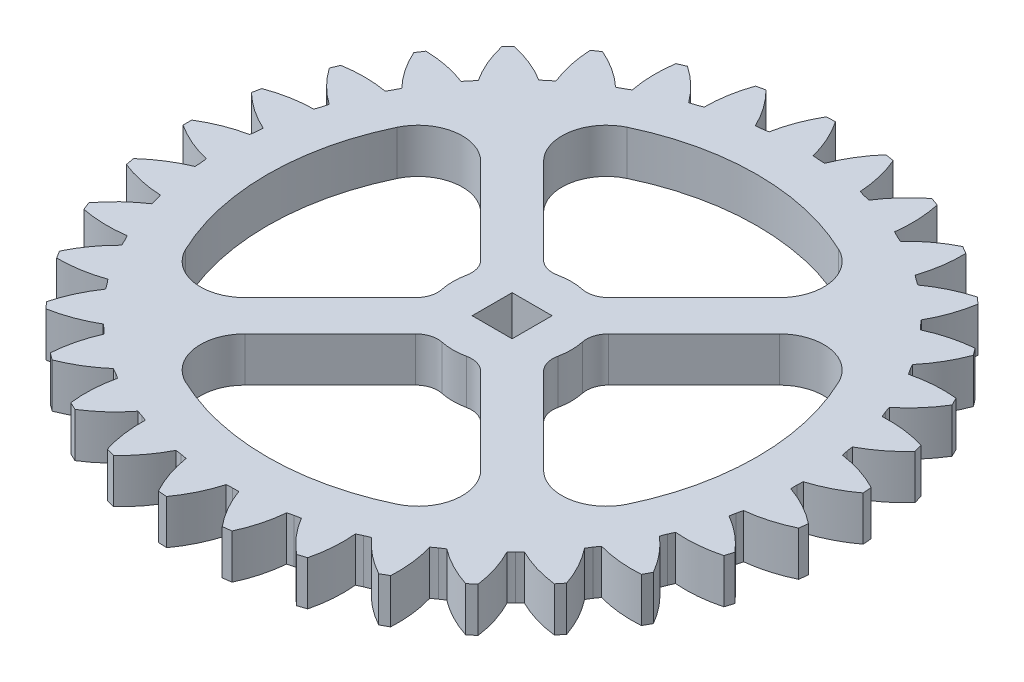
SolidWorks part; units mm, degrees
ref_plane "Front Plane" through (0, 0, 0) normal (0, 0, 1) x (1, 0, 0)
ref_plane "Top Plane" through (0, 0, 0) normal (0, 1, 0) x (1, 0, 0)
ref_plane "Right Plane" through (0, 0, 0) normal (1, 0, 0) x (0, 0, -1)
ref_axis "Axis1" through (0, -1.7463, 0) along (0, 1, 0)
sketch "Sketch1" plane through (0, 0, 0) normal (0, 1, 0) x (1, 0, 0)
  circle A0 centre (0, 0) radius 21.0039 construction
  circle A1 centre (0, 0) radius 21.0039
sketch "Sketch3" plane through (0, 0, 0) normal (0, 1, 0) x (1, 0, 0)
  line L0 (19.5384, 0) -> (19.5462, 0.1213)
  line L1 (19.5462, 0.1213) -> (19.5989, 0.1361)
  line L2 (19.5989, 0.1361) -> (19.6534, 0.1521)
  line L3 (19.6534, 0.1521) -> (19.7098, 0.1692)
  line L4 (19.7098, 0.1692) -> (19.768, 0.1876)
  line L5 (19.768, 0.1876) -> (19.8281, 0.2073)
  line L6 (19.8281, 0.2073) -> (19.8899, 0.2282)
  line L7 (19.8899, 0.2282) -> (19.9535, 0.2506)
  line L8 (19.9535, 0.2506) -> (20.0188, 0.2743)
  line L9 (20.0188, 0.2743) -> (20.0859, 0.2994)
  line L10 (20.0859, 0.2994) -> (20.1547, 0.326)
  line L11 (20.1547, 0.326) -> (20.2251, 0.3541)
  line L12 (20.2251, 0.3541) -> (20.2972, 0.3838)
  line L13 (20.2972, 0.3838) -> (20.3709, 0.4151)
  line L14 (20.3709, 0.4151) -> (20.4462, 0.448)
  line L15 (20.4462, 0.448) -> (20.5231, 0.4825)
  line L16 (20.5231, 0.4825) -> (20.6015, 0.5187)
  line L17 (20.6015, 0.5187) -> (20.6815, 0.5567)
  line L18 (20.6815, 0.5567) -> (20.763, 0.5964)
  line L19 (20.763, 0.5964) -> (20.8459, 0.638)
  line L20 (20.8459, 0.638) -> (20.9302, 0.6814)
  line L21 (20.9302, 0.6814) -> (21.016, 0.7266)
  line L22 (21.016, 0.7266) -> (21.1031, 0.7738)
  line L23 (21.1031, 0.7738) -> (21.1916, 0.8229)
  line L24 (21.1916, 0.8229) -> (21.2814, 0.874)
  line L25 (21.2814, 0.874) -> (21.3724, 0.9271)
  line L26 (21.3724, 0.9271) -> (21.4647, 0.9823)
  line L27 (21.4647, 0.9823) -> (21.5583, 1.0395)
  line L28 (21.5583, 1.0395) -> (21.6529, 1.0988)
  line L29 (21.6529, 1.0988) -> (21.7488, 1.1603)
  line L30 (21.7488, 1.1603) -> (21.8457, 1.2239)
  line L31 (21.8457, 1.2239) -> (21.9438, 1.2898)
  line L32 (21.9438, 1.2898) -> (22.0428, 1.3578)
  line L33 (22.0428, 1.3578) -> (22.1429, 1.4282)
  line L34 (22.1429, 1.4282) -> (22.1933, 1.4642)
  line L35 (22.1933, 1.4642) -> (22.2186, 1.4824)
  line L36 (22.2186, 1.4824) -> (22.2249, 1.487)
  line L37 (22.2249, 1.487) -> (22.2251, 1.4871)
  line L38 (22.2251, 1.4871) -> (22.2253, 1.4873)
  line L39 (22.2253, 1.4873) -> (22.1778, 2.079)
  line L40 (22.1778, 2.079) -> (22.1776, 2.0791)
  line L41 (22.1776, 2.0791) -> (22.1774, 2.0792)
  line L42 (22.1774, 2.0792) -> (22.1704, 2.0827)
  line L43 (22.1704, 2.0827) -> (22.1425, 2.0967)
  line L44 (22.1425, 2.0967) -> (22.087, 2.1242)
  line L45 (22.087, 2.1242) -> (21.977, 2.1776)
  line L46 (21.977, 2.1776) -> (21.8683, 2.229)
  line L47 (21.8683, 2.229) -> (21.7611, 2.2783)
  line L48 (21.7611, 2.2783) -> (21.6552, 2.3257)
  line L49 (21.6552, 2.3257) -> (21.5508, 2.3711)
  line L50 (21.5508, 2.3711) -> (21.4478, 2.4145)
  line L51 (21.4478, 2.4145) -> (21.3464, 2.4561)
  line L52 (21.3464, 2.4561) -> (21.2464, 2.4958)
  line L53 (21.2464, 2.4958) -> (21.1481, 2.5337)
  line L54 (21.1481, 2.5337) -> (21.0513, 2.5698)
  line L55 (21.0513, 2.5698) -> (20.9561, 2.6042)
  line L56 (20.9561, 2.6042) -> (20.8626, 2.6368)
  line L57 (20.8626, 2.6368) -> (20.7707, 2.6678)
  line L58 (20.7707, 2.6678) -> (20.6805, 2.6972)
  line L59 (20.6805, 2.6972) -> (20.592, 2.725)
  line L60 (20.592, 2.725) -> (20.5053, 2.7512)
  line L61 (20.5053, 2.7512) -> (20.4203, 2.7759)
  line L62 (20.4203, 2.7759) -> (20.3371, 2.7992)
  line L63 (20.3371, 2.7992) -> (20.2556, 2.821)
  line L64 (20.2556, 2.821) -> (20.176, 2.8414)
  line L65 (20.176, 2.8414) -> (20.0983, 2.8605)
  line L66 (20.0983, 2.8605) -> (20.0224, 2.8783)
  line L67 (20.0224, 2.8783) -> (19.9483, 2.8948)
  line L68 (19.9483, 2.8948) -> (19.8762, 2.9101)
  line L69 (19.8762, 2.9101) -> (19.806, 2.9243)
  line L70 (19.806, 2.9243) -> (19.7377, 2.9372)
  line L71 (19.7377, 2.9372) -> (19.6714, 2.9491)
  line L72 (19.6714, 2.9491) -> (19.607, 2.96)
  line L73 (19.607, 2.96) -> (19.5446, 2.9698)
  line L74 (19.5446, 2.9698) -> (19.4842, 2.9786)
  line L75 (19.4842, 2.9786) -> (19.4258, 2.9866)
  line L76 (19.4258, 2.9866) -> (19.3694, 2.9936)
  line L77 (19.3694, 2.9936) -> (19.315, 2.9998)
  line L78 (19.315, 2.9998) -> (19.2879, 3.1183)
  line L79 (19.2879, 3.1183) -> (19.1853, 3.6977)
  line L80 (19.1853, 3.6977) -> (19.17, 3.8182)
  line L81 (19.17, 3.8182) -> (19.2189, 3.8428)
  line L82 (19.2189, 3.8428) -> (19.2695, 3.8688)
  line L83 (19.2695, 3.8688) -> (19.3216, 3.8963)
  line L84 (19.3216, 3.8963) -> (19.3753, 3.9253)
  line L85 (19.3753, 3.9253) -> (19.4305, 3.956)
  line L86 (19.4305, 3.956) -> (19.4873, 3.9883)
  line L87 (19.4873, 3.9883) -> (19.5455, 4.0223)
  line L88 (19.5455, 4.0223) -> (19.6052, 4.0579)
  line L89 (19.6052, 4.0579) -> (19.6663, 4.0953)
  line L90 (19.6663, 4.0953) -> (19.7287, 4.1344)
  line L91 (19.7287, 4.1344) -> (19.7926, 4.1754)
  line L92 (19.7926, 4.1754) -> (19.8578, 4.2182)
  line L93 (19.8578, 4.2182) -> (19.9242, 4.2628)
  line L94 (19.9242, 4.2628) -> (19.992, 4.3093)
  line L95 (19.992, 4.3093) -> (20.0609, 4.3578)
  line L96 (20.0609, 4.3578) -> (20.1311, 4.4082)
  line L97 (20.1311, 4.4082) -> (20.2024, 4.4606)
  line L98 (20.2024, 4.4606) -> (20.2749, 4.5151)
  line L99 (20.2749, 4.5151) -> (20.3484, 4.5716)
  line L100 (20.3484, 4.5716) -> (20.423, 4.6301)
  line L101 (20.423, 4.6301) -> (20.4987, 4.6908)
  line L102 (20.4987, 4.6908) -> (20.5753, 4.7536)
  line L103 (20.5753, 4.7536) -> (20.6529, 4.8186)
  line L104 (20.6529, 4.8186) -> (20.7314, 4.8857)
  line L105 (20.7314, 4.8857) -> (20.8107, 4.9551)
  line L106 (20.8107, 4.9551) -> (20.8909, 5.0267)
  line L107 (20.8909, 5.0267) -> (20.9719, 5.1006)
  line L108 (20.9719, 5.1006) -> (21.0537, 5.1768)
  line L109 (21.0537, 5.1768) -> (21.1362, 5.2553)
  line L110 (21.1362, 5.2553) -> (21.2193, 5.3361)
  line L111 (21.2193, 5.3361) -> (21.3031, 5.4193)
  line L112 (21.3031, 5.4193) -> (21.3875, 5.5049)
  line L113 (21.3875, 5.5049) -> (21.4725, 5.5929)
  line L114 (21.4725, 5.5929) -> (21.5152, 5.6378)
  line L115 (21.5152, 5.6378) -> (21.5365, 5.6605)
  line L116 (21.5365, 5.6605) -> (21.5419, 5.6662)
  line L117 (21.5419, 5.6662) -> (21.5421, 5.6664)
  line L118 (21.5421, 5.6664) -> (21.5422, 5.6665)
  line L119 (21.5422, 5.6665) -> (21.3835, 6.2386)
  line L120 (21.3835, 6.2386) -> (21.3833, 6.2386)
  line L121 (21.3833, 6.2386) -> (21.3831, 6.2387)
  line L122 (21.3831, 6.2387) -> (21.3756, 6.2408)
  line L123 (21.3756, 6.2408) -> (21.3456, 6.2493)
  line L124 (21.3456, 6.2493) -> (21.2859, 6.2658)
  line L125 (21.2859, 6.2658) -> (21.1677, 6.2974)
  line L126 (21.1677, 6.2974) -> (21.0513, 6.3273)
  line L127 (21.0513, 6.3273) -> (20.9366, 6.3555)
  line L128 (20.9366, 6.3555) -> (20.8237, 6.3819)
  line L129 (20.8237, 6.3819) -> (20.7126, 6.4067)
  line L130 (20.7126, 6.4067) -> (20.6033, 6.4299)
  line L131 (20.6033, 6.4299) -> (20.4958, 6.4515)
  line L132 (20.4958, 6.4515) -> (20.3901, 6.4716)
  line L133 (20.3901, 6.4716) -> (20.2864, 6.4902)
  line L134 (20.2864, 6.4902) -> (20.1845, 6.5074)
  line L135 (20.1845, 6.5074) -> (20.0846, 6.5231)
  line L136 (20.0846, 6.5231) -> (19.9865, 6.5375)
  line L137 (19.9865, 6.5375) -> (19.8904, 6.5505)
  line L138 (19.8904, 6.5505) -> (19.7963, 6.5623)
  line L139 (19.7963, 6.5623) -> (19.7042, 6.5728)
  line L140 (19.7042, 6.5728) -> (19.614, 6.5821)
  line L141 (19.614, 6.5821) -> (19.5259, 6.5903)
  line L142 (19.5259, 6.5903) -> (19.4398, 6.5974)
  line L143 (19.4398, 6.5974) -> (19.3557, 6.6034)
  line L144 (19.3557, 6.6034) -> (19.2737, 6.6084)
  line L145 (19.2737, 6.6084) -> (19.1937, 6.6125)
  line L146 (19.1937, 6.6125) -> (19.1158, 6.6156)
  line L147 (19.1158, 6.6156) -> (19.04, 6.6178)
  line L148 (19.04, 6.6178) -> (18.9663, 6.6191)
  line L149 (18.9663, 6.6191) -> (18.8947, 6.6197)
  line L150 (18.8947, 6.6197) -> (18.8252, 6.6195)
  line L151 (18.8252, 6.6195) -> (18.7578, 6.6187)
  line L152 (18.7578, 6.6187) -> (18.6925, 6.6171)
  line L153 (18.6925, 6.6171) -> (18.6294, 6.6149)
  line L154 (18.6294, 6.6149) -> (18.5684, 6.6122)
  line L155 (18.5684, 6.6122) -> (18.5095, 6.6089)
  line L156 (18.5095, 6.6089) -> (18.4528, 6.6052)
  line L157 (18.4528, 6.6052) -> (18.3982, 6.601)
  line L158 (18.3982, 6.601) -> (18.3492, 6.7122)
  line L159 (18.3492, 6.7122) -> (18.1388, 7.2617)
  line L160 (18.1388, 7.2617) -> (18.101, 7.3772)
  line L161 (18.101, 7.3772) -> (18.1444, 7.4105)
  line L162 (18.1444, 7.4105) -> (18.1891, 7.4456)
  line L163 (18.1891, 7.4456) -> (18.2351, 7.4825)
  line L164 (18.2351, 7.4825) -> (18.2823, 7.5212)
  line L165 (18.2823, 7.5212) -> (18.3307, 7.5618)
  line L166 (18.3307, 7.5618) -> (18.3803, 7.6042)
  line L167 (18.3803, 7.6042) -> (18.4311, 7.6486)
  line L168 (18.4311, 7.6486) -> (18.4829, 7.6949)
  line L169 (18.4829, 7.6949) -> (18.5358, 7.7431)
  line L170 (18.5358, 7.7431) -> (18.5898, 7.7934)
  line L171 (18.5898, 7.7934) -> (18.6447, 7.8457)
  line L172 (18.6447, 7.8457) -> (18.7006, 7.9)
  line L173 (18.7006, 7.9) -> (18.7574, 7.9564)
  line L174 (18.7574, 7.9564) -> (18.8151, 8.015)
  line L175 (18.8151, 8.015) -> (18.8737, 8.0756)
  line L176 (18.8737, 8.0756) -> (18.933, 8.1384)
  line L177 (18.933, 8.1384) -> (18.9931, 8.2034)
  line L178 (18.9931, 8.2034) -> (19.054, 8.2705)
  line L179 (19.054, 8.2705) -> (19.1155, 8.3399)
  line L180 (19.1155, 8.3399) -> (19.1777, 8.4115)
  line L181 (19.1777, 8.4115) -> (19.2405, 8.4854)
  line L182 (19.2405, 8.4854) -> (19.3039, 8.5616)
  line L183 (19.3039, 8.5616) -> (19.3677, 8.6401)
  line L184 (19.3677, 8.6401) -> (19.4321, 8.7209)
  line L185 (19.4321, 8.7209) -> (19.4969, 8.804)
  line L186 (19.4969, 8.804) -> (19.5621, 8.8895)
  line L187 (19.5621, 8.8895) -> (19.6276, 8.9774)
  line L188 (19.6276, 8.9774) -> (19.6935, 9.0677)
  line L189 (19.6935, 9.0677) -> (19.7596, 9.1604)
  line L190 (19.7596, 9.1604) -> (19.826, 9.2555)
  line L191 (19.826, 9.2555) -> (19.8925, 9.353)
  line L192 (19.8925, 9.353) -> (19.9592, 9.4531)
  line L193 (19.9592, 9.4531) -> (20.026, 9.5555)
  line L194 (20.026, 9.5555) -> (20.0594, 9.6077)
  line L195 (20.0594, 9.6077) -> (20.0761, 9.634)
  line L196 (20.0761, 9.634) -> (20.0803, 9.6406)
  line L197 (20.0803, 9.6406) -> (20.0804, 9.6408)
  line L198 (20.0804, 9.6408) -> (20.0805, 9.641)
  line L199 (20.0805, 9.641) -> (19.8165, 10.1727)
  line L200 (19.8165, 10.1727) -> (19.8162, 10.1727)
  line L201 (19.8162, 10.1727) -> (19.816, 10.1727)
  line L202 (19.816, 10.1727) -> (19.8082, 10.1734)
  line L203 (19.8082, 10.1734) -> (19.7772, 10.176)
  line L204 (19.7772, 10.176) -> (19.7154, 10.1809)
  line L205 (19.7154, 10.1809) -> (19.5934, 10.1897)
  line L206 (19.5934, 10.1897) -> (19.4734, 10.197)
  line L207 (19.4734, 10.197) -> (19.3555, 10.2029)
  line L208 (19.3555, 10.2029) -> (19.2396, 10.2075)
  line L209 (19.2396, 10.2075) -> (19.1258, 10.2108)
  line L210 (19.1258, 10.2108) -> (19.0141, 10.2129)
  line L211 (19.0141, 10.2129) -> (18.9044, 10.2138)
  line L212 (18.9044, 10.2138) -> (18.7969, 10.2135)
  line L213 (18.7969, 10.2135) -> (18.6915, 10.2121)
  line L214 (18.6915, 10.2121) -> (18.5882, 10.2097)
  line L215 (18.5882, 10.2097) -> (18.4871, 10.2062)
  line L216 (18.4871, 10.2062) -> (18.3881, 10.2018)
  line L217 (18.3881, 10.2018) -> (18.2913, 10.1964)
  line L218 (18.2913, 10.1964) -> (18.1967, 10.1902)
  line L219 (18.1967, 10.1902) -> (18.1042, 10.1831)
  line L220 (18.1042, 10.1831) -> (18.0139, 10.1752)
  line L221 (18.0139, 10.1752) -> (17.9258, 10.1665)
  line L222 (17.9258, 10.1665) -> (17.8399, 10.1572)
  line L223 (17.8399, 10.1572) -> (17.7562, 10.1472)
  line L224 (17.7562, 10.1472) -> (17.6747, 10.1366)
  line L225 (17.6747, 10.1366) -> (17.5954, 10.1254)
  line L226 (17.5954, 10.1254) -> (17.5184, 10.1137)
  line L227 (17.5184, 10.1137) -> (17.4435, 10.1015)
  line L228 (17.4435, 10.1015) -> (17.3709, 10.0889)
  line L229 (17.3709, 10.0889) -> (17.3004, 10.0759)
  line L230 (17.3004, 10.0759) -> (17.2322, 10.0626)
  line L231 (17.2322, 10.0626) -> (17.1662, 10.049)
  line L232 (17.1662, 10.049) -> (17.1024, 10.0351)
  line L233 (17.1024, 10.0351) -> (17.0408, 10.021)
  line L234 (17.0408, 10.021) -> (16.9814, 10.0068)
  line L235 (16.9814, 10.0068) -> (16.9243, 9.9925)
  line L236 (16.9243, 9.9925) -> (16.8693, 9.978)
  line L237 (16.8693, 9.978) -> (16.8165, 9.9636)
  line L238 (16.8165, 9.9636) -> (16.7473, 10.0635)
  line L239 (16.7473, 10.0635) -> (16.4367, 10.5632)
  line L240 (16.4367, 10.5632) -> (16.3777, 10.6695)
  line L241 (16.3777, 10.6695) -> (16.414, 10.7105)
  line L242 (16.414, 10.7105) -> (16.4513, 10.7534)
  line L243 (16.4513, 10.7534) -> (16.4895, 10.7983)
  line L244 (16.4895, 10.7983) -> (16.5285, 10.8452)
  line L245 (16.5285, 10.8452) -> (16.5684, 10.8942)
  line L246 (16.5684, 10.8942) -> (16.6091, 10.9453)
  line L247 (16.6091, 10.9453) -> (16.6505, 10.9985)
  line L248 (16.6505, 10.9985) -> (16.6926, 11.0537)
  line L249 (16.6926, 11.0537) -> (16.7355, 11.1111)
  line L250 (16.7355, 11.1111) -> (16.7789, 11.1707)
  line L251 (16.7789, 11.1707) -> (16.823, 11.2324)
  line L252 (16.823, 11.2324) -> (16.8676, 11.2964)
  line L253 (16.8676, 11.2964) -> (16.9127, 11.3625)
  line L254 (16.9127, 11.3625) -> (16.9583, 11.4309)
  line L255 (16.9583, 11.4309) -> (17.0043, 11.5015)
  line L256 (17.0043, 11.5015) -> (17.0507, 11.5744)
  line L257 (17.0507, 11.5744) -> (17.0974, 11.6496)
  line L258 (17.0974, 11.6496) -> (17.1445, 11.7271)
  line L259 (17.1445, 11.7271) -> (17.1917, 11.8068)
  line L260 (17.1917, 11.8068) -> (17.2393, 11.8889)
  line L261 (17.2393, 11.8889) -> (17.2869, 11.9734)
  line L262 (17.2869, 11.9734) -> (17.3347, 12.0602)
  line L263 (17.3347, 12.0602) -> (17.3826, 12.1493)
  line L264 (17.3826, 12.1493) -> (17.4305, 12.2408)
  line L265 (17.4305, 12.2408) -> (17.4784, 12.3347)
  line L266 (17.4784, 12.3347) -> (17.5262, 12.431)
  line L267 (17.5262, 12.431) -> (17.574, 12.5297)
  line L268 (17.574, 12.5297) -> (17.6216, 12.6309)
  line L269 (17.6216, 12.6309) -> (17.669, 12.7344)
  line L270 (17.669, 12.7344) -> (17.7161, 12.8403)
  line L271 (17.7161, 12.8403) -> (17.763, 12.9487)
  line L272 (17.763, 12.9487) -> (17.8095, 13.0595)
  line L273 (17.8095, 13.0595) -> (17.8557, 13.1728)
  line L274 (17.8557, 13.1728) -> (17.8786, 13.2304)
  line L275 (17.8786, 13.2304) -> (17.89, 13.2594)
  line L276 (17.89, 13.2594) -> (17.8929, 13.2666)
  line L277 (17.8929, 13.2666) -> (17.893, 13.2669)
  line L278 (17.893, 13.2669) -> (17.893, 13.2671)
  line L279 (17.893, 13.2671) -> (17.5332, 13.7392)
  line L280 (17.5332, 13.7392) -> (17.5329, 13.7391)
  line L281 (17.5329, 13.7391) -> (17.5327, 13.7391)
  line L282 (17.5327, 13.7391) -> (17.5249, 13.7383)
  line L283 (17.5249, 13.7383) -> (17.4939, 13.735)
  line L284 (17.4939, 13.735) -> (17.4324, 13.7281)
  line L285 (17.4324, 13.7281) -> (17.3109, 13.7136)
  line L286 (17.3109, 13.7136) -> (17.1917, 13.6981)
  line L287 (17.1917, 13.6981) -> (17.0748, 13.6816)
  line L288 (17.0748, 13.6816) -> (16.9601, 13.6642)
  line L289 (16.9601, 13.6642) -> (16.8478, 13.6459)
  line L290 (16.8478, 13.6459) -> (16.7376, 13.6268)
  line L291 (16.7376, 13.6268) -> (16.6298, 13.6069)
  line L292 (16.6298, 13.6069) -> (16.5243, 13.5863)
  line L293 (16.5243, 13.5863) -> (16.4211, 13.565)
  line L294 (16.4211, 13.565) -> (16.3201, 13.543)
  line L295 (16.3201, 13.543) -> (16.2215, 13.5205)
  line L296 (16.2215, 13.5205) -> (16.1251, 13.4974)
  line L297 (16.1251, 13.4974) -> (16.0311, 13.4738)
  line L298 (16.0311, 13.4738) -> (15.9393, 13.4497)
  line L299 (15.9393, 13.4497) -> (15.8499, 13.4253)
  line L300 (15.8499, 13.4253) -> (15.7627, 13.4004)
  line L301 (15.7627, 13.4004) -> (15.6778, 13.3753)
  line L302 (15.6778, 13.3753) -> (15.5953, 13.3499)
  line L303 (15.5953, 13.3499) -> (15.515, 13.3242)
  line L304 (15.515, 13.3242) -> (15.437, 13.2984)
  line L305 (15.437, 13.2984) -> (15.3612, 13.2724)
  line L306 (15.3612, 13.2724) -> (15.2878, 13.2463)
  line L307 (15.2878, 13.2463) -> (15.2165, 13.2202)
  line L308 (15.2165, 13.2202) -> (15.1476, 13.1941)
  line L309 (15.1476, 13.1941) -> (15.0809, 13.168)
  line L310 (15.0809, 13.168) -> (15.0164, 13.142)
  line L311 (15.0164, 13.142) -> (14.9542, 13.1161)
  line L312 (14.9542, 13.1161) -> (14.8942, 13.0904)
  line L313 (14.8942, 13.0904) -> (14.8364, 13.0649)
  line L314 (14.8364, 13.0649) -> (14.7808, 13.0397)
  line L315 (14.7808, 13.0397) -> (14.7273, 13.0148)
  line L316 (14.7273, 13.0148) -> (14.6761, 12.9903)
  line L317 (14.6761, 12.9903) -> (14.627, 12.9661)
  line L318 (14.627, 12.9661) -> (14.5401, 13.0511)
  line L319 (14.5401, 13.0511) -> (14.1406, 13.483)
  line L320 (14.1406, 13.483) -> (14.0625, 13.5762)
  line L321 (14.0625, 13.5762) -> (14.0904, 13.6233)
  line L322 (14.0904, 13.6233) -> (14.1189, 13.6725)
  line L323 (14.1189, 13.6725) -> (14.1479, 13.7238)
  line L324 (14.1479, 13.7238) -> (14.1773, 13.7773)
  line L325 (14.1773, 13.7773) -> (14.2072, 13.833)
  line L326 (14.2072, 13.833) -> (14.2375, 13.8908)
  line L327 (14.2375, 13.8908) -> (14.2681, 13.9508)
  line L328 (14.2681, 13.9508) -> (14.299, 14.0131)
  line L329 (14.299, 14.0131) -> (14.3302, 14.0776)
  line L330 (14.3302, 14.0776) -> (14.3616, 14.1443)
  line L331 (14.3616, 14.1443) -> (14.3932, 14.2132)
  line L332 (14.3932, 14.2132) -> (14.4249, 14.2844)
  line L333 (14.4249, 14.2844) -> (14.4567, 14.3579)
  line L334 (14.4567, 14.3579) -> (14.4885, 14.4337)
  line L335 (14.4885, 14.4337) -> (14.5203, 14.5118)
  line L336 (14.5203, 14.5118) -> (14.5521, 14.5921)
  line L337 (14.5521, 14.5921) -> (14.5837, 14.6748)
  line L338 (14.5837, 14.6748) -> (14.6153, 14.7598)
  line L339 (14.6153, 14.7598) -> (14.6466, 14.847)
  line L340 (14.6466, 14.847) -> (14.6777, 14.9366)
  line L341 (14.6777, 14.9366) -> (14.7085, 15.0286)
  line L342 (14.7085, 15.0286) -> (14.7391, 15.1228)
  line L343 (14.7391, 15.1228) -> (14.7692, 15.2194)
  line L344 (14.7692, 15.2194) -> (14.7989, 15.3184)
  line L345 (14.7989, 15.3184) -> (14.8282, 15.4196)
  line L346 (14.8282, 15.4196) -> (14.8569, 15.5233)
  line L347 (14.8569, 15.5233) -> (14.8851, 15.6292)
  line L348 (14.8851, 15.6292) -> (14.9127, 15.7375)
  line L349 (14.9127, 15.7375) -> (14.9397, 15.8481)
  line L350 (14.9397, 15.8481) -> (14.9659, 15.9611)
  line L351 (14.9659, 15.9611) -> (14.9914, 16.0764)
  line L352 (14.9914, 16.0764) -> (15.0161, 16.194)
  line L353 (15.0161, 16.194) -> (15.04, 16.314)
  line L354 (15.04, 16.314) -> (15.0517, 16.3748)
  line L355 (15.0517, 16.3748) -> (15.0574, 16.4055)
  line L356 (15.0574, 16.4055) -> (15.0588, 16.4131)
  line L357 (15.0588, 16.4131) -> (15.0589, 16.4134)
  line L358 (15.0589, 16.4134) -> (15.0589, 16.4136)
  line L359 (15.0589, 16.4136) -> (14.6162, 16.809)
  line L360 (14.6162, 16.809) -> (14.6159, 16.809)
  line L361 (14.6159, 16.809) -> (14.6157, 16.8089)
  line L362 (14.6157, 16.8089) -> (14.6082, 16.8066)
  line L363 (14.6082, 16.8066) -> (14.5784, 16.7975)
  line L364 (14.5784, 16.7975) -> (14.5193, 16.7791)
  line L365 (14.5193, 16.7791) -> (14.4028, 16.7419)
  line L366 (14.4028, 16.7419) -> (14.2887, 16.7041)
  line L367 (14.2887, 16.7041) -> (14.177, 16.6658)
  line L368 (14.177, 16.6658) -> (14.0677, 16.627)
  line L369 (14.0677, 16.627) -> (13.9608, 16.5878)
  line L370 (13.9608, 16.5878) -> (13.8563, 16.5482)
  line L371 (13.8563, 16.5482) -> (13.7542, 16.5082)
  line L372 (13.7542, 16.5082) -> (13.6545, 16.468)
  line L373 (13.6545, 16.468) -> (13.5571, 16.4276)
  line L374 (13.5571, 16.4276) -> (13.4622, 16.3869)
  line L375 (13.4622, 16.3869) -> (13.3696, 16.3461)
  line L376 (13.3696, 16.3461) -> (13.2793, 16.3052)
  line L377 (13.2793, 16.3052) -> (13.1914, 16.2642)
  line L378 (13.1914, 16.2642) -> (13.1059, 16.2232)
  line L379 (13.1059, 16.2232) -> (13.0227, 16.1823)
  line L380 (13.0227, 16.1823) -> (12.9418, 16.1414)
  line L381 (12.9418, 16.1414) -> (12.8632, 16.1006)
  line L382 (12.8632, 16.1006) -> (12.787, 16.06)
  line L383 (12.787, 16.06) -> (12.713, 16.0196)
  line L384 (12.713, 16.0196) -> (12.6413, 15.9795)
  line L385 (12.6413, 15.9795) -> (12.5718, 15.9397)
  line L386 (12.5718, 15.9397) -> (12.5046, 15.9002)
  line L387 (12.5046, 15.9002) -> (12.4396, 15.861)
  line L388 (12.4396, 15.861) -> (12.3769, 15.8223)
  line L389 (12.3769, 15.8223) -> (12.3163, 15.7841)
  line L390 (12.3163, 15.7841) -> (12.2579, 15.7464)
  line L391 (12.2579, 15.7464) -> (12.2017, 15.7092)
  line L392 (12.2017, 15.7092) -> (12.1477, 15.6726)
  line L393 (12.1477, 15.6726) -> (12.0957, 15.6366)
  line L394 (12.0957, 15.6366) -> (12.0459, 15.6014)
  line L395 (12.0459, 15.6014) -> (11.9981, 15.5668)
  line L396 (11.9981, 15.5668) -> (11.9524, 15.533)
  line L397 (11.9524, 15.533) -> (11.9088, 15.5)
  line L398 (11.9088, 15.5) -> (11.8074, 15.567)
  line L399 (11.8074, 15.567) -> (11.3334, 15.9155)
  line L400 (11.3334, 15.9155) -> (11.2391, 15.9922)
  line L401 (11.2391, 15.9922) -> (11.2576, 16.0437)
  line L402 (11.2576, 16.0437) -> (11.2762, 16.0974)
  line L403 (11.2762, 16.0974) -> (11.295, 16.1533)
  line L404 (11.295, 16.1533) -> (11.3138, 16.2114)
  line L405 (11.3138, 16.2114) -> (11.3326, 16.2717)
  line L406 (11.3326, 16.2717) -> (11.3514, 16.3342)
  line L407 (11.3514, 16.3342) -> (11.3701, 16.399)
  line L408 (11.3701, 16.399) -> (11.3887, 16.466)
  line L409 (11.3887, 16.466) -> (11.4071, 16.5352)
  line L410 (11.4071, 16.5352) -> (11.4253, 16.6066)
  line L411 (11.4253, 16.6066) -> (11.4432, 16.6803)
  line L412 (11.4432, 16.6803) -> (11.4609, 16.7562)
  line L413 (11.4609, 16.7562) -> (11.4782, 16.8344)
  line L414 (11.4782, 16.8344) -> (11.4951, 16.9148)
  line L415 (11.4951, 16.9148) -> (11.5115, 16.9975)
  line L416 (11.5115, 16.9975) -> (11.5275, 17.0824)
  line L417 (11.5275, 17.0824) -> (11.543, 17.1696)
  line L418 (11.543, 17.1696) -> (11.5579, 17.259)
  line L419 (11.5579, 17.259) -> (11.5721, 17.3506)
  line L420 (11.5721, 17.3506) -> (11.5857, 17.4445)
  line L421 (11.5857, 17.4445) -> (11.5986, 17.5406)
  line L422 (11.5986, 17.5406) -> (11.6107, 17.6389)
  line L423 (11.6107, 17.6389) -> (11.622, 17.7395)
  line L424 (11.622, 17.7395) -> (11.6325, 17.8423)
  line L425 (11.6325, 17.8423) -> (11.642, 17.9472)
  line L426 (11.642, 17.9472) -> (11.6506, 18.0544)
  line L427 (11.6506, 18.0544) -> (11.6583, 18.1638)
  line L428 (11.6583, 18.1638) -> (11.6649, 18.2753)
  line L429 (11.6649, 18.2753) -> (11.6704, 18.3891)
  line L430 (11.6704, 18.3891) -> (11.6748, 18.505)
  line L431 (11.6748, 18.505) -> (11.678, 18.623)
  line L432 (11.678, 18.623) -> (11.6801, 18.7432)
  line L433 (11.6801, 18.7432) -> (11.6808, 18.8655)
  line L434 (11.6808, 18.8655) -> (11.6807, 18.9274)
  line L435 (11.6807, 18.9274) -> (11.6805, 18.9586)
  line L436 (11.6805, 18.9586) -> (11.6805, 18.9664)
  line L437 (11.6805, 18.9664) -> (11.6805, 18.9667)
  line L438 (11.6805, 18.9667) -> (11.6805, 18.9669)
  line L439 (11.6805, 18.9669) -> (11.1709, 19.2714)
  line L440 (11.1709, 19.2714) -> (11.1707, 19.2713)
  line L441 (11.1707, 19.2713) -> (11.1705, 19.2712)
  line L442 (11.1705, 19.2712) -> (11.1636, 19.2675)
  line L443 (11.1636, 19.2675) -> (11.136, 19.2529)
  line L444 (11.136, 19.2529) -> (11.0814, 19.2237)
  line L445 (11.0814, 19.2237) -> (10.9741, 19.1651)
  line L446 (10.9741, 19.1651) -> (10.8692, 19.1064)
  line L447 (10.8692, 19.1064) -> (10.7668, 19.0476)
  line L448 (10.7668, 19.0476) -> (10.6668, 18.9888)
  line L449 (10.6668, 18.9888) -> (10.5692, 18.9301)
  line L450 (10.5692, 18.9301) -> (10.4741, 18.8714)
  line L451 (10.4741, 18.8714) -> (10.3814, 18.8129)
  line L452 (10.3814, 18.8129) -> (10.2911, 18.7545)
  line L453 (10.2911, 18.7545) -> (10.2032, 18.6964)
  line L454 (10.2032, 18.6964) -> (10.1176, 18.6385)
  line L455 (10.1176, 18.6385) -> (10.0344, 18.5809)
  line L456 (10.0344, 18.5809) -> (9.9536, 18.5237)
  line L457 (9.9536, 18.5237) -> (9.875, 18.4668)
  line L458 (9.875, 18.4668) -> (9.7988, 18.4104)
  line L459 (9.7988, 18.4104) -> (9.7248, 18.3544)
  line L460 (9.7248, 18.3544) -> (9.6532, 18.299)
  line L461 (9.6532, 18.299) -> (9.5837, 18.2441)
  line L462 (9.5837, 18.2441) -> (9.5165, 18.1898)
  line L463 (9.5165, 18.1898) -> (9.4515, 18.1361)
  line L464 (9.4515, 18.1361) -> (9.3887, 18.0831)
  line L465 (9.3887, 18.0831) -> (9.328, 18.0308)
  line L466 (9.328, 18.0308) -> (9.2695, 17.9793)
  line L467 (9.2695, 17.9793) -> (9.2131, 17.9286)
  line L468 (9.2131, 17.9286) -> (9.1588, 17.8787)
  line L469 (9.1588, 17.8787) -> (9.1066, 17.8297)
  line L470 (9.1066, 17.8297) -> (9.0564, 17.7816)
  line L471 (9.0564, 17.7816) -> (9.0082, 17.7345)
  line L472 (9.0082, 17.7345) -> (8.9621, 17.6883)
  line L473 (8.9621, 17.6883) -> (8.9179, 17.6432)
  line L474 (8.9179, 17.6432) -> (8.8756, 17.5991)
  line L475 (8.8756, 17.5991) -> (8.8353, 17.5561)
  line L476 (8.8353, 17.5561) -> (8.7968, 17.5143)
  line L477 (8.7968, 17.5143) -> (8.7602, 17.4736)
  line L478 (8.7602, 17.4736) -> (8.648, 17.5203)
  line L479 (8.648, 17.5203) -> (8.1165, 17.7727)
  line L480 (8.1165, 17.7727) -> (8.0094, 17.8302)
  line L481 (8.0094, 17.8302) -> (8.0179, 17.8843)
  line L482 (8.0179, 17.8843) -> (8.026, 17.9406)
  line L483 (8.026, 17.9406) -> (8.0338, 17.999)
  line L484 (8.0338, 17.999) -> (8.0413, 18.0596)
  line L485 (8.0413, 18.0596) -> (8.0483, 18.1224)
  line L486 (8.0483, 18.1224) -> (8.055, 18.1873)
  line L487 (8.055, 18.1873) -> (8.0611, 18.2544)
  line L488 (8.0611, 18.2544) -> (8.0666, 18.3237)
  line L489 (8.0666, 18.3237) -> (8.0716, 18.3952)
  line L490 (8.0716, 18.3952) -> (8.076, 18.4688)
  line L491 (8.076, 18.4688) -> (8.0797, 18.5445)
  line L492 (8.0797, 18.5445) -> (8.0826, 18.6224)
  line L493 (8.0826, 18.6224) -> (8.0848, 18.7025)
  line L494 (8.0848, 18.7025) -> (8.0862, 18.7846)
  line L495 (8.0862, 18.7846) -> (8.0867, 18.8689)
  line L496 (8.0867, 18.8689) -> (8.0863, 18.9553)
  line L497 (8.0863, 18.9553) -> (8.085, 19.0438)
  line L498 (8.085, 19.0438) -> (8.0827, 19.1344)
  line L499 (8.0827, 19.1344) -> (8.0794, 19.2271)
  line L500 (8.0794, 19.2271) -> (8.0749, 19.3219)
  line L501 (8.0749, 19.3219) -> (8.0694, 19.4187)
  line L502 (8.0694, 19.4187) -> (8.0627, 19.5175)
  line L503 (8.0627, 19.5175) -> (8.0547, 19.6184)
  line L504 (8.0547, 19.6184) -> (8.0456, 19.7213)
  line L505 (8.0456, 19.7213) -> (8.0351, 19.8262)
  line L506 (8.0351, 19.8262) -> (8.0233, 19.9331)
  line L507 (8.0233, 19.9331) -> (8.0101, 20.0419)
  line L508 (8.0101, 20.0419) -> (7.9954, 20.1527)
  line L509 (7.9954, 20.1527) -> (7.9793, 20.2654)
  line L510 (7.9793, 20.2654) -> (7.9617, 20.38)
  line L511 (7.9617, 20.38) -> (7.9426, 20.4965)
  line L512 (7.9426, 20.4965) -> (7.9218, 20.6149)
  line L513 (7.9218, 20.6149) -> (7.8994, 20.7352)
  line L514 (7.8994, 20.7352) -> (7.8876, 20.796)
  line L515 (7.8876, 20.796) -> (7.8815, 20.8266)
  line L516 (7.8815, 20.8266) -> (7.88, 20.8342)
  line L517 (7.88, 20.8342) -> (7.8799, 20.8345)
  line L518 (7.8799, 20.8345) -> (7.8799, 20.8347)
  line L519 (7.8799, 20.8347) -> (7.3219, 21.0372)
  line L520 (7.3219, 21.0372) -> (7.3217, 21.0371)
  line L521 (7.3217, 21.0371) -> (7.3215, 21.037)
  line L522 (7.3215, 21.037) -> (7.3154, 21.0321)
  line L523 (7.3154, 21.0321) -> (7.2912, 21.0125)
  line L524 (7.2912, 21.0125) -> (7.2431, 20.9735)
  line L525 (7.2431, 20.9735) -> (7.1487, 20.8956)
  line L526 (7.1487, 20.8956) -> (7.0569, 20.8181)
  line L527 (7.0569, 20.8181) -> (6.9674, 20.741)
  line L528 (6.9674, 20.741) -> (6.8804, 20.6644)
  line L529 (6.8804, 20.6644) -> (6.7957, 20.5883)
  line L530 (6.7957, 20.5883) -> (6.7134, 20.5126)
  line L531 (6.7134, 20.5126) -> (6.6334, 20.4376)
  line L532 (6.6334, 20.4376) -> (6.5558, 20.3632)
  line L533 (6.5558, 20.3632) -> (6.4805, 20.2895)
  line L534 (6.4805, 20.2895) -> (6.4074, 20.2165)
  line L535 (6.4074, 20.2165) -> (6.3366, 20.1442)
  line L536 (6.3366, 20.1442) -> (6.2681, 20.0726)
  line L537 (6.2681, 20.0726) -> (6.2017, 20.0019)
  line L538 (6.2017, 20.0019) -> (6.1375, 19.9321)
  line L539 (6.1375, 19.9321) -> (6.0755, 19.8632)
  line L540 (6.0755, 19.8632) -> (6.0156, 19.7951)
  line L541 (6.0156, 19.7951) -> (5.9578, 19.7281)
  line L542 (5.9578, 19.7281) -> (5.9021, 19.6621)
  line L543 (5.9021, 19.6621) -> (5.8484, 19.5971)
  line L544 (5.8484, 19.5971) -> (5.7968, 19.5331)
  line L545 (5.7968, 19.5331) -> (5.7471, 19.4703)
  line L546 (5.7471, 19.4703) -> (5.6994, 19.4087)
  line L547 (5.6994, 19.4087) -> (5.6536, 19.3482)
  line L548 (5.6536, 19.3482) -> (5.6097, 19.289)
  line L549 (5.6097, 19.289) -> (5.5677, 19.231)
  line L550 (5.5677, 19.231) -> (5.5275, 19.1742)
  line L551 (5.5275, 19.1742) -> (5.4892, 19.1188)
  line L552 (5.4892, 19.1188) -> (5.4526, 19.0648)
  line L553 (5.4526, 19.0648) -> (5.4177, 19.0121)
  line L554 (5.4177, 19.0121) -> (5.3846, 18.9608)
  line L555 (5.3846, 18.9608) -> (5.3531, 18.911)
  line L556 (5.3531, 18.911) -> (5.3232, 18.8626)
  line L557 (5.3232, 18.8626) -> (5.295, 18.8157)
  line L558 (5.295, 18.8157) -> (5.176, 18.8403)
  line L559 (5.176, 18.8403) -> (4.6063, 18.9876)
  line L560 (4.6063, 18.9876) -> (4.4903, 19.0238)
  line L561 (4.4903, 19.0238) -> (4.4883, 19.0785)
  line L562 (4.4883, 19.0785) -> (4.4857, 19.1353)
  line L563 (4.4857, 19.1353) -> (4.4823, 19.1941)
  line L564 (4.4823, 19.1941) -> (4.4782, 19.255)
  line L565 (4.4782, 19.255) -> (4.4732, 19.318)
  line L566 (4.4732, 19.318) -> (4.4674, 19.383)
  line L567 (4.4674, 19.383) -> (4.4607, 19.4501)
  line L568 (4.4607, 19.4501) -> (4.4531, 19.5192)
  line L569 (4.4531, 19.5192) -> (4.4445, 19.5903)
  line L570 (4.4445, 19.5903) -> (4.4348, 19.6634)
  line L571 (4.4348, 19.6634) -> (4.4241, 19.7385)
  line L572 (4.4241, 19.7385) -> (4.4122, 19.8155)
  line L573 (4.4122, 19.8155) -> (4.3992, 19.8945)
  line L574 (4.3992, 19.8945) -> (4.3851, 19.9755)
  line L575 (4.3851, 19.9755) -> (4.3696, 20.0584)
  line L576 (4.3696, 20.0584) -> (4.3529, 20.1431)
  line L577 (4.3529, 20.1431) -> (4.3348, 20.2298)
  line L578 (4.3348, 20.2298) -> (4.3154, 20.3183)
  line L579 (4.3154, 20.3183) -> (4.2946, 20.4087)
  line L580 (4.2946, 20.4087) -> (4.2723, 20.5009)
  line L581 (4.2723, 20.5009) -> (4.2486, 20.5949)
  line L582 (4.2486, 20.5949) -> (4.2233, 20.6907)
  line L583 (4.2233, 20.6907) -> (4.1964, 20.7882)
  line L584 (4.1964, 20.7882) -> (4.1679, 20.8875)
  line L585 (4.1679, 20.8875) -> (4.1378, 20.9885)
  line L586 (4.1378, 20.9885) -> (4.1059, 21.0912)
  line L587 (4.1059, 21.0912) -> (4.0724, 21.1956)
  line L588 (4.0724, 21.1956) -> (4.037, 21.3016)
  line L589 (4.037, 21.3016) -> (3.9999, 21.4093)
  line L590 (3.9999, 21.4093) -> (3.9609, 21.5185)
  line L591 (3.9609, 21.5185) -> (3.92, 21.6293)
  line L592 (3.92, 21.6293) -> (3.8772, 21.7416)
  line L593 (3.8772, 21.7416) -> (3.8325, 21.8554)
  line L594 (3.8325, 21.8554) -> (3.8094, 21.9129)
  line L595 (3.8094, 21.9129) -> (3.7976, 21.9418)
  line L596 (3.7976, 21.9418) -> (3.7947, 21.949)
  line L597 (3.7947, 21.949) -> (3.7946, 21.9492)
  line L598 (3.7946, 21.9492) -> (3.7945, 21.9494)
  line L599 (3.7945, 21.9494) -> (3.2082, 22.0428)
  line L600 (3.2082, 22.0428) -> (3.2081, 22.0426)
  line L601 (3.2081, 22.0426) -> (3.2079, 22.0424)
  line L602 (3.2079, 22.0424) -> (3.2029, 22.0365)
  line L603 (3.2029, 22.0365) -> (3.1827, 22.0127)
  line L604 (3.1827, 22.0127) -> (3.1429, 21.9652)
  line L605 (3.1429, 21.9652) -> (3.065, 21.8709)
  line L606 (3.065, 21.8709) -> (2.9895, 21.7774)
  line L607 (2.9895, 21.7774) -> (2.9162, 21.6848)
  line L608 (2.9162, 21.6848) -> (2.8453, 21.5931)
  line L609 (2.8453, 21.5931) -> (2.7765, 21.5023)
  line L610 (2.7765, 21.5023) -> (2.71, 21.4125)
  line L611 (2.71, 21.4125) -> (2.6457, 21.3237)
  line L612 (2.6457, 21.3237) -> (2.5836, 21.2359)
  line L613 (2.5836, 21.2359) -> (2.5236, 21.1493)
  line L614 (2.5236, 21.1493) -> (2.4657, 21.0637)
  line L615 (2.4657, 21.0637) -> (2.4098, 20.9793)
  line L616 (2.4098, 20.9793) -> (2.356, 20.8961)
  line L617 (2.356, 20.8961) -> (2.3042, 20.8142)
  line L618 (2.3042, 20.8142) -> (2.2544, 20.7334)
  line L619 (2.2544, 20.7334) -> (2.2066, 20.654)
  line L620 (2.2066, 20.654) -> (2.1606, 20.5759)
  line L621 (2.1606, 20.5759) -> (2.1166, 20.4991)
  line L622 (2.1166, 20.4991) -> (2.0744, 20.4237)
  line L623 (2.0744, 20.4237) -> (2.034, 20.3497)
  line L624 (2.034, 20.3497) -> (1.9953, 20.2772)
  line L625 (1.9953, 20.2772) -> (1.9584, 20.2061)
  line L626 (1.9584, 20.2061) -> (1.9233, 20.1366)
  line L627 (1.9233, 20.1366) -> (1.8898, 20.0685)
  line L628 (1.8898, 20.0685) -> (1.8579, 20.002)
  line L629 (1.8579, 20.002) -> (1.8276, 19.9371)
  line L630 (1.8276, 19.9371) -> (1.7989, 19.8738)
  line L631 (1.7989, 19.8738) -> (1.7717, 19.8122)
  line L632 (1.7717, 19.8122) -> (1.746, 19.7521)
  line L633 (1.746, 19.7521) -> (1.7217, 19.6938)
  line L634 (1.7217, 19.6938) -> (1.6989, 19.6372)
  line L635 (1.6989, 19.6372) -> (1.6774, 19.5823)
  line L636 (1.6774, 19.5823) -> (1.6573, 19.5292)
  line L637 (1.6573, 19.5292) -> (1.6384, 19.4778)
  line L638 (1.6384, 19.4778) -> (1.5169, 19.4794)
  line L639 (1.5169, 19.4794) -> (0.9297, 19.5162)
  line L640 (0.9297, 19.5162) -> (0.8089, 19.5298)
  line L641 (0.8089, 19.5298) -> (0.7966, 19.5832)
  line L642 (0.7966, 19.5832) -> (0.7832, 19.6384)
  line L643 (0.7832, 19.6384) -> (0.7688, 19.6955)
  line L644 (0.7688, 19.6955) -> (0.7532, 19.7546)
  line L645 (0.7532, 19.7546) -> (0.7364, 19.8155)
  line L646 (0.7364, 19.8155) -> (0.7184, 19.8782)
  line L647 (0.7184, 19.8782) -> (0.6992, 19.9428)
  line L648 (0.6992, 19.9428) -> (0.6786, 20.0092)
  line L649 (0.6786, 20.0092) -> (0.6567, 20.0774)
  line L650 (0.6567, 20.0774) -> (0.6333, 20.1473)
  line L651 (0.6333, 20.1473) -> (0.6086, 20.219)
  line L652 (0.6086, 20.219) -> (0.5824, 20.2925)
  line L653 (0.5824, 20.2925) -> (0.5547, 20.3676)
  line L654 (0.5547, 20.3676) -> (0.5254, 20.4444)
  line L655 (0.5254, 20.4444) -> (0.4946, 20.5228)
  line L656 (0.4946, 20.5228) -> (0.4621, 20.6029)
  line L657 (0.4621, 20.6029) -> (0.428, 20.6846)
  line L658 (0.428, 20.6846) -> (0.3922, 20.7678)
  line L659 (0.3922, 20.7678) -> (0.3546, 20.8526)
  line L660 (0.3546, 20.8526) -> (0.3153, 20.9389)
  line L661 (0.3153, 20.9389) -> (0.2742, 21.0268)
  line L662 (0.2742, 21.0268) -> (0.2312, 21.116)
  line L663 (0.2312, 21.116) -> (0.1863, 21.2067)
  line L664 (0.1863, 21.2067) -> (0.1396, 21.2988)
  line L665 (0.1396, 21.2988) -> (0.0909, 21.3923)
  line L666 (0.0909, 21.3923) -> (0.0402, 21.4872)
  line L667 (0.0402, 21.4872) -> (-0.0125, 21.5833)
  line L668 (-0.0125, 21.5833) -> (-0.0673, 21.6807)
  line L669 (-0.0673, 21.6807) -> (-0.1241, 21.7794)
  line L670 (-0.1241, 21.7794) -> (-0.1831, 21.8792)
  line L671 (-0.1831, 21.8792) -> (-0.2442, 21.9803)
  line L672 (-0.2442, 21.9803) -> (-0.3075, 22.0825)
  line L673 (-0.3075, 22.0825) -> (-0.3729, 22.1858)
  line L674 (-0.3729, 22.1858) -> (-0.4065, 22.2378)
  line L675 (-0.4065, 22.2378) -> (-0.4235, 22.264)
  line L676 (-0.4235, 22.264) -> (-0.4278, 22.2705)
  line L677 (-0.4278, 22.2705) -> (-0.4279, 22.2707)
  line L678 (-0.4279, 22.2707) -> (-0.4281, 22.2709)
  line L679 (-0.4281, 22.2709) -> (-1.0214, 22.2516)
  line L680 (-1.0214, 22.2516) -> (-1.0215, 22.2514)
  line L681 (-1.0215, 22.2514) -> (-1.0216, 22.2512)
  line L682 (-1.0216, 22.2512) -> (-1.0254, 22.2444)
  line L683 (-1.0254, 22.2444) -> (-1.0407, 22.2172)
  line L684 (-1.0407, 22.2172) -> (-1.0708, 22.1631)
  line L685 (-1.0708, 22.1631) -> (-1.1294, 22.0557)
  line L686 (-1.1294, 22.0557) -> (-1.1859, 21.9496)
  line L687 (-1.1859, 21.9496) -> (-1.2403, 21.8448)
  line L688 (-1.2403, 21.8448) -> (-1.2927, 21.7413)
  line L689 (-1.2927, 21.7413) -> (-1.343, 21.6392)
  line L690 (-1.343, 21.6392) -> (-1.3913, 21.5384)
  line L691 (-1.3913, 21.5384) -> (-1.4376, 21.439)
  line L692 (-1.4376, 21.439) -> (-1.482, 21.3411)
  line L693 (-1.482, 21.3411) -> (-1.5246, 21.2447)
  line L694 (-1.5246, 21.2447) -> (-1.5652, 21.1497)
  line L695 (-1.5652, 21.1497) -> (-1.6041, 21.0563)
  line L696 (-1.6041, 21.0563) -> (-1.6412, 20.9644)
  line L697 (-1.6412, 20.9644) -> (-1.6765, 20.8741)
  line L698 (-1.6765, 20.8741) -> (-1.7101, 20.7854)
  line L699 (-1.7101, 20.7854) -> (-1.7421, 20.6983)
  line L700 (-1.7421, 20.6983) -> (-1.7724, 20.6129)
  line L701 (-1.7724, 20.6129) -> (-1.8011, 20.5292)
  line L702 (-1.8011, 20.5292) -> (-1.8283, 20.4472)
  line L703 (-1.8283, 20.4472) -> (-1.854, 20.3669)
  line L704 (-1.854, 20.3669) -> (-1.8782, 20.2884)
  line L705 (-1.8782, 20.2884) -> (-1.901, 20.2116)
  line L706 (-1.901, 20.2116) -> (-1.9224, 20.1366)
  line L707 (-1.9224, 20.1366) -> (-1.9424, 20.0635)
  line L708 (-1.9424, 20.0635) -> (-1.9611, 19.9922)
  line L709 (-1.9611, 19.9922) -> (-1.9785, 19.9227)
  line L710 (-1.9785, 19.9227) -> (-1.9948, 19.8551)
  line L711 (-1.9948, 19.8551) -> (-2.0098, 19.7894)
  line L712 (-2.0098, 19.7894) -> (-2.0237, 19.7256)
  line L713 (-2.0237, 19.7256) -> (-2.0364, 19.6638)
  line L714 (-2.0364, 19.6638) -> (-2.0482, 19.6038)
  line L715 (-2.0482, 19.6038) -> (-2.0589, 19.5459)
  line L716 (-2.0589, 19.5459) -> (-2.0686, 19.4899)
  line L717 (-2.0686, 19.4899) -> (-2.0774, 19.4359)
  line L718 (-2.0774, 19.4359) -> (-2.197, 19.4144)
  line L719 (-2.197, 19.4144) -> (-2.7806, 19.3395)
  line L720 (-2.7806, 19.3395) -> (-2.9018, 19.33)
  line L721 (-2.9018, 19.33) -> (-2.9239, 19.38)
  line L722 (-2.9239, 19.38) -> (-2.9475, 19.4317)
  line L723 (-2.9475, 19.4317) -> (-2.9725, 19.4851)
  line L724 (-2.9725, 19.4851) -> (-2.999, 19.5401)
  line L725 (-2.999, 19.5401) -> (-3.027, 19.5968)
  line L726 (-3.027, 19.5968) -> (-3.0565, 19.655)
  line L727 (-3.0565, 19.655) -> (-3.0877, 19.7147)
  line L728 (-3.0877, 19.7147) -> (-3.1205, 19.776)
  line L729 (-3.1205, 19.776) -> (-3.1549, 19.8388)
  line L730 (-3.1549, 19.8388) -> (-3.191, 19.9031)
  line L731 (-3.191, 19.9031) -> (-3.2289, 19.9688)
  line L732 (-3.2289, 19.9688) -> (-3.2685, 20.036)
  line L733 (-3.2685, 20.036) -> (-3.3099, 20.1045)
  line L734 (-3.3099, 20.1045) -> (-3.3532, 20.1744)
  line L735 (-3.3532, 20.1744) -> (-3.3983, 20.2456)
  line L736 (-3.3983, 20.2456) -> (-3.4454, 20.318)
  line L737 (-3.4454, 20.318) -> (-3.4943, 20.3918)
  line L738 (-3.4943, 20.3918) -> (-3.5452, 20.4667)
  line L739 (-3.5452, 20.4667) -> (-3.5982, 20.5429)
  line L740 (-3.5982, 20.5429) -> (-3.6531, 20.6202)
  line L741 (-3.6531, 20.6202) -> (-3.7101, 20.6987)
  line L742 (-3.7101, 20.6987) -> (-3.7692, 20.7782)
  line L743 (-3.7692, 20.7782) -> (-3.8304, 20.8588)
  line L744 (-3.8304, 20.8588) -> (-3.8938, 20.9404)
  line L745 (-3.8938, 20.9404) -> (-3.9593, 21.0229)
  line L746 (-3.9593, 21.0229) -> (-4.027, 21.1065)
  line L747 (-4.027, 21.1065) -> (-4.097, 21.1909)
  line L748 (-4.097, 21.1909) -> (-4.1692, 21.2762)
  line L749 (-4.1692, 21.2762) -> (-4.2437, 21.3623)
  line L750 (-4.2437, 21.3623) -> (-4.3204, 21.4492)
  line L751 (-4.3204, 21.4492) -> (-4.3996, 21.5369)
  line L752 (-4.3996, 21.5369) -> (-4.481, 21.6252)
  line L753 (-4.481, 21.6252) -> (-4.5649, 21.7143)
  line L754 (-4.5649, 21.7143) -> (-4.6077, 21.759)
  line L755 (-4.6077, 21.759) -> (-4.6293, 21.7815)
  line L756 (-4.6293, 21.7815) -> (-4.6348, 21.7871)
  line L757 (-4.6348, 21.7871) -> (-4.6349, 21.7873)
  line L758 (-4.6349, 21.7873) -> (-4.6351, 21.7874)
  line L759 (-4.6351, 21.7874) -> (-5.214, 21.6562)
  line L760 (-5.214, 21.6562) -> (-5.2141, 21.656)
  line L761 (-5.2141, 21.656) -> (-5.2142, 21.6557)
  line L762 (-5.2142, 21.6557) -> (-5.2167, 21.6483)
  line L763 (-5.2167, 21.6483) -> (-5.2265, 21.6188)
  line L764 (-5.2265, 21.6188) -> (-5.2459, 21.5599)
  line L765 (-5.2459, 21.5599) -> (-5.2831, 21.4434)
  line L766 (-5.2831, 21.4434) -> (-5.3185, 21.3285)
  line L767 (-5.3185, 21.3285) -> (-5.3521, 21.2153)
  line L768 (-5.3521, 21.2153) -> (-5.3839, 21.1038)
  line L769 (-5.3839, 21.1038) -> (-5.4139, 20.994)
  line L770 (-5.4139, 20.994) -> (-5.4423, 20.8859)
  line L771 (-5.4423, 20.8859) -> (-5.469, 20.7795)
  line L772 (-5.469, 20.7795) -> (-5.4941, 20.675)
  line L773 (-5.4941, 20.675) -> (-5.5176, 20.5722)
  line L774 (-5.5176, 20.5722) -> (-5.5396, 20.4713)
  line L775 (-5.5396, 20.4713) -> (-5.56, 20.3722)
  line L776 (-5.56, 20.3722) -> (-5.5791, 20.275)
  line L777 (-5.5791, 20.275) -> (-5.5967, 20.1796)
  line L778 (-5.5967, 20.1796) -> (-5.6129, 20.0861)
  line L779 (-5.6129, 20.0861) -> (-5.6278, 19.9946)
  line L780 (-5.6278, 19.9946) -> (-5.6414, 19.905)
  line L781 (-5.6414, 19.905) -> (-5.6538, 19.8174)
  line L782 (-5.6538, 19.8174) -> (-5.665, 19.7317)
  line L783 (-5.665, 19.7317) -> (-5.675, 19.648)
  line L784 (-5.675, 19.648) -> (-5.6839, 19.5663)
  line L785 (-5.6839, 19.5663) -> (-5.6917, 19.4866)
  line L786 (-5.6917, 19.4866) -> (-5.6985, 19.4089)
  line L787 (-5.6985, 19.4089) -> (-5.7043, 19.3333)
  line L788 (-5.7043, 19.3333) -> (-5.7092, 19.2598)
  line L789 (-5.7092, 19.2598) -> (-5.7132, 19.1882)
  line L790 (-5.7132, 19.1882) -> (-5.7163, 19.1188)
  line L791 (-5.7163, 19.1188) -> (-5.7186, 19.0514)
  line L792 (-5.7186, 19.0514) -> (-5.7202, 18.9862)
  line L793 (-5.7202, 18.9862) -> (-5.721, 18.923)
  line L794 (-5.721, 18.923) -> (-5.7212, 18.862)
  line L795 (-5.7212, 18.862) -> (-5.7207, 18.803)
  line L796 (-5.7207, 18.803) -> (-5.7197, 18.7462)
  line L797 (-5.7197, 18.7462) -> (-5.7181, 18.6915)
  line L798 (-5.7181, 18.6915) -> (-5.8315, 18.6478)
  line L799 (-5.8315, 18.6478) -> (-6.3904, 18.4638)
  line L800 (-6.3904, 18.4638) -> (-6.5076, 18.4315)
  line L801 (-6.5076, 18.4315) -> (-6.5388, 18.4764)
  line L802 (-6.5388, 18.4764) -> (-6.5717, 18.5228)
  line L803 (-6.5717, 18.5228) -> (-6.6064, 18.5704)
  line L804 (-6.6064, 18.5704) -> (-6.6428, 18.6195)
  line L805 (-6.6428, 18.6195) -> (-6.681, 18.6698)
  line L806 (-6.681, 18.6698) -> (-6.721, 18.7213)
  line L807 (-6.721, 18.7213) -> (-6.7629, 18.7741)
  line L808 (-6.7629, 18.7741) -> (-6.8067, 18.8281)
  line L809 (-6.8067, 18.8281) -> (-6.8524, 18.8833)
  line L810 (-6.8524, 18.8833) -> (-6.9, 18.9395)
  line L811 (-6.9, 18.9395) -> (-6.9497, 18.9969)
  line L812 (-6.9497, 18.9969) -> (-7.0013, 19.0553)
  line L813 (-7.0013, 19.0553) -> (-7.0549, 19.1148)
  line L814 (-7.0549, 19.1148) -> (-7.1106, 19.1752)
  line L815 (-7.1106, 19.1752) -> (-7.1684, 19.2365)
  line L816 (-7.1684, 19.2365) -> (-7.2283, 19.2988)
  line L817 (-7.2283, 19.2988) -> (-7.2903, 19.362)
  line L818 (-7.2903, 19.362) -> (-7.3545, 19.4259)
  line L819 (-7.3545, 19.4259) -> (-7.4209, 19.4907)
  line L820 (-7.4209, 19.4907) -> (-7.4895, 19.5562)
  line L821 (-7.4895, 19.5562) -> (-7.5603, 19.6225)
  line L822 (-7.5603, 19.6225) -> (-7.6334, 19.6894)
  line L823 (-7.6334, 19.6894) -> (-7.7087, 19.7569)
  line L824 (-7.7087, 19.7569) -> (-7.7864, 19.825)
  line L825 (-7.7864, 19.825) -> (-7.8664, 19.8937)
  line L826 (-7.8664, 19.8937) -> (-7.9487, 19.9629)
  line L827 (-7.9487, 19.9629) -> (-8.0333, 20.0326)
  line L828 (-8.0333, 20.0326) -> (-8.1204, 20.1027)
  line L829 (-8.1204, 20.1027) -> (-8.2098, 20.1731)
  line L830 (-8.2098, 20.1731) -> (-8.3017, 20.2439)
  line L831 (-8.3017, 20.2439) -> (-8.3959, 20.315)
  line L832 (-8.3959, 20.315) -> (-8.4927, 20.3864)
  line L833 (-8.4927, 20.3864) -> (-8.5918, 20.458)
  line L834 (-8.5918, 20.458) -> (-8.6424, 20.4938)
  line L835 (-8.6424, 20.4938) -> (-8.6679, 20.5118)
  line L836 (-8.6679, 20.5118) -> (-8.6743, 20.5162)
  line L837 (-8.6743, 20.5162) -> (-8.6745, 20.5164)
  line L838 (-8.6745, 20.5164) -> (-8.6746, 20.5165)
  line L839 (-8.6746, 20.5165) -> (-9.2183, 20.2781)
  line L840 (-9.2183, 20.2781) -> (-9.2183, 20.2778)
  line L841 (-9.2183, 20.2778) -> (-9.2183, 20.2776)
  line L842 (-9.2183, 20.2776) -> (-9.2194, 20.2699)
  line L843 (-9.2194, 20.2699) -> (-9.2234, 20.2389)
  line L844 (-9.2234, 20.2389) -> (-9.2313, 20.1775)
  line L845 (-9.2313, 20.1775) -> (-9.2458, 20.0561)
  line L846 (-9.2458, 20.0561) -> (-9.2588, 19.9366)
  line L847 (-9.2588, 19.9366) -> (-9.2704, 19.819)
  line L848 (-9.2704, 19.819) -> (-9.2805, 19.7035)
  line L849 (-9.2805, 19.7035) -> (-9.2892, 19.59)
  line L850 (-9.2892, 19.59) -> (-9.2966, 19.4785)
  line L851 (-9.2966, 19.4785) -> (-9.3027, 19.369)
  line L852 (-9.3027, 19.369) -> (-9.3076, 19.2616)
  line L853 (-9.3076, 19.2616) -> (-9.3112, 19.1562)
  line L854 (-9.3112, 19.1562) -> (-9.3137, 19.053)
  line L855 (-9.3137, 19.053) -> (-9.315, 18.9518)
  line L856 (-9.315, 18.9518) -> (-9.3153, 18.8527)
  line L857 (-9.3153, 18.8527) -> (-9.3145, 18.7558)
  line L858 (-9.3145, 18.7558) -> (-9.3128, 18.6609)
  line L859 (-9.3128, 18.6609) -> (-9.3101, 18.5682)
  line L860 (-9.3101, 18.5682) -> (-9.3065, 18.4777)
  line L861 (-9.3065, 18.4777) -> (-9.3021, 18.3893)
  line L862 (-9.3021, 18.3893) -> (-9.2968, 18.303)
  line L863 (-9.2968, 18.303) -> (-9.2908, 18.2189)
  line L864 (-9.2908, 18.2189) -> (-9.2841, 18.137)
  line L865 (-9.2841, 18.137) -> (-9.2767, 18.0573)
  line L866 (-9.2767, 18.0573) -> (-9.2687, 17.9798)
  line L867 (-9.2687, 17.9798) -> (-9.2601, 17.9044)
  line L868 (-9.2601, 17.9044) -> (-9.251, 17.8312)
  line L869 (-9.251, 17.8312) -> (-9.2413, 17.7603)
  line L870 (-9.2413, 17.7603) -> (-9.2313, 17.6915)
  line L871 (-9.2313, 17.6915) -> (-9.2208, 17.6249)
  line L872 (-9.2208, 17.6249) -> (-9.21, 17.5605)
  line L873 (-9.21, 17.5605) -> (-9.1989, 17.4983)
  line L874 (-9.1989, 17.4983) -> (-9.1875, 17.4384)
  line L875 (-9.1875, 17.4384) -> (-9.1759, 17.3806)
  line L876 (-9.1759, 17.3806) -> (-9.1641, 17.325)
  line L877 (-9.1641, 17.325) -> (-9.1522, 17.2715)
  line L878 (-9.1522, 17.2715) -> (-9.2553, 17.2072)
  line L879 (-9.2553, 17.2072) -> (-9.7692, 16.9207)
  line L880 (-9.7692, 16.9207) -> (-9.8781, 16.8668)
  line L881 (-9.8781, 16.8668) -> (-9.9173, 16.9051)
  line L882 (-9.9173, 16.9051) -> (-9.9584, 16.9443)
  line L883 (-9.9584, 16.9443) -> (-10.0015, 16.9846)
  line L884 (-10.0015, 16.9846) -> (-10.0465, 17.0258)
  line L885 (-10.0465, 17.0258) -> (-10.0935, 17.068)
  line L886 (-10.0935, 17.068) -> (-10.1426, 17.111)
  line L887 (-10.1426, 17.111) -> (-10.1937, 17.155)
  line L888 (-10.1937, 17.155) -> (-10.2469, 17.1997)
  line L889 (-10.2469, 17.1997) -> (-10.3022, 17.2452)
  line L890 (-10.3022, 17.2452) -> (-10.3597, 17.2914)
  line L891 (-10.3597, 17.2914) -> (-10.4193, 17.3384)
  line L892 (-10.4193, 17.3384) -> (-10.481, 17.386)
  line L893 (-10.481, 17.386) -> (-10.5449, 17.4342)
  line L894 (-10.5449, 17.4342) -> (-10.6111, 17.483)
  line L895 (-10.6111, 17.483) -> (-10.6794, 17.5323)
  line L896 (-10.6794, 17.5323) -> (-10.75, 17.5821)
  line L897 (-10.75, 17.5821) -> (-10.8229, 17.6324)
  line L898 (-10.8229, 17.6324) -> (-10.898, 17.683)
  line L899 (-10.898, 17.683) -> (-10.9755, 17.7341)
  line L900 (-10.9755, 17.7341) -> (-11.0552, 17.7854)
  line L901 (-11.0552, 17.7854) -> (-11.1373, 17.8371)
  line L902 (-11.1373, 17.8371) -> (-11.2217, 17.8889)
  line L903 (-11.2217, 17.8889) -> (-11.3085, 17.941)
  line L904 (-11.3085, 17.941) -> (-11.3976, 17.9932)
  line L905 (-11.3976, 17.9932) -> (-11.4891, 18.0455)
  line L906 (-11.4891, 18.0455) -> (-11.583, 18.0979)
  line L907 (-11.583, 18.0979) -> (-11.6793, 18.1502)
  line L908 (-11.6793, 18.1502) -> (-11.7781, 18.2026)
  line L909 (-11.7781, 18.2026) -> (-11.8792, 18.2549)
  line L910 (-11.8792, 18.2549) -> (-11.9828, 18.307)
  line L911 (-11.9828, 18.307) -> (-12.0889, 18.359)
  line L912 (-12.0889, 18.359) -> (-12.1973, 18.4107)
  line L913 (-12.1973, 18.4107) -> (-12.3083, 18.4622)
  line L914 (-12.3083, 18.4622) -> (-12.3647, 18.4879)
  line L915 (-12.3647, 18.4879) -> (-12.3931, 18.5007)
  line L916 (-12.3931, 18.5007) -> (-12.4002, 18.5039)
  line L917 (-12.4002, 18.5039) -> (-12.4004, 18.504)
  line L918 (-12.4004, 18.504) -> (-12.4007, 18.504)
  line L919 (-12.4007, 18.504) -> (-12.8893, 18.167)
  line L920 (-12.8893, 18.167) -> (-12.8893, 18.1668)
  line L921 (-12.8893, 18.1668) -> (-12.8893, 18.1666)
  line L922 (-12.8893, 18.1666) -> (-12.8889, 18.1588)
  line L923 (-12.8889, 18.1588) -> (-12.887, 18.1277)
  line L924 (-12.887, 18.1277) -> (-12.8831, 18.0658)
  line L925 (-12.8831, 18.0658) -> (-12.8744, 17.9438)
  line L926 (-12.8744, 17.9438) -> (-12.8645, 17.824)
  line L927 (-12.8645, 17.824) -> (-12.8536, 17.7065)
  line L928 (-12.8536, 17.7065) -> (-12.8417, 17.5911)
  line L929 (-12.8417, 17.5911) -> (-12.8288, 17.478)
  line L930 (-12.8288, 17.478) -> (-12.815, 17.3671)
  line L931 (-12.815, 17.3671) -> (-12.8002, 17.2584)
  line L932 (-12.8002, 17.2584) -> (-12.7847, 17.152)
  line L933 (-12.7847, 17.152) -> (-12.7683, 17.0479)
  line L934 (-12.7683, 17.0479) -> (-12.7512, 16.946)
  line L935 (-12.7512, 16.946) -> (-12.7333, 16.8464)
  line L936 (-12.7333, 16.8464) -> (-12.7148, 16.7491)
  line L937 (-12.7148, 16.7491) -> (-12.6958, 16.654)
  line L938 (-12.6958, 16.654) -> (-12.6761, 16.5612)
  line L939 (-12.6761, 16.5612) -> (-12.6559, 16.4707)
  line L940 (-12.6559, 16.4707) -> (-12.6352, 16.3825)
  line L941 (-12.6352, 16.3825) -> (-12.6142, 16.2965)
  line L942 (-12.6142, 16.2965) -> (-12.5927, 16.2128)
  line L943 (-12.5927, 16.2128) -> (-12.5709, 16.1314)
  line L944 (-12.5709, 16.1314) -> (-12.5488, 16.0522)
  line L945 (-12.5488, 16.0522) -> (-12.5264, 15.9753)
  line L946 (-12.5264, 15.9753) -> (-12.5039, 15.9007)
  line L947 (-12.5039, 15.9007) -> (-12.4812, 15.8284)
  line L948 (-12.4812, 15.8284) -> (-12.4584, 15.7582)
  line L949 (-12.4584, 15.7582) -> (-12.4355, 15.6904)
  line L950 (-12.4355, 15.6904) -> (-12.4126, 15.6247)
  line L951 (-12.4126, 15.6247) -> (-12.3897, 15.5614)
  line L952 (-12.3897, 15.5614) -> (-12.3669, 15.5002)
  line L953 (-12.3669, 15.5002) -> (-12.3442, 15.4412)
  line L954 (-12.3442, 15.4412) -> (-12.3217, 15.3845)
  line L955 (-12.3217, 15.3845) -> (-12.2993, 15.3299)
  line L956 (-12.2993, 15.3299) -> (-12.2772, 15.2776)
  line L957 (-12.2772, 15.2776) -> (-12.2554, 15.2274)
  line L958 (-12.2554, 15.2274) -> (-12.3445, 15.1447)
  line L959 (-12.3445, 15.1447) -> (-12.7949, 14.7661)
  line L960 (-12.7949, 14.7661) -> (-12.8917, 14.6926)
  line L961 (-12.8917, 14.6926) -> (-12.9374, 14.7227)
  line L962 (-12.9374, 14.7227) -> (-12.9852, 14.7535)
  line L963 (-12.9852, 14.7535) -> (-13.0351, 14.7849)
  line L964 (-13.0351, 14.7849) -> (-13.0871, 14.8168)
  line L965 (-13.0871, 14.8168) -> (-13.1413, 14.8493)
  line L966 (-13.1413, 14.8493) -> (-13.1976, 14.8823)
  line L967 (-13.1976, 14.8823) -> (-13.2561, 14.9158)
  line L968 (-13.2561, 14.9158) -> (-13.3168, 14.9496)
  line L969 (-13.3168, 14.9496) -> (-13.3797, 14.9838)
  line L970 (-13.3797, 14.9838) -> (-13.4449, 15.0184)
  line L971 (-13.4449, 15.0184) -> (-13.5123, 15.0532)
  line L972 (-13.5123, 15.0532) -> (-13.5819, 15.0882)
  line L973 (-13.5819, 15.0882) -> (-13.6538, 15.1235)
  line L974 (-13.6538, 15.1235) -> (-13.728, 15.1589)
  line L975 (-13.728, 15.1589) -> (-13.8044, 15.1944)
  line L976 (-13.8044, 15.1944) -> (-13.8832, 15.2299)
  line L977 (-13.8832, 15.2299) -> (-13.9642, 15.2655)
  line L978 (-13.9642, 15.2655) -> (-14.0476, 15.301)
  line L979 (-14.0476, 15.301) -> (-14.1333, 15.3365)
  line L980 (-14.1333, 15.3365) -> (-14.2213, 15.3718)
  line L981 (-14.2213, 15.3718) -> (-14.3117, 15.407)
  line L982 (-14.3117, 15.407) -> (-14.4044, 15.4419)
  line L983 (-14.4044, 15.4419) -> (-14.4995, 15.4766)
  line L984 (-14.4995, 15.4766) -> (-14.5969, 15.511)
  line L985 (-14.5969, 15.511) -> (-14.6966, 15.5451)
  line L986 (-14.6966, 15.5451) -> (-14.7988, 15.5787)
  line L987 (-14.7988, 15.5787) -> (-14.9032, 15.6119)
  line L988 (-14.9032, 15.6119) -> (-15.0101, 15.6446)
  line L989 (-15.0101, 15.6446) -> (-15.1193, 15.6768)
  line L990 (-15.1193, 15.6768) -> (-15.2309, 15.7084)
  line L991 (-15.2309, 15.7084) -> (-15.3449, 15.7394)
  line L992 (-15.3449, 15.7394) -> (-15.4612, 15.7697)
  line L993 (-15.4612, 15.7697) -> (-15.5799, 15.7993)
  line L994 (-15.5799, 15.7993) -> (-15.6401, 15.8138)
  line L995 (-15.6401, 15.8138) -> (-15.6704, 15.8209)
  line L996 (-15.6704, 15.8209) -> (-15.678, 15.8227)
  line L997 (-15.678, 15.8227) -> (-15.6783, 15.8228)
  line L998 (-15.6783, 15.8228) -> (-15.6785, 15.8228)
  line L999 (-15.6785, 15.8228) -> (-16.0945, 15.3994)
  line L1000 (-16.0945, 15.3994) -> (-16.0945, 15.3992)
  line L1001 (-16.0945, 15.3992) -> (-16.0944, 15.399)
  line L1002 (-16.0944, 15.399) -> (-16.0925, 15.3914)
  line L1003 (-16.0925, 15.3914) -> (-16.0848, 15.3612)
  line L1004 (-16.0848, 15.3612) -> (-16.0693, 15.3012)
  line L1005 (-16.0693, 15.3012) -> (-16.0376, 15.1831)
  line L1006 (-16.0376, 15.1831) -> (-16.0053, 15.0673)
  line L1007 (-16.0053, 15.0673) -> (-15.9723, 14.9539)
  line L1008 (-15.9723, 14.9539) -> (-15.9388, 14.8429)
  line L1009 (-15.9388, 14.8429) -> (-15.9047, 14.7343)
  line L1010 (-15.9047, 14.7343) -> (-15.8701, 14.628)
  line L1011 (-15.8701, 14.628) -> (-15.8351, 14.5241)
  line L1012 (-15.8351, 14.5241) -> (-15.7997, 14.4226)
  line L1013 (-15.7997, 14.4226) -> (-15.7639, 14.3234)
  line L1014 (-15.7639, 14.3234) -> (-15.7278, 14.2266)
  line L1015 (-15.7278, 14.2266) -> (-15.6914, 14.1322)
  line L1016 (-15.6914, 14.1322) -> (-15.6549, 14.0401)
  line L1017 (-15.6549, 14.0401) -> (-15.6181, 13.9504)
  line L1018 (-15.6181, 13.9504) -> (-15.5813, 13.863)
  line L1019 (-15.5813, 13.863) -> (-15.5443, 13.7779)
  line L1020 (-15.5443, 13.7779) -> (-15.5073, 13.6952)
  line L1021 (-15.5073, 13.6952) -> (-15.4703, 13.6148)
  line L1022 (-15.4703, 13.6148) -> (-15.4334, 13.5366)
  line L1023 (-15.4334, 13.5366) -> (-15.3966, 13.4608)
  line L1024 (-15.3966, 13.4608) -> (-15.3599, 13.3873)
  line L1025 (-15.3599, 13.3873) -> (-15.3234, 13.316)
  line L1026 (-15.3234, 13.316) -> (-15.2872, 13.247)
  line L1027 (-15.2872, 13.247) -> (-15.2512, 13.1802)
  line L1028 (-15.2512, 13.1802) -> (-15.2155, 13.1157)
  line L1029 (-15.2155, 13.1157) -> (-15.1802, 13.0534)
  line L1030 (-15.1802, 13.0534) -> (-15.1453, 12.9933)
  line L1031 (-15.1453, 12.9933) -> (-15.1108, 12.9354)
  line L1032 (-15.1108, 12.9354) -> (-15.0768, 12.8796)
  line L1033 (-15.0768, 12.8796) -> (-15.0434, 12.826)
  line L1034 (-15.0434, 12.826) -> (-15.0105, 12.7746)
  line L1035 (-15.0105, 12.7746) -> (-14.9783, 12.7252)
  line L1036 (-14.9783, 12.7252) -> (-14.9467, 12.678)
  line L1037 (-14.9467, 12.678) -> (-14.9158, 12.6328)
  line L1038 (-14.9158, 12.6328) -> (-14.9876, 12.5348)
  line L1039 (-14.9876, 12.5348) -> (-15.3582, 12.0778)
  line L1040 (-15.3582, 12.0778) -> (-15.4393, 11.9873)
  line L1041 (-15.4393, 11.9873) -> (-15.4899, 12.0082)
  line L1042 (-15.4899, 12.0082) -> (-15.5426, 12.0294)
  line L1043 (-15.5426, 12.0294) -> (-15.5976, 12.0508)
  line L1044 (-15.5976, 12.0508) -> (-15.6547, 12.0723)
  line L1045 (-15.6547, 12.0723) -> (-15.714, 12.094)
  line L1046 (-15.714, 12.094) -> (-15.7756, 12.1157)
  line L1047 (-15.7756, 12.1157) -> (-15.8394, 12.1375)
  line L1048 (-15.8394, 12.1375) -> (-15.9054, 12.1592)
  line L1049 (-15.9054, 12.1592) -> (-15.9737, 12.1809)
  line L1050 (-15.9737, 12.1809) -> (-16.0442, 12.2025)
  line L1051 (-16.0442, 12.2025) -> (-16.1169, 12.2239)
  line L1052 (-16.1169, 12.2239) -> (-16.1919, 12.2452)
  line L1053 (-16.1919, 12.2452) -> (-16.2692, 12.2662)
  line L1054 (-16.2692, 12.2662) -> (-16.3487, 12.2869)
  line L1055 (-16.3487, 12.2869) -> (-16.4305, 12.3073)
  line L1056 (-16.4305, 12.3073) -> (-16.5146, 12.3273)
  line L1057 (-16.5146, 12.3273) -> (-16.6009, 12.3469)
  line L1058 (-16.6009, 12.3469) -> (-16.6895, 12.366)
  line L1059 (-16.6895, 12.366) -> (-16.7803, 12.3846)
  line L1060 (-16.7803, 12.3846) -> (-16.8735, 12.4026)
  line L1061 (-16.8735, 12.4026) -> (-16.9689, 12.42)
  line L1062 (-16.9689, 12.42) -> (-17.0665, 12.4368)
  line L1063 (-17.0665, 12.4368) -> (-17.1664, 12.4529)
  line L1064 (-17.1664, 12.4529) -> (-17.2686, 12.4682)
  line L1065 (-17.2686, 12.4682) -> (-17.373, 12.4828)
  line L1066 (-17.373, 12.4828) -> (-17.4796, 12.4965)
  line L1067 (-17.4796, 12.4965) -> (-17.5885, 12.5093)
  line L1068 (-17.5885, 12.5093) -> (-17.6996, 12.5212)
  line L1069 (-17.6996, 12.5212) -> (-17.8129, 12.5322)
  line L1070 (-17.8129, 12.5322) -> (-17.9285, 12.5421)
  line L1071 (-17.9285, 12.5421) -> (-18.0462, 12.5509)
  line L1072 (-18.0462, 12.5509) -> (-18.1662, 12.5587)
  line L1073 (-18.1662, 12.5587) -> (-18.2883, 12.5652)
  line L1074 (-18.2883, 12.5652) -> (-18.3502, 12.5681)
  line L1075 (-18.3502, 12.5681) -> (-18.3814, 12.5694)
  line L1076 (-18.3814, 12.5694) -> (-18.3892, 12.5697)
  line L1077 (-18.3892, 12.5697) -> (-18.3894, 12.5697)
  line L1078 (-18.3894, 12.5697) -> (-18.3896, 12.5697)
  line L1079 (-18.3896, 12.5697) -> (-18.718, 12.0752)
  line L1080 (-18.718, 12.0752) -> (-18.718, 12.075)
  line L1081 (-18.718, 12.075) -> (-18.7179, 12.0748)
  line L1082 (-18.7179, 12.0748) -> (-18.7145, 12.0677)
  line L1083 (-18.7145, 12.0677) -> (-18.7013, 12.0395)
  line L1084 (-18.7013, 12.0395) -> (-18.6746, 11.9836)
  line L1085 (-18.6746, 11.9836) -> (-18.6212, 11.8736)
  line L1086 (-18.6212, 11.8736) -> (-18.5676, 11.766)
  line L1087 (-18.5676, 11.766) -> (-18.5137, 11.6609)
  line L1088 (-18.5137, 11.6609) -> (-18.4598, 11.5582)
  line L1089 (-18.4598, 11.5582) -> (-18.4058, 11.458)
  line L1090 (-18.4058, 11.458) -> (-18.3517, 11.3602)
  line L1091 (-18.3517, 11.3602) -> (-18.2976, 11.2648)
  line L1092 (-18.2976, 11.2648) -> (-18.2436, 11.1718)
  line L1093 (-18.2436, 11.1718) -> (-18.1897, 11.0812)
  line L1094 (-18.1897, 11.0812) -> (-18.136, 10.993)
  line L1095 (-18.136, 10.993) -> (-18.0824, 10.9072)
  line L1096 (-18.0824, 10.9072) -> (-18.0291, 10.8237)
  line L1097 (-18.0291, 10.8237) -> (-17.976, 10.7425)
  line L1098 (-17.976, 10.7425) -> (-17.9233, 10.6637)
  line L1099 (-17.9233, 10.6637) -> (-17.8709, 10.5872)
  line L1100 (-17.8709, 10.5872) -> (-17.8189, 10.5129)
  line L1101 (-17.8189, 10.5129) -> (-17.7674, 10.4409)
  line L1102 (-17.7674, 10.4409) -> (-17.7163, 10.3712)
  line L1103 (-17.7163, 10.3712) -> (-17.6658, 10.3037)
  line L1104 (-17.6658, 10.3037) -> (-17.6159, 10.2385)
  line L1105 (-17.6159, 10.2385) -> (-17.5666, 10.1754)
  line L1106 (-17.5666, 10.1754) -> (-17.5179, 10.1145)
  line L1107 (-17.5179, 10.1145) -> (-17.4699, 10.0558)
  line L1108 (-17.4699, 10.0558) -> (-17.4227, 9.9991)
  line L1109 (-17.4227, 9.9991) -> (-17.3762, 9.9446)
  line L1110 (-17.3762, 9.9446) -> (-17.3306, 9.8922)
  line L1111 (-17.3306, 9.8922) -> (-17.2858, 9.8419)
  line L1112 (-17.2858, 9.8419) -> (-17.2419, 9.7936)
  line L1113 (-17.2419, 9.7936) -> (-17.1989, 9.7473)
  line L1114 (-17.1989, 9.7473) -> (-17.1569, 9.703)
  line L1115 (-17.1569, 9.703) -> (-17.1159, 9.6606)
  line L1116 (-17.1159, 9.6606) -> (-17.0759, 9.6202)
  line L1117 (-17.0759, 9.6202) -> (-17.037, 9.5817)
  line L1118 (-17.037, 9.5817) -> (-17.0889, 9.4718)
  line L1119 (-17.0889, 9.4718) -> (-17.3664, 8.953)
  line L1120 (-17.3664, 8.953) -> (-17.4289, 8.8488)
  line L1121 (-17.4289, 8.8488) -> (-17.4825, 8.8597)
  line L1122 (-17.4825, 8.8597) -> (-17.5383, 8.8705)
  line L1123 (-17.5383, 8.8705) -> (-17.5963, 8.8811)
  line L1124 (-17.5963, 8.8811) -> (-17.6565, 8.8915)
  line L1125 (-17.6565, 8.8915) -> (-17.7189, 8.9015)
  line L1126 (-17.7189, 8.9015) -> (-17.7834, 8.9112)
  line L1127 (-17.7834, 8.9112) -> (-17.8502, 8.9205)
  line L1128 (-17.8502, 8.9205) -> (-17.9191, 8.9294)
  line L1129 (-17.9191, 8.9294) -> (-17.9903, 8.9378)
  line L1130 (-17.9903, 8.9378) -> (-18.0636, 8.9456)
  line L1131 (-18.0636, 8.9456) -> (-18.1391, 8.9529)
  line L1132 (-18.1391, 8.9529) -> (-18.2167, 8.9596)
  line L1133 (-18.2167, 8.9596) -> (-18.2966, 8.9656)
  line L1134 (-18.2966, 8.9656) -> (-18.3786, 8.9708)
  line L1135 (-18.3786, 8.9708) -> (-18.4628, 8.9754)
  line L1136 (-18.4628, 8.9754) -> (-18.5491, 8.9791)
  line L1137 (-18.5491, 8.9791) -> (-18.6376, 8.982)
  line L1138 (-18.6376, 8.982) -> (-18.7282, 8.984)
  line L1139 (-18.7282, 8.984) -> (-18.8209, 8.9851)
  line L1140 (-18.8209, 8.9851) -> (-18.9158, 8.9852)
  line L1141 (-18.9158, 8.9852) -> (-19.0127, 8.9842)
  line L1142 (-19.0127, 8.9842) -> (-19.1118, 8.9822)
  line L1143 (-19.1118, 8.9822) -> (-19.2129, 8.9791)
  line L1144 (-19.2129, 8.9791) -> (-19.3161, 8.9748)
  line L1145 (-19.3161, 8.9748) -> (-19.4214, 8.9694)
  line L1146 (-19.4214, 8.9694) -> (-19.5287, 8.9626)
  line L1147 (-19.5287, 8.9626) -> (-19.6381, 8.9546)
  line L1148 (-19.6381, 8.9546) -> (-19.7494, 8.9453)
  line L1149 (-19.7494, 8.9453) -> (-19.8628, 8.9346)
  line L1150 (-19.8628, 8.9346) -> (-19.9781, 8.9224)
  line L1151 (-19.9781, 8.9224) -> (-20.0954, 8.9088)
  line L1152 (-20.0954, 8.9088) -> (-20.2147, 8.8937)
  line L1153 (-20.2147, 8.8937) -> (-20.3358, 8.8771)
  line L1154 (-20.3358, 8.8771) -> (-20.3971, 8.8682)
  line L1155 (-20.3971, 8.8682) -> (-20.428, 8.8635)
  line L1156 (-20.428, 8.8635) -> (-20.4357, 8.8624)
  line L1157 (-20.4357, 8.8624) -> (-20.4359, 8.8623)
  line L1158 (-20.4359, 8.8623) -> (-20.4361, 8.8623)
  line L1159 (-20.4361, 8.8623) -> (-20.665, 8.3146)
  line L1160 (-20.665, 8.3146) -> (-20.6649, 8.3144)
  line L1161 (-20.6649, 8.3144) -> (-20.6648, 8.3142)
  line L1162 (-20.6648, 8.3142) -> (-20.6602, 8.3079)
  line L1163 (-20.6602, 8.3079) -> (-20.6418, 8.2827)
  line L1164 (-20.6418, 8.2827) -> (-20.6051, 8.2328)
  line L1165 (-20.6051, 8.2328) -> (-20.5318, 8.1349)
  line L1166 (-20.5318, 8.1349) -> (-20.4587, 8.0394)
  line L1167 (-20.4587, 8.0394) -> (-20.386, 7.9464)
  line L1168 (-20.386, 7.9464) -> (-20.3136, 7.8558)
  line L1169 (-20.3136, 7.8558) -> (-20.2416, 7.7676)
  line L1170 (-20.2416, 7.7676) -> (-20.17, 7.6818)
  line L1171 (-20.17, 7.6818) -> (-20.0988, 7.5984)
  line L1172 (-20.0988, 7.5984) -> (-20.0282, 7.5173)
  line L1173 (-20.0282, 7.5173) -> (-19.9582, 7.4386)
  line L1174 (-19.9582, 7.4386) -> (-19.8887, 7.3621)
  line L1175 (-19.8887, 7.3621) -> (-19.8198, 7.288)
  line L1176 (-19.8198, 7.288) -> (-19.7517, 7.2161)
  line L1177 (-19.7517, 7.2161) -> (-19.6842, 7.1464)
  line L1178 (-19.6842, 7.1464) -> (-19.6175, 7.079)
  line L1179 (-19.6175, 7.079) -> (-19.5516, 7.0138)
  line L1180 (-19.5516, 7.0138) -> (-19.4865, 6.9507)
  line L1181 (-19.4865, 6.9507) -> (-19.4223, 6.8898)
  line L1182 (-19.4223, 6.8898) -> (-19.359, 6.831)
  line L1183 (-19.359, 6.831) -> (-19.2966, 6.7743)
  line L1184 (-19.2966, 6.7743) -> (-19.2352, 6.7196)
  line L1185 (-19.2352, 6.7196) -> (-19.1748, 6.667)
  line L1186 (-19.1748, 6.667) -> (-19.1155, 6.6164)
  line L1187 (-19.1155, 6.6164) -> (-19.0573, 6.5678)
  line L1188 (-19.0573, 6.5678) -> (-19.0002, 6.5212)
  line L1189 (-19.0002, 6.5212) -> (-18.9442, 6.4765)
  line L1190 (-18.9442, 6.4765) -> (-18.8895, 6.4336)
  line L1191 (-18.8895, 6.4336) -> (-18.836, 6.3927)
  line L1192 (-18.836, 6.3927) -> (-18.7837, 6.3535)
  line L1193 (-18.7837, 6.3535) -> (-18.7328, 6.3162)
  line L1194 (-18.7328, 6.3162) -> (-18.6831, 6.2807)
  line L1195 (-18.6831, 6.2807) -> (-18.6348, 6.2468)
  line L1196 (-18.6348, 6.2468) -> (-18.5879, 6.2147)
  line L1197 (-18.5879, 6.2147) -> (-18.5425, 6.1843)
  line L1198 (-18.5425, 6.1843) -> (-18.5727, 6.0666)
  line L1199 (-18.5727, 6.0666) -> (-18.7469, 5.5046)
  line L1200 (-18.7469, 5.5046) -> (-18.7886, 5.3904)
  line L1201 (-18.7886, 5.3904) -> (-18.8433, 5.391)
  line L1202 (-18.8433, 5.391) -> (-18.9002, 5.3911)
  line L1203 (-18.9002, 5.3911) -> (-18.9591, 5.3905)
  line L1204 (-18.9591, 5.3905) -> (-19.0202, 5.3893)
  line L1205 (-19.0202, 5.3893) -> (-19.0833, 5.3873)
  line L1206 (-19.0833, 5.3873) -> (-19.1485, 5.3846)
  line L1207 (-19.1485, 5.3846) -> (-19.2158, 5.3811)
  line L1208 (-19.2158, 5.3811) -> (-19.2852, 5.3768)
  line L1209 (-19.2852, 5.3768) -> (-19.3566, 5.3716)
  line L1210 (-19.3566, 5.3716) -> (-19.4301, 5.3654)
  line L1211 (-19.4301, 5.3654) -> (-19.5056, 5.3583)
  line L1212 (-19.5056, 5.3583) -> (-19.5831, 5.3501)
  line L1213 (-19.5831, 5.3501) -> (-19.6627, 5.3409)
  line L1214 (-19.6627, 5.3409) -> (-19.7442, 5.3306)
  line L1215 (-19.7442, 5.3306) -> (-19.8277, 5.3191)
  line L1216 (-19.8277, 5.3191) -> (-19.9132, 5.3064)
  line L1217 (-19.9132, 5.3064) -> (-20.0006, 5.2925)
  line L1218 (-20.0006, 5.2925) -> (-20.09, 5.2773)
  line L1219 (-20.09, 5.2773) -> (-20.1812, 5.2608)
  line L1220 (-20.1812, 5.2608) -> (-20.2744, 5.243)
  line L1221 (-20.2744, 5.243) -> (-20.3694, 5.2237)
  line L1222 (-20.3694, 5.2237) -> (-20.4663, 5.203)
  line L1223 (-20.4663, 5.203) -> (-20.565, 5.1808)
  line L1224 (-20.565, 5.1808) -> (-20.6656, 5.157)
  line L1225 (-20.6656, 5.157) -> (-20.7679, 5.1317)
  line L1226 (-20.7679, 5.1317) -> (-20.872, 5.1048)
  line L1227 (-20.872, 5.1048) -> (-20.9778, 5.0763)
  line L1228 (-20.9778, 5.0763) -> (-21.0854, 5.046)
  line L1229 (-21.0854, 5.046) -> (-21.1947, 5.0141)
  line L1230 (-21.1947, 5.0141) -> (-21.3057, 4.9803)
  line L1231 (-21.3057, 4.9803) -> (-21.4183, 4.9448)
  line L1232 (-21.4183, 4.9448) -> (-21.5325, 4.9074)
  line L1233 (-21.5325, 4.9074) -> (-21.6483, 4.8681)
  line L1234 (-21.6483, 4.8681) -> (-21.7068, 4.8477)
  line L1235 (-21.7068, 4.8477) -> (-21.7362, 4.8374)
  line L1236 (-21.7362, 4.8374) -> (-21.7436, 4.8347)
  line L1237 (-21.7436, 4.8347) -> (-21.7438, 4.8347)
  line L1238 (-21.7438, 4.8347) -> (-21.744, 4.8346)
  line L1239 (-21.744, 4.8346) -> (-21.8651, 4.2534)
  line L1240 (-21.8651, 4.2534) -> (-21.865, 4.2533)
  line L1241 (-21.865, 4.2533) -> (-21.8648, 4.2531)
  line L1242 (-21.8648, 4.2531) -> (-21.8591, 4.2478)
  line L1243 (-21.8591, 4.2478) -> (-21.8363, 4.2265)
  line L1244 (-21.8363, 4.2265) -> (-21.7908, 4.1845)
  line L1245 (-21.7908, 4.1845) -> (-21.7003, 4.1022)
  line L1246 (-21.7003, 4.1022) -> (-21.6105, 4.0223)
  line L1247 (-21.6105, 4.0223) -> (-21.5215, 3.9447)
  line L1248 (-21.5215, 3.9447) -> (-21.4332, 3.8695)
  line L1249 (-21.4332, 3.8695) -> (-21.3458, 3.7965)
  line L1250 (-21.3458, 3.7965) -> (-21.2593, 3.7258)
  line L1251 (-21.2593, 3.7258) -> (-21.1736, 3.6574)
  line L1252 (-21.1736, 3.6574) -> (-21.089, 3.5911)
  line L1253 (-21.089, 3.5911) -> (-21.0052, 3.527)
  line L1254 (-21.0052, 3.527) -> (-20.9226, 3.4651)
  line L1255 (-20.9226, 3.4651) -> (-20.8409, 3.4053)
  line L1256 (-20.8409, 3.4053) -> (-20.7604, 3.3476)
  line L1257 (-20.7604, 3.3476) -> (-20.6809, 3.292)
  line L1258 (-20.6809, 3.292) -> (-20.6027, 3.2384)
  line L1259 (-20.6027, 3.2384) -> (-20.5256, 3.1868)
  line L1260 (-20.5256, 3.1868) -> (-20.4498, 3.1372)
  line L1261 (-20.4498, 3.1372) -> (-20.3752, 3.0896)
  line L1262 (-20.3752, 3.0896) -> (-20.3019, 3.0438)
  line L1263 (-20.3019, 3.0438) -> (-20.2299, 2.9999)
  line L1264 (-20.2299, 2.9999) -> (-20.1593, 2.9579)
  line L1265 (-20.1593, 2.9579) -> (-20.0901, 2.9177)
  line L1266 (-20.0901, 2.9177) -> (-20.0222, 2.8792)
  line L1267 (-20.0222, 2.8792) -> (-19.9559, 2.8425)
  line L1268 (-19.9559, 2.8425) -> (-19.891, 2.8075)
  line L1269 (-19.891, 2.8075) -> (-19.8276, 2.7742)
  line L1270 (-19.8276, 2.7742) -> (-19.7657, 2.7425)
  line L1271 (-19.7657, 2.7425) -> (-19.7054, 2.7124)
  line L1272 (-19.7054, 2.7124) -> (-19.6467, 2.6839)
  line L1273 (-19.6467, 2.6839) -> (-19.5896, 2.6569)
  line L1274 (-19.5896, 2.6569) -> (-19.5341, 2.6314)
  line L1275 (-19.5341, 2.6314) -> (-19.4803, 2.6073)
  line L1276 (-19.4803, 2.6073) -> (-19.4282, 2.5846)
  line L1277 (-19.4282, 2.5846) -> (-19.3778, 2.5633)
  line L1278 (-19.3778, 2.5633) -> (-19.3852, 2.442)
  line L1279 (-19.3852, 2.442) -> (-19.4499, 1.8572)
  line L1280 (-19.4499, 1.8572) -> (-19.4692, 1.7372)
  line L1281 (-19.4692, 1.7372) -> (-19.5231, 1.7275)
  line L1282 (-19.5231, 1.7275) -> (-19.5789, 1.7168)
  line L1283 (-19.5789, 1.7168) -> (-19.6367, 1.7051)
  line L1284 (-19.6367, 1.7051) -> (-19.6964, 1.6923)
  line L1285 (-19.6964, 1.6923) -> (-19.758, 1.6785)
  line L1286 (-19.758, 1.6785) -> (-19.8215, 1.6635)
  line L1287 (-19.8215, 1.6635) -> (-19.887, 1.6473)
  line L1288 (-19.887, 1.6473) -> (-19.9543, 1.6299)
  line L1289 (-19.9543, 1.6299) -> (-20.0234, 1.6112)
  line L1290 (-20.0234, 1.6112) -> (-20.0944, 1.5913)
  line L1291 (-20.0944, 1.5913) -> (-20.1672, 1.57)
  line L1292 (-20.1672, 1.57) -> (-20.2418, 1.5473)
  line L1293 (-20.2418, 1.5473) -> (-20.3181, 1.5232)
  line L1294 (-20.3181, 1.5232) -> (-20.3962, 1.4976)
  line L1295 (-20.3962, 1.4976) -> (-20.476, 1.4705)
  line L1296 (-20.476, 1.4705) -> (-20.5576, 1.4419)
  line L1297 (-20.5576, 1.4419) -> (-20.6408, 1.4117)
  line L1298 (-20.6408, 1.4117) -> (-20.7256, 1.3799)
  line L1299 (-20.7256, 1.3799) -> (-20.8121, 1.3464)
  line L1300 (-20.8121, 1.3464) -> (-20.9002, 1.3113)
  line L1301 (-20.9002, 1.3113) -> (-20.9899, 1.2744)
  line L1302 (-20.9899, 1.2744) -> (-21.0811, 1.2357)
  line L1303 (-21.0811, 1.2357) -> (-21.1738, 1.1952)
  line L1304 (-21.1738, 1.1952) -> (-21.2681, 1.1529)
  line L1305 (-21.2681, 1.1529) -> (-21.3638, 1.1087)
  line L1306 (-21.3638, 1.1087) -> (-21.4609, 1.0625)
  line L1307 (-21.4609, 1.0625) -> (-21.5594, 1.0145)
  line L1308 (-21.5594, 1.0145) -> (-21.6594, 0.9644)
  line L1309 (-21.6594, 0.9644) -> (-21.7606, 0.9123)
  line L1310 (-21.7606, 0.9123) -> (-21.8632, 0.8582)
  line L1311 (-21.8632, 0.8582) -> (-21.967, 0.802)
  line L1312 (-21.967, 0.802) -> (-22.0721, 0.7436)
  line L1313 (-22.0721, 0.7436) -> (-22.1784, 0.6831)
  line L1314 (-22.1784, 0.6831) -> (-22.232, 0.6521)
  line L1315 (-22.232, 0.6521) -> (-22.2589, 0.6363)
  line L1316 (-22.2589, 0.6363) -> (-22.2656, 0.6324)
  line L1317 (-22.2656, 0.6324) -> (-22.2659, 0.6322)
  line L1318 (-22.2659, 0.6322) -> (-22.266, 0.6321)
  line L1319 (-22.266, 0.6321) -> (-22.275, 0.0386)
  line L1320 (-22.275, 0.0386) -> (-22.2748, 0.0385)
  line L1321 (-22.2748, 0.0385) -> (-22.2746, 0.0383)
  line L1322 (-22.2746, 0.0383) -> (-22.268, 0.0342)
  line L1323 (-22.268, 0.0342) -> (-22.2416, 0.0176)
  line L1324 (-22.2416, 0.0176) -> (-22.1889, -0.015)
  line L1325 (-22.1889, -0.015) -> (-22.0845, -0.0787)
  line L1326 (-22.0845, -0.0787) -> (-21.9812, -0.1402)
  line L1327 (-21.9812, -0.1402) -> (-21.8791, -0.1995)
  line L1328 (-21.8791, -0.1995) -> (-21.7782, -0.2567)
  line L1329 (-21.7782, -0.2567) -> (-21.6786, -0.3118)
  line L1330 (-21.6786, -0.3118) -> (-21.5802, -0.3649)
  line L1331 (-21.5802, -0.3649) -> (-21.4832, -0.4159)
  line L1332 (-21.4832, -0.4159) -> (-21.3875, -0.4649)
  line L1333 (-21.3875, -0.4649) -> (-21.2931, -0.512)
  line L1334 (-21.2931, -0.512) -> (-21.2002, -0.5571)
  line L1335 (-21.2002, -0.5571) -> (-21.1088, -0.6004)
  line L1336 (-21.1088, -0.6004) -> (-21.0187, -0.6418)
  line L1337 (-21.0187, -0.6418) -> (-20.9302, -0.6814)
  line L1338 (-20.9302, -0.6814) -> (-20.8432, -0.7192)
  line L1339 (-20.8432, -0.7192) -> (-20.7578, -0.7552)
  line L1340 (-20.7578, -0.7552) -> (-20.6739, -0.7896)
  line L1341 (-20.6739, -0.7896) -> (-20.5917, -0.8223)
  line L1342 (-20.5917, -0.8223) -> (-20.511, -0.8533)
  line L1343 (-20.511, -0.8533) -> (-20.4321, -0.8828)
  line L1344 (-20.4321, -0.8828) -> (-20.3548, -0.9107)
  line L1345 (-20.3548, -0.9107) -> (-20.2792, -0.9371)
  line L1346 (-20.2792, -0.9371) -> (-20.2053, -0.962)
  line L1347 (-20.2053, -0.962) -> (-20.1332, -0.9855)
  line L1348 (-20.1332, -0.9855) -> (-20.0628, -1.0076)
  line L1349 (-20.0628, -1.0076) -> (-19.9943, -1.0283)
  line L1350 (-19.9943, -1.0283) -> (-19.9275, -1.0477)
  line L1351 (-19.9275, -1.0477) -> (-19.8626, -1.0659)
  line L1352 (-19.8626, -1.0659) -> (-19.7996, -1.0828)
  line L1353 (-19.7996, -1.0828) -> (-19.7384, -1.0985)
  line L1354 (-19.7384, -1.0985) -> (-19.6791, -1.1131)
  line L1355 (-19.6791, -1.1131) -> (-19.6217, -1.1265)
  line L1356 (-19.6217, -1.1265) -> (-19.5662, -1.1389)
  line L1357 (-19.5662, -1.1389) -> (-19.5127, -1.1502)
  line L1358 (-19.5127, -1.1502) -> (-19.497, -1.2708)
  line L1359 (-19.497, -1.2708) -> (-19.4499, -1.8572)
  line L1360 (-19.4499, -1.8572) -> (-19.4462, -1.9787)
  line L1361 (-19.4462, -1.9787) -> (-19.4972, -1.9985)
  line L1362 (-19.4972, -1.9985) -> (-19.55, -2.0196)
  line L1363 (-19.55, -2.0196) -> (-19.6045, -2.042)
  line L1364 (-19.6045, -2.042) -> (-19.6607, -2.0658)
  line L1365 (-19.6607, -2.0658) -> (-19.7186, -2.0911)
  line L1366 (-19.7186, -2.0911) -> (-19.7781, -2.1179)
  line L1367 (-19.7781, -2.1179) -> (-19.8393, -2.1461)
  line L1368 (-19.8393, -2.1461) -> (-19.9021, -2.1759)
  line L1369 (-19.9021, -2.1759) -> (-19.9665, -2.2073)
  line L1370 (-19.9665, -2.2073) -> (-20.0324, -2.2404)
  line L1371 (-20.0324, -2.2404) -> (-20.0999, -2.2751)
  line L1372 (-20.0999, -2.2751) -> (-20.1688, -2.3115)
  line L1373 (-20.1688, -2.3115) -> (-20.2392, -2.3496)
  line L1374 (-20.2392, -2.3496) -> (-20.3111, -2.3895)
  line L1375 (-20.3111, -2.3895) -> (-20.3843, -2.4312)
  line L1376 (-20.3843, -2.4312) -> (-20.459, -2.4747)
  line L1377 (-20.459, -2.4747) -> (-20.5349, -2.5201)
  line L1378 (-20.5349, -2.5201) -> (-20.6123, -2.5674)
  line L1379 (-20.6123, -2.5674) -> (-20.6908, -2.6166)
  line L1380 (-20.6908, -2.6166) -> (-20.7707, -2.6678)
  line L1381 (-20.7707, -2.6678) -> (-20.8517, -2.721)
  line L1382 (-20.8517, -2.721) -> (-20.934, -2.7763)
  line L1383 (-20.934, -2.7763) -> (-21.0174, -2.8336)
  line L1384 (-21.0174, -2.8336) -> (-21.1019, -2.893)
  line L1385 (-21.1019, -2.893) -> (-21.1875, -2.9545)
  line L1386 (-21.1875, -2.9545) -> (-21.2742, -3.0182)
  line L1387 (-21.2742, -3.0182) -> (-21.3618, -3.084)
  line L1388 (-21.3618, -3.084) -> (-21.4505, -3.1521)
  line L1389 (-21.4505, -3.1521) -> (-21.54, -3.2224)
  line L1390 (-21.54, -3.2224) -> (-21.6305, -3.2949)
  line L1391 (-21.6305, -3.2949) -> (-21.7218, -3.3698)
  line L1392 (-21.7218, -3.3698) -> (-21.814, -3.447)
  line L1393 (-21.814, -3.447) -> (-21.9069, -3.5265)
  line L1394 (-21.9069, -3.5265) -> (-21.9536, -3.5671)
  line L1395 (-21.9536, -3.5671) -> (-21.9771, -3.5877)
  line L1396 (-21.9771, -3.5877) -> (-21.983, -3.5929)
  line L1397 (-21.983, -3.5929) -> (-21.9831, -3.593)
  line L1398 (-21.9831, -3.593) -> (-21.9833, -3.5932)
  line L1399 (-21.9833, -3.5932) -> (-21.8797, -4.1777)
  line L1400 (-21.8797, -4.1777) -> (-21.8795, -4.1778)
  line L1401 (-21.8795, -4.1778) -> (-21.8793, -4.1779)
  line L1402 (-21.8793, -4.1779) -> (-21.872, -4.1807)
  line L1403 (-21.872, -4.1807) -> (-21.843, -4.1919)
  line L1404 (-21.843, -4.1919) -> (-21.7851, -4.2141)
  line L1405 (-21.7851, -4.2141) -> (-21.6705, -4.2568)
  line L1406 (-21.6705, -4.2568) -> (-21.5574, -4.2976)
  line L1407 (-21.5574, -4.2976) -> (-21.446, -4.3366)
  line L1408 (-21.446, -4.3366) -> (-21.3361, -4.3736)
  line L1409 (-21.3361, -4.3736) -> (-21.2278, -4.4089)
  line L1410 (-21.2278, -4.4089) -> (-21.1212, -4.4423)
  line L1411 (-21.1212, -4.4423) -> (-21.0162, -4.4741)
  line L1412 (-21.0162, -4.4741) -> (-20.913, -4.5041)
  line L1413 (-20.913, -4.5041) -> (-20.8115, -4.5325)
  line L1414 (-20.8115, -4.5325) -> (-20.7117, -4.5592)
  line L1415 (-20.7117, -4.5592) -> (-20.6137, -4.5844)
  line L1416 (-20.6137, -4.5844) -> (-20.5174, -4.608)
  line L1417 (-20.5174, -4.608) -> (-20.423, -4.6301)
  line L1418 (-20.423, -4.6301) -> (-20.3305, -4.6508)
  line L1419 (-20.3305, -4.6508) -> (-20.2397, -4.67)
  line L1420 (-20.2397, -4.67) -> (-20.1509, -4.6879)
  line L1421 (-20.1509, -4.6879) -> (-20.0639, -4.7044)
  line L1422 (-20.0639, -4.7044) -> (-19.9789, -4.7197)
  line L1423 (-19.9789, -4.7197) -> (-19.8958, -4.7337)
  line L1424 (-19.8958, -4.7337) -> (-19.8146, -4.7464)
  line L1425 (-19.8146, -4.7464) -> (-19.7354, -4.758)
  line L1426 (-19.7354, -4.758) -> (-19.6581, -4.7685)
  line L1427 (-19.6581, -4.7685) -> (-19.5828, -4.7779)
  line L1428 (-19.5828, -4.7779) -> (-19.5096, -4.7863)
  line L1429 (-19.5096, -4.7863) -> (-19.4384, -4.7937)
  line L1430 (-19.4384, -4.7937) -> (-19.3691, -4.8001)
  line L1431 (-19.3691, -4.8001) -> (-19.302, -4.8057)
  line L1432 (-19.302, -4.8057) -> (-19.2369, -4.8103)
  line L1433 (-19.2369, -4.8103) -> (-19.1738, -4.8142)
  line L1434 (-19.1738, -4.8142) -> (-19.1128, -4.8172)
  line L1435 (-19.1128, -4.8172) -> (-19.0539, -4.8196)
  line L1436 (-19.0539, -4.8196) -> (-18.9971, -4.8212)
  line L1437 (-18.9971, -4.8212) -> (-18.9424, -4.8223)
  line L1438 (-18.9424, -4.8223) -> (-18.9042, -4.9376)
  line L1439 (-18.9042, -4.9376) -> (-18.7469, -5.5046)
  line L1440 (-18.7469, -5.5046) -> (-18.7203, -5.6232)
  line L1441 (-18.7203, -5.6232) -> (-18.7666, -5.6522)
  line L1442 (-18.7666, -5.6522) -> (-18.8145, -5.6829)
  line L1443 (-18.8145, -5.6829) -> (-18.8638, -5.7153)
  line L1444 (-18.8638, -5.7153) -> (-18.9144, -5.7493)
  line L1445 (-18.9144, -5.7493) -> (-18.9665, -5.7851)
  line L1446 (-18.9665, -5.7851) -> (-19.0199, -5.8226)
  line L1447 (-19.0199, -5.8226) -> (-19.0747, -5.862)
  line L1448 (-19.0747, -5.862) -> (-19.1307, -5.9031)
  line L1449 (-19.1307, -5.9031) -> (-19.1879, -5.9461)
  line L1450 (-19.1879, -5.9461) -> (-19.2464, -5.991)
  line L1451 (-19.2464, -5.991) -> (-19.3061, -6.0379)
  line L1452 (-19.3061, -6.0379) -> (-19.3669, -6.0867)
  line L1453 (-19.3669, -6.0867) -> (-19.4288, -6.1374)
  line L1454 (-19.4288, -6.1374) -> (-19.4918, -6.1902)
  line L1455 (-19.4918, -6.1902) -> (-19.5558, -6.245)
  line L1456 (-19.5558, -6.245) -> (-19.6209, -6.3018)
  line L1457 (-19.6209, -6.3018) -> (-19.6869, -6.3608)
  line L1458 (-19.6869, -6.3608) -> (-19.7539, -6.4219)
  line L1459 (-19.7539, -6.4219) -> (-19.8217, -6.4851)
  line L1460 (-19.8217, -6.4851) -> (-19.8904, -6.5505)
  line L1461 (-19.8904, -6.5505) -> (-19.96, -6.6181)
  line L1462 (-19.96, -6.6181) -> (-20.0303, -6.6879)
  line L1463 (-20.0303, -6.6879) -> (-20.1013, -6.7599)
  line L1464 (-20.1013, -6.7599) -> (-20.1731, -6.8343)
  line L1465 (-20.1731, -6.8343) -> (-20.2455, -6.9109)
  line L1466 (-20.2455, -6.9109) -> (-20.3185, -6.9898)
  line L1467 (-20.3185, -6.9898) -> (-20.3921, -7.071)
  line L1468 (-20.3921, -7.071) -> (-20.4663, -7.1546)
  line L1469 (-20.4663, -7.1546) -> (-20.5409, -7.2406)
  line L1470 (-20.5409, -7.2406) -> (-20.616, -7.329)
  line L1471 (-20.616, -7.329) -> (-20.6915, -7.4198)
  line L1472 (-20.6915, -7.4198) -> (-20.7674, -7.513)
  line L1473 (-20.7674, -7.513) -> (-20.8436, -7.6087)
  line L1474 (-20.8436, -7.6087) -> (-20.8818, -7.6574)
  line L1475 (-20.8818, -7.6574) -> (-20.901, -7.6821)
  line L1476 (-20.901, -7.6821) -> (-20.9057, -7.6882)
  line L1477 (-20.9057, -7.6882) -> (-20.9059, -7.6884)
  line L1478 (-20.9059, -7.6884) -> (-20.906, -7.6886)
  line L1479 (-20.906, -7.6886) -> (-20.6937, -8.243)
  line L1480 (-20.6937, -8.243) -> (-20.6935, -8.243)
  line L1481 (-20.6935, -8.243) -> (-20.6933, -8.2431)
  line L1482 (-20.6933, -8.2431) -> (-20.6856, -8.2445)
  line L1483 (-20.6856, -8.2445) -> (-20.6549, -8.25)
  line L1484 (-20.6549, -8.25) -> (-20.5939, -8.2608)
  line L1485 (-20.5939, -8.2608) -> (-20.4733, -8.281)
  line L1486 (-20.4733, -8.281) -> (-20.3545, -8.2997)
  line L1487 (-20.3545, -8.2997) -> (-20.2377, -8.3169)
  line L1488 (-20.2377, -8.3169) -> (-20.1228, -8.3325)
  line L1489 (-20.1228, -8.3325) -> (-20.0098, -8.3466)
  line L1490 (-20.0098, -8.3466) -> (-19.8988, -8.3593)
  line L1491 (-19.8988, -8.3593) -> (-19.7897, -8.3706)
  line L1492 (-19.7897, -8.3706) -> (-19.6826, -8.3805)
  line L1493 (-19.6826, -8.3805) -> (-19.5776, -8.3892)
  line L1494 (-19.5776, -8.3892) -> (-19.4746, -8.3965)
  line L1495 (-19.4746, -8.3965) -> (-19.3736, -8.4027)
  line L1496 (-19.3736, -8.4027) -> (-19.2746, -8.4077)
  line L1497 (-19.2746, -8.4077) -> (-19.1777, -8.4115)
  line L1498 (-19.1777, -8.4115) -> (-19.0829, -8.4143)
  line L1499 (-19.0829, -8.4143) -> (-18.9902, -8.416)
  line L1500 (-18.9902, -8.416) -> (-18.8996, -8.4168)
  line L1501 (-18.8996, -8.4168) -> (-18.811, -8.4165)
  line L1502 (-18.811, -8.4165) -> (-18.7246, -8.4154)
  line L1503 (-18.7246, -8.4154) -> (-18.6404, -8.4134)
  line L1504 (-18.6404, -8.4134) -> (-18.5582, -8.4106)
  line L1505 (-18.5582, -8.4106) -> (-18.4782, -8.407)
  line L1506 (-18.4782, -8.407) -> (-18.4004, -8.4027)
  line L1507 (-18.4004, -8.4027) -> (-18.3247, -8.3977)
  line L1508 (-18.3247, -8.3977) -> (-18.2512, -8.392)
  line L1509 (-18.2512, -8.392) -> (-18.1799, -8.3858)
  line L1510 (-18.1799, -8.3858) -> (-18.1107, -8.379)
  line L1511 (-18.1107, -8.379) -> (-18.0437, -8.3717)
  line L1512 (-18.0437, -8.3717) -> (-17.9789, -8.364)
  line L1513 (-17.9789, -8.364) -> (-17.9162, -8.3558)
  line L1514 (-17.9162, -8.3558) -> (-17.8558, -8.3473)
  line L1515 (-17.8558, -8.3473) -> (-17.7975, -8.3385)
  line L1516 (-17.7975, -8.3385) -> (-17.7414, -8.3293)
  line L1517 (-17.7414, -8.3293) -> (-17.6875, -8.32)
  line L1518 (-17.6875, -8.32) -> (-17.6281, -8.426)
  line L1519 (-17.6281, -8.426) -> (-17.3664, -8.953)
  line L1520 (-17.3664, -8.953) -> (-17.3178, -9.0644)
  line L1521 (-17.3178, -9.0644) -> (-17.3578, -9.1017)
  line L1522 (-17.3578, -9.1017) -> (-17.399, -9.1409)
  line L1523 (-17.399, -9.1409) -> (-17.4412, -9.182)
  line L1524 (-17.4412, -9.182) -> (-17.4846, -9.225)
  line L1525 (-17.4846, -9.225) -> (-17.5289, -9.27)
  line L1526 (-17.5289, -9.27) -> (-17.5743, -9.3169)
  line L1527 (-17.5743, -9.3169) -> (-17.6206, -9.3659)
  line L1528 (-17.6206, -9.3659) -> (-17.6678, -9.4169)
  line L1529 (-17.6678, -9.4169) -> (-17.7159, -9.47)
  line L1530 (-17.7159, -9.47) -> (-17.7648, -9.5252)
  line L1531 (-17.7648, -9.5252) -> (-17.8145, -9.5825)
  line L1532 (-17.8145, -9.5825) -> (-17.865, -9.6419)
  line L1533 (-17.865, -9.6419) -> (-17.9162, -9.7034)
  line L1534 (-17.9162, -9.7034) -> (-17.9681, -9.7672)
  line L1535 (-17.9681, -9.7672) -> (-18.0206, -9.8331)
  line L1536 (-18.0206, -9.8331) -> (-18.0737, -9.9012)
  line L1537 (-18.0737, -9.9012) -> (-18.1274, -9.9716)
  line L1538 (-18.1274, -9.9716) -> (-18.1816, -10.0443)
  line L1539 (-18.1816, -10.0443) -> (-18.2362, -10.1192)
  line L1540 (-18.2362, -10.1192) -> (-18.2913, -10.1964)
  line L1541 (-18.2913, -10.1964) -> (-18.3468, -10.2759)
  line L1542 (-18.3468, -10.2759) -> (-18.4026, -10.3578)
  line L1543 (-18.4026, -10.3578) -> (-18.4587, -10.442)
  line L1544 (-18.4587, -10.442) -> (-18.5151, -10.5285)
  line L1545 (-18.5151, -10.5285) -> (-18.5717, -10.6175)
  line L1546 (-18.5717, -10.6175) -> (-18.6285, -10.7088)
  line L1547 (-18.6285, -10.7088) -> (-18.6854, -10.8025)
  line L1548 (-18.6854, -10.8025) -> (-18.7424, -10.8986)
  line L1549 (-18.7424, -10.8986) -> (-18.7994, -10.9972)
  line L1550 (-18.7994, -10.9972) -> (-18.8564, -11.0982)
  line L1551 (-18.8564, -11.0982) -> (-18.9134, -11.2016)
  line L1552 (-18.9134, -11.2016) -> (-18.9703, -11.3075)
  line L1553 (-18.9703, -11.3075) -> (-19.027, -11.4159)
  line L1554 (-19.027, -11.4159) -> (-19.0553, -11.471)
  line L1555 (-19.0553, -11.471) -> (-19.0694, -11.4988)
  line L1556 (-19.0694, -11.4988) -> (-19.0729, -11.5057)
  line L1557 (-19.0729, -11.5057) -> (-19.073, -11.5059)
  line L1558 (-19.073, -11.5059) -> (-19.0731, -11.5061)
  line L1559 (-19.0731, -11.5061) -> (-18.7598, -12.0103)
  line L1560 (-18.7598, -12.0103) -> (-18.7595, -12.0103)
  line L1561 (-18.7595, -12.0103) -> (-18.7593, -12.0103)
  line L1562 (-18.7593, -12.0103) -> (-18.7515, -12.0102)
  line L1563 (-18.7515, -12.0102) -> (-18.7203, -12.0099)
  line L1564 (-18.7203, -12.0099) -> (-18.6584, -12.0089)
  line L1565 (-18.6584, -12.0089) -> (-18.5361, -12.006)
  line L1566 (-18.5361, -12.006) -> (-18.416, -12.0019)
  line L1567 (-18.416, -12.0019) -> (-18.298, -11.9966)
  line L1568 (-18.298, -11.9966) -> (-18.1822, -11.9901)
  line L1569 (-18.1822, -11.9901) -> (-18.0686, -11.9826)
  line L1570 (-18.0686, -11.9826) -> (-17.9572, -11.9741)
  line L1571 (-17.9572, -11.9741) -> (-17.8479, -11.9645)
  line L1572 (-17.8479, -11.9645) -> (-17.7409, -11.954)
  line L1573 (-17.7409, -11.954) -> (-17.6361, -11.9426)
  line L1574 (-17.6361, -11.9426) -> (-17.5336, -11.9304)
  line L1575 (-17.5336, -11.9304) -> (-17.4332, -11.9173)
  line L1576 (-17.4332, -11.9173) -> (-17.3351, -11.9035)
  line L1577 (-17.3351, -11.9035) -> (-17.2393, -11.8889)
  line L1578 (-17.2393, -11.8889) -> (-17.1456, -11.8737)
  line L1579 (-17.1456, -11.8737) -> (-17.0543, -11.8579)
  line L1580 (-17.0543, -11.8579) -> (-16.9651, -11.8414)
  line L1581 (-16.9651, -11.8414) -> (-16.8783, -11.8245)
  line L1582 (-16.8783, -11.8245) -> (-16.7936, -11.807)
  line L1583 (-16.7936, -11.807) -> (-16.7113, -11.7891)
  line L1584 (-16.7113, -11.7891) -> (-16.6311, -11.7708)
  line L1585 (-16.6311, -11.7708) -> (-16.5533, -11.7521)
  line L1586 (-16.5533, -11.7521) -> (-16.4777, -11.7331)
  line L1587 (-16.4777, -11.7331) -> (-16.4043, -11.7139)
  line L1588 (-16.4043, -11.7139) -> (-16.3332, -11.6944)
  line L1589 (-16.3332, -11.6944) -> (-16.2643, -11.6748)
  line L1590 (-16.2643, -11.6748) -> (-16.1977, -11.6551)
  line L1591 (-16.1977, -11.6551) -> (-16.1333, -11.6352)
  line L1592 (-16.1333, -11.6352) -> (-16.0711, -11.6154)
  line L1593 (-16.0711, -11.6154) -> (-16.0111, -11.5955)
  line L1594 (-16.0111, -11.5955) -> (-15.9533, -11.5757)
  line L1595 (-15.9533, -11.5757) -> (-15.8978, -11.556)
  line L1596 (-15.8978, -11.556) -> (-15.8444, -11.5364)
  line L1597 (-15.8444, -11.5364) -> (-15.7933, -11.517)
  line L1598 (-15.7933, -11.517) -> (-15.7149, -11.6099)
  line L1599 (-15.7149, -11.6099) -> (-15.3582, -12.0778)
  line L1600 (-15.3582, -12.0778) -> (-15.2894, -12.178)
  line L1601 (-15.2894, -12.178) -> (-15.3216, -12.2222)
  line L1602 (-15.3216, -12.2222) -> (-15.3546, -12.2685)
  line L1603 (-15.3546, -12.2685) -> (-15.3884, -12.3168)
  line L1604 (-15.3884, -12.3168) -> (-15.4228, -12.3673)
  line L1605 (-15.4228, -12.3673) -> (-15.4578, -12.4198)
  line L1606 (-15.4578, -12.4198) -> (-15.4934, -12.4745)
  line L1607 (-15.4934, -12.4745) -> (-15.5296, -12.5314)
  line L1608 (-15.5296, -12.5314) -> (-15.5663, -12.5904)
  line L1609 (-15.5663, -12.5904) -> (-15.6035, -12.6516)
  line L1610 (-15.6035, -12.6516) -> (-15.6411, -12.7151)
  line L1611 (-15.6411, -12.7151) -> (-15.6791, -12.7807)
  line L1612 (-15.6791, -12.7807) -> (-15.7174, -12.8486)
  line L1613 (-15.7174, -12.8486) -> (-15.756, -12.9187)
  line L1614 (-15.756, -12.9187) -> (-15.7949, -12.9911)
  line L1615 (-15.7949, -12.9911) -> (-15.834, -13.0658)
  line L1616 (-15.834, -13.0658) -> (-15.8733, -13.1428)
  line L1617 (-15.8733, -13.1428) -> (-15.9126, -13.2221)
  line L1618 (-15.9126, -13.2221) -> (-15.9521, -13.3036)
  line L1619 (-15.9521, -13.3036) -> (-15.9916, -13.3876)
  line L1620 (-15.9916, -13.3876) -> (-16.0311, -13.4738)
  line L1621 (-16.0311, -13.4738) -> (-16.0705, -13.5624)
  line L1622 (-16.0705, -13.5624) -> (-16.1098, -13.6533)
  line L1623 (-16.1098, -13.6533) -> (-16.149, -13.7466)
  line L1624 (-16.149, -13.7466) -> (-16.188, -13.8423)
  line L1625 (-16.188, -13.8423) -> (-16.2268, -13.9403)
  line L1626 (-16.2268, -13.9403) -> (-16.2652, -14.0407)
  line L1627 (-16.2652, -14.0407) -> (-16.3034, -14.1435)
  line L1628 (-16.3034, -14.1435) -> (-16.3411, -14.2487)
  line L1629 (-16.3411, -14.2487) -> (-16.3785, -14.3563)
  line L1630 (-16.3785, -14.3563) -> (-16.4153, -14.4662)
  line L1631 (-16.4153, -14.4662) -> (-16.4517, -14.5786)
  line L1632 (-16.4517, -14.5786) -> (-16.4875, -14.6933)
  line L1633 (-16.4875, -14.6933) -> (-16.5227, -14.8104)
  line L1634 (-16.5227, -14.8104) -> (-16.54, -14.8699)
  line L1635 (-16.54, -14.8699) -> (-16.5486, -14.8999)
  line L1636 (-16.5486, -14.8999) -> (-16.5508, -14.9074)
  line L1637 (-16.5508, -14.9074) -> (-16.5509, -14.9076)
  line L1638 (-16.5509, -14.9076) -> (-16.5509, -14.9078)
  line L1639 (-16.5509, -14.9078) -> (-16.1478, -15.3436)
  line L1640 (-16.1478, -15.3436) -> (-16.1476, -15.3435)
  line L1641 (-16.1476, -15.3435) -> (-16.1473, -15.3435)
  line L1642 (-16.1473, -15.3435) -> (-16.1397, -15.3419)
  line L1643 (-16.1397, -15.3419) -> (-16.1091, -15.3357)
  line L1644 (-16.1091, -15.3357) -> (-16.0485, -15.323)
  line L1645 (-16.0485, -15.323) -> (-15.929, -15.297)
  line L1646 (-15.929, -15.297) -> (-15.8118, -15.2702)
  line L1647 (-15.8118, -15.2702) -> (-15.697, -15.2427)
  line L1648 (-15.697, -15.2427) -> (-15.5845, -15.2145)
  line L1649 (-15.5845, -15.2145) -> (-15.4743, -15.1856)
  line L1650 (-15.4743, -15.1856) -> (-15.3666, -15.1561)
  line L1651 (-15.3666, -15.1561) -> (-15.2611, -15.1261)
  line L1652 (-15.2611, -15.1261) -> (-15.158, -15.0955)
  line L1653 (-15.158, -15.0955) -> (-15.0573, -15.0645)
  line L1654 (-15.0573, -15.0645) -> (-14.9589, -15.033)
  line L1655 (-14.9589, -15.033) -> (-14.8628, -15.0012)
  line L1656 (-14.8628, -15.0012) -> (-14.7691, -14.9691)
  line L1657 (-14.7691, -14.9691) -> (-14.6777, -14.9366)
  line L1658 (-14.6777, -14.9366) -> (-14.5887, -14.904)
  line L1659 (-14.5887, -14.904) -> (-14.5019, -14.8711)
  line L1660 (-14.5019, -14.8711) -> (-14.4175, -14.8381)
  line L1661 (-14.4175, -14.8381) -> (-14.3354, -14.805)
  line L1662 (-14.3354, -14.805) -> (-14.2557, -14.7718)
  line L1663 (-14.2557, -14.7718) -> (-14.1782, -14.7387)
  line L1664 (-14.1782, -14.7387) -> (-14.103, -14.7055)
  line L1665 (-14.103, -14.7055) -> (-14.03, -14.6725)
  line L1666 (-14.03, -14.6725) -> (-13.9594, -14.6395)
  line L1667 (-13.9594, -14.6395) -> (-13.891, -14.6067)
  line L1668 (-13.891, -14.6067) -> (-13.8248, -14.5742)
  line L1669 (-13.8248, -14.5742) -> (-13.7609, -14.5419)
  line L1670 (-13.7609, -14.5419) -> (-13.6992, -14.5099)
  line L1671 (-13.6992, -14.5099) -> (-13.6397, -14.4782)
  line L1672 (-13.6397, -14.4782) -> (-13.5824, -14.4469)
  line L1673 (-13.5824, -14.4469) -> (-13.5273, -14.4161)
  line L1674 (-13.5273, -14.4161) -> (-13.4743, -14.3857)
  line L1675 (-13.4743, -14.3857) -> (-13.4235, -14.3558)
  line L1676 (-13.4235, -14.3558) -> (-13.3748, -14.3265)
  line L1677 (-13.3748, -14.3265) -> (-13.3282, -14.2978)
  line L1678 (-13.3282, -14.2978) -> (-13.2337, -14.3742)
  line L1679 (-13.2337, -14.3742) -> (-12.7949, -14.7661)
  line L1680 (-12.7949, -14.7661) -> (-12.7084, -14.8515)
  line L1681 (-12.7084, -14.8515) -> (-12.7317, -14.901)
  line L1682 (-12.7317, -14.901) -> (-12.7553, -14.9527)
  line L1683 (-12.7553, -14.9527) -> (-12.7793, -15.0065)
  line L1684 (-12.7793, -15.0065) -> (-12.8035, -15.0626)
  line L1685 (-12.8035, -15.0626) -> (-12.828, -15.1208)
  line L1686 (-12.828, -15.1208) -> (-12.8526, -15.1812)
  line L1687 (-12.8526, -15.1812) -> (-12.8774, -15.2439)
  line L1688 (-12.8774, -15.2439) -> (-12.9023, -15.3088)
  line L1689 (-12.9023, -15.3088) -> (-12.9272, -15.376)
  line L1690 (-12.9272, -15.376) -> (-12.9521, -15.4454)
  line L1691 (-12.9521, -15.4454) -> (-12.977, -15.517)
  line L1692 (-12.977, -15.517) -> (-13.0018, -15.5909)
  line L1693 (-13.0018, -15.5909) -> (-13.0264, -15.6671)
  line L1694 (-13.0264, -15.6671) -> (-13.0509, -15.7456)
  line L1695 (-13.0509, -15.7456) -> (-13.0751, -15.8263)
  line L1696 (-13.0751, -15.8263) -> (-13.0991, -15.9093)
  line L1697 (-13.0991, -15.9093) -> (-13.1228, -15.9946)
  line L1698 (-13.1228, -15.9946) -> (-13.1461, -16.0822)
  line L1699 (-13.1461, -16.0822) -> (-13.169, -16.1721)
  line L1700 (-13.169, -16.1721) -> (-13.1914, -16.2642)
  line L1701 (-13.1914, -16.2642) -> (-13.2134, -16.3587)
  line L1702 (-13.2134, -16.3587) -> (-13.2348, -16.4554)
  line L1703 (-13.2348, -16.4554) -> (-13.2556, -16.5544)
  line L1704 (-13.2556, -16.5544) -> (-13.2758, -16.6557)
  line L1705 (-13.2758, -16.6557) -> (-13.2953, -16.7593)
  line L1706 (-13.2953, -16.7593) -> (-13.3141, -16.8652)
  line L1707 (-13.3141, -16.8652) -> (-13.3321, -16.9734)
  line L1708 (-13.3321, -16.9734) -> (-13.3492, -17.0838)
  line L1709 (-13.3492, -17.0838) -> (-13.3655, -17.1965)
  line L1710 (-13.3655, -17.1965) -> (-13.3809, -17.3114)
  line L1711 (-13.3809, -17.3114) -> (-13.3954, -17.4286)
  line L1712 (-13.3954, -17.4286) -> (-13.4088, -17.5481)
  line L1713 (-13.4088, -17.5481) -> (-13.4212, -17.6697)
  line L1714 (-13.4212, -17.6697) -> (-13.427, -17.7314)
  line L1715 (-13.427, -17.7314) -> (-13.4298, -17.7625)
  line L1716 (-13.4298, -17.7625) -> (-13.4305, -17.7702)
  line L1717 (-13.4305, -17.7702) -> (-13.4305, -17.7705)
  line L1718 (-13.4305, -17.7705) -> (-13.4305, -17.7707)
  line L1719 (-13.4305, -17.7707) -> (-12.9522, -18.1223)
  line L1720 (-12.9522, -18.1223) -> (-12.952, -18.1222)
  line L1721 (-12.952, -18.1222) -> (-12.9517, -18.1221)
  line L1722 (-12.9517, -18.1221) -> (-12.9445, -18.1191)
  line L1723 (-12.9445, -18.1191) -> (-12.9157, -18.1072)
  line L1724 (-12.9157, -18.1072) -> (-12.8586, -18.0833)
  line L1725 (-12.8586, -18.0833) -> (-12.7461, -18.0351)
  line L1726 (-12.7461, -18.0351) -> (-12.6362, -17.9867)
  line L1727 (-12.6362, -17.9867) -> (-12.5286, -17.9379)
  line L1728 (-12.5286, -17.9379) -> (-12.4235, -17.8889)
  line L1729 (-12.4235, -17.8889) -> (-12.3208, -17.8397)
  line L1730 (-12.3208, -17.8397) -> (-12.2205, -17.7904)
  line L1731 (-12.2205, -17.7904) -> (-12.1227, -17.7409)
  line L1732 (-12.1227, -17.7409) -> (-12.0272, -17.6914)
  line L1733 (-12.0272, -17.6914) -> (-11.9342, -17.6419)
  line L1734 (-11.9342, -17.6419) -> (-11.8435, -17.5924)
  line L1735 (-11.8435, -17.5924) -> (-11.7552, -17.5429)
  line L1736 (-11.7552, -17.5429) -> (-11.6693, -17.4936)
  line L1737 (-11.6693, -17.4936) -> (-11.5857, -17.4445)
  line L1738 (-11.5857, -17.4445) -> (-11.5044, -17.3956)
  line L1739 (-11.5044, -17.3956) -> (-11.4255, -17.3469)
  line L1740 (-11.4255, -17.3469) -> (-11.3489, -17.2985)
  line L1741 (-11.3489, -17.2985) -> (-11.2745, -17.2505)
  line L1742 (-11.2745, -17.2505) -> (-11.2025, -17.2028)
  line L1743 (-11.2025, -17.2028) -> (-11.1326, -17.1555)
  line L1744 (-11.1326, -17.1555) -> (-11.0651, -17.1088)
  line L1745 (-11.0651, -17.1088) -> (-10.9997, -17.0625)
  line L1746 (-10.9997, -17.0625) -> (-10.9366, -17.0168)
  line L1747 (-10.9366, -17.0168) -> (-10.8756, -16.9717)
  line L1748 (-10.8756, -16.9717) -> (-10.8168, -16.9272)
  line L1749 (-10.8168, -16.9272) -> (-10.7602, -16.8834)
  line L1750 (-10.7602, -16.8834) -> (-10.7056, -16.8403)
  line L1751 (-10.7056, -16.8403) -> (-10.6532, -16.7979)
  line L1752 (-10.6532, -16.7979) -> (-10.6029, -16.7563)
  line L1753 (-10.6029, -16.7563) -> (-10.5546, -16.7156)
  line L1754 (-10.5546, -16.7156) -> (-10.5083, -16.6758)
  line L1755 (-10.5083, -16.6758) -> (-10.4641, -16.6368)
  line L1756 (-10.4641, -16.6368) -> (-10.4218, -16.5988)
  line L1757 (-10.4218, -16.5988) -> (-10.3815, -16.5618)
  line L1758 (-10.3815, -16.5618) -> (-10.2742, -16.6189)
  line L1759 (-10.2742, -16.6189) -> (-9.7692, -16.9207)
  line L1760 (-9.7692, -16.9207) -> (-9.6681, -16.9881)
  line L1761 (-9.6681, -16.9881) -> (-9.6816, -17.0412)
  line L1762 (-9.6816, -17.0412) -> (-9.695, -17.0964)
  line L1763 (-9.695, -17.0964) -> (-9.7084, -17.1538)
  line L1764 (-9.7084, -17.1538) -> (-9.7215, -17.2134)
  line L1765 (-9.7215, -17.2134) -> (-9.7345, -17.2753)
  line L1766 (-9.7345, -17.2753) -> (-9.7473, -17.3393)
  line L1767 (-9.7473, -17.3393) -> (-9.7598, -17.4055)
  line L1768 (-9.7598, -17.4055) -> (-9.7719, -17.474)
  line L1769 (-9.7719, -17.474) -> (-9.7837, -17.5446)
  line L1770 (-9.7837, -17.5446) -> (-9.795, -17.6175)
  line L1771 (-9.795, -17.6175) -> (-9.8058, -17.6925)
  line L1772 (-9.8058, -17.6925) -> (-9.8162, -17.7698)
  line L1773 (-9.8162, -17.7698) -> (-9.826, -17.8493)
  line L1774 (-9.826, -17.8493) -> (-9.8352, -17.9309)
  line L1775 (-9.8352, -17.9309) -> (-9.8437, -18.0148)
  line L1776 (-9.8437, -18.0148) -> (-9.8515, -18.1008)
  line L1777 (-9.8515, -18.1008) -> (-9.8586, -18.1891)
  line L1778 (-9.8586, -18.1891) -> (-9.865, -18.2795)
  line L1779 (-9.865, -18.2795) -> (-9.8704, -18.3721)
  line L1780 (-9.8704, -18.3721) -> (-9.875, -18.4668)
  line L1781 (-9.875, -18.4668) -> (-9.8787, -18.5637)
  line L1782 (-9.8787, -18.5637) -> (-9.8814, -18.6627)
  line L1783 (-9.8814, -18.6627) -> (-9.8831, -18.7639)
  line L1784 (-9.8831, -18.7639) -> (-9.8838, -18.8672)
  line L1785 (-9.8838, -18.8672) -> (-9.8833, -18.9726)
  line L1786 (-9.8833, -18.9726) -> (-9.8817, -19.0801)
  line L1787 (-9.8817, -19.0801) -> (-9.8789, -19.1897)
  line L1788 (-9.8789, -19.1897) -> (-9.8749, -19.3014)
  line L1789 (-9.8749, -19.3014) -> (-9.8696, -19.4152)
  line L1790 (-9.8696, -19.4152) -> (-9.8629, -19.5309)
  line L1791 (-9.8629, -19.5309) -> (-9.8549, -19.6487)
  line L1792 (-9.8549, -19.6487) -> (-9.8455, -19.7686)
  line L1793 (-9.8455, -19.7686) -> (-9.8346, -19.8904)
  line L1794 (-9.8346, -19.8904) -> (-9.8286, -19.9521)
  line L1795 (-9.8286, -19.9521) -> (-9.8255, -19.9831)
  line L1796 (-9.8255, -19.9831) -> (-9.8247, -19.9908)
  line L1797 (-9.8247, -19.9908) -> (-9.8247, -19.9911)
  line L1798 (-9.8247, -19.9911) -> (-9.8246, -19.9913)
  line L1799 (-9.8246, -19.9913) -> (-9.2884, -20.246)
  line L1800 (-9.2884, -20.246) -> (-9.2883, -20.2459)
  line L1801 (-9.2883, -20.2459) -> (-9.2881, -20.2458)
  line L1802 (-9.2881, -20.2458) -> (-9.2815, -20.2415)
  line L1803 (-9.2815, -20.2415) -> (-9.2555, -20.2243)
  line L1804 (-9.2555, -20.2243) -> (-9.2039, -20.19)
  line L1805 (-9.2039, -20.19) -> (-9.1026, -20.1215)
  line L1806 (-9.1026, -20.1215) -> (-9.0038, -20.053)
  line L1807 (-9.0038, -20.053) -> (-8.9074, -19.9848)
  line L1808 (-8.9074, -19.9848) -> (-8.8135, -19.9168)
  line L1809 (-8.8135, -19.9168) -> (-8.722, -19.8491)
  line L1810 (-8.722, -19.8491) -> (-8.6329, -19.7816)
  line L1811 (-8.6329, -19.7816) -> (-8.5461, -19.7145)
  line L1812 (-8.5461, -19.7145) -> (-8.4618, -19.6479)
  line L1813 (-8.4618, -19.6479) -> (-8.3798, -19.5816)
  line L1814 (-8.3798, -19.5816) -> (-8.3001, -19.5158)
  line L1815 (-8.3001, -19.5158) -> (-8.2228, -19.4506)
  line L1816 (-8.2228, -19.4506) -> (-8.1477, -19.3859)
  line L1817 (-8.1477, -19.3859) -> (-8.0749, -19.3219)
  line L1818 (-8.0749, -19.3219) -> (-8.0044, -19.2584)
  line L1819 (-8.0044, -19.2584) -> (-7.9361, -19.1957)
  line L1820 (-7.9361, -19.1957) -> (-7.87, -19.1337)
  line L1821 (-7.87, -19.1337) -> (-7.8061, -19.0724)
  line L1822 (-7.8061, -19.0724) -> (-7.7444, -19.012)
  line L1823 (-7.7444, -19.012) -> (-7.6847, -18.9524)
  line L1824 (-7.6847, -18.9524) -> (-7.6273, -18.8937)
  line L1825 (-7.6273, -18.8937) -> (-7.5718, -18.8359)
  line L1826 (-7.5718, -18.8359) -> (-7.5185, -18.779)
  line L1827 (-7.5185, -18.779) -> (-7.4672, -18.7232)
  line L1828 (-7.4672, -18.7232) -> (-7.4179, -18.6684)
  line L1829 (-7.4179, -18.6684) -> (-7.3705, -18.6146)
  line L1830 (-7.3705, -18.6146) -> (-7.3251, -18.562)
  line L1831 (-7.3251, -18.562) -> (-7.2817, -18.5105)
  line L1832 (-7.2817, -18.5105) -> (-7.2401, -18.4601)
  line L1833 (-7.2401, -18.4601) -> (-7.2004, -18.411)
  line L1834 (-7.2004, -18.411) -> (-7.1625, -18.3631)
  line L1835 (-7.1625, -18.3631) -> (-7.1264, -18.3165)
  line L1836 (-7.1264, -18.3165) -> (-7.0921, -18.2712)
  line L1837 (-7.0921, -18.2712) -> (-7.0596, -18.2272)
  line L1838 (-7.0596, -18.2272) -> (-6.9434, -18.263)
  line L1839 (-6.9434, -18.263) -> (-6.3904, -18.4638)
  line L1840 (-6.3904, -18.4638) -> (-6.2783, -18.5108)
  line L1841 (-6.2783, -18.5108) -> (-6.2815, -18.5655)
  line L1842 (-6.2815, -18.5655) -> (-6.2843, -18.6222)
  line L1843 (-6.2843, -18.6222) -> (-6.2865, -18.6811)
  line L1844 (-6.2865, -18.6811) -> (-6.2882, -18.7422)
  line L1845 (-6.2882, -18.7422) -> (-6.2893, -18.8053)
  line L1846 (-6.2893, -18.8053) -> (-6.2897, -18.8706)
  line L1847 (-6.2897, -18.8706) -> (-6.2894, -18.938)
  line L1848 (-6.2894, -18.938) -> (-6.2883, -19.0075)
  line L1849 (-6.2883, -19.0075) -> (-6.2865, -19.0791)
  line L1850 (-6.2865, -19.0791) -> (-6.2838, -19.1528)
  line L1851 (-6.2838, -19.1528) -> (-6.2803, -19.2286)
  line L1852 (-6.2803, -19.2286) -> (-6.2758, -19.3064)
  line L1853 (-6.2758, -19.3064) -> (-6.2704, -19.3863)
  line L1854 (-6.2704, -19.3863) -> (-6.264, -19.4682)
  line L1855 (-6.264, -19.4682) -> (-6.2565, -19.5522)
  line L1856 (-6.2565, -19.5522) -> (-6.2479, -19.6381)
  line L1857 (-6.2479, -19.6381) -> (-6.2382, -19.7261)
  line L1858 (-6.2382, -19.7261) -> (-6.2273, -19.8161)
  line L1859 (-6.2273, -19.8161) -> (-6.2151, -19.908)
  line L1860 (-6.2151, -19.908) -> (-6.2017, -20.0019)
  line L1861 (-6.2017, -20.0019) -> (-6.187, -20.0978)
  line L1862 (-6.187, -20.0978) -> (-6.1709, -20.1955)
  line L1863 (-6.1709, -20.1955) -> (-6.1534, -20.2952)
  line L1864 (-6.1534, -20.2952) -> (-6.1345, -20.3968)
  line L1865 (-6.1345, -20.3968) -> (-6.1141, -20.5002)
  line L1866 (-6.1141, -20.5002) -> (-6.0922, -20.6055)
  line L1867 (-6.0922, -20.6055) -> (-6.0687, -20.7125)
  line L1868 (-6.0687, -20.7125) -> (-6.0436, -20.8214)
  line L1869 (-6.0436, -20.8214) -> (-6.0169, -20.9321)
  line L1870 (-6.0169, -20.9321) -> (-5.9884, -21.0446)
  line L1871 (-5.9884, -21.0446) -> (-5.9583, -21.1587)
  line L1872 (-5.9583, -21.1587) -> (-5.9264, -21.2746)
  line L1873 (-5.9264, -21.2746) -> (-5.8926, -21.3922)
  line L1874 (-5.8926, -21.3922) -> (-5.8751, -21.4516)
  line L1875 (-5.8751, -21.4516) -> (-5.8661, -21.4814)
  line L1876 (-5.8661, -21.4814) -> (-5.8639, -21.4889)
  line L1877 (-5.8639, -21.4889) -> (-5.8638, -21.4892)
  line L1878 (-5.8638, -21.4892) -> (-5.8637, -21.4894)
  line L1879 (-5.8637, -21.4894) -> (-5.289, -21.638)
  line L1880 (-5.289, -21.638) -> (-5.2888, -21.6378)
  line L1881 (-5.2888, -21.6378) -> (-5.2887, -21.6377)
  line L1882 (-5.2887, -21.6377) -> (-5.2831, -21.6322)
  line L1883 (-5.2831, -21.6322) -> (-5.2608, -21.6104)
  line L1884 (-5.2608, -21.6104) -> (-5.2166, -21.567)
  line L1885 (-5.2166, -21.567) -> (-5.1301, -21.4805)
  line L1886 (-5.1301, -21.4805) -> (-5.046, -21.3946)
  line L1887 (-5.046, -21.3946) -> (-4.9643, -21.3094)
  line L1888 (-4.9643, -21.3094) -> (-4.8849, -21.2248)
  line L1889 (-4.8849, -21.2248) -> (-4.8079, -21.141)
  line L1890 (-4.8079, -21.141) -> (-4.7332, -21.0579)
  line L1891 (-4.7332, -21.0579) -> (-4.6607, -20.9756)
  line L1892 (-4.6607, -20.9756) -> (-4.5905, -20.8942)
  line L1893 (-4.5905, -20.8942) -> (-4.5225, -20.8136)
  line L1894 (-4.5225, -20.8136) -> (-4.4567, -20.734)
  line L1895 (-4.4567, -20.734) -> (-4.3931, -20.6553)
  line L1896 (-4.3931, -20.6553) -> (-4.3317, -20.5776)
  line L1897 (-4.3317, -20.5776) -> (-4.2723, -20.5009)
  line L1898 (-4.2723, -20.5009) -> (-4.2151, -20.4252)
  line L1899 (-4.2151, -20.4252) -> (-4.1599, -20.3507)
  line L1900 (-4.1599, -20.3507) -> (-4.1067, -20.2773)
  line L1901 (-4.1067, -20.2773) -> (-4.0556, -20.2051)
  line L1902 (-4.0556, -20.2051) -> (-4.0064, -20.134)
  line L1903 (-4.0064, -20.134) -> (-3.9591, -20.0642)
  line L1904 (-3.9591, -20.0642) -> (-3.9138, -19.9957)
  line L1905 (-3.9138, -19.9957) -> (-3.8703, -19.9285)
  line L1906 (-3.8703, -19.9285) -> (-3.8287, -19.8626)
  line L1907 (-3.8287, -19.8626) -> (-3.7888, -19.798)
  line L1908 (-3.7888, -19.798) -> (-3.7508, -19.7349)
  line L1909 (-3.7508, -19.7349) -> (-3.7145, -19.6731)
  line L1910 (-3.7145, -19.6731) -> (-3.6799, -19.6128)
  line L1911 (-3.6799, -19.6128) -> (-3.647, -19.554)
  line L1912 (-3.647, -19.554) -> (-3.6157, -19.4967)
  line L1913 (-3.6157, -19.4967) -> (-3.586, -19.441)
  line L1914 (-3.586, -19.441) -> (-3.5578, -19.3868)
  line L1915 (-3.5578, -19.3868) -> (-3.5312, -19.3342)
  line L1916 (-3.5312, -19.3342) -> (-3.5061, -19.2832)
  line L1917 (-3.5061, -19.2832) -> (-3.4825, -19.2338)
  line L1918 (-3.4825, -19.2338) -> (-3.3616, -19.247)
  line L1919 (-3.3616, -19.247) -> (-2.7806, -19.3395)
  line L1920 (-2.7806, -19.3395) -> (-2.6616, -19.3645)
  line L1921 (-2.6616, -19.3645) -> (-2.6545, -19.4188)
  line L1922 (-2.6545, -19.4188) -> (-2.6464, -19.475)
  line L1923 (-2.6464, -19.475) -> (-2.6375, -19.5333)
  line L1924 (-2.6375, -19.5333) -> (-2.6276, -19.5935)
  line L1925 (-2.6276, -19.5935) -> (-2.6167, -19.6558)
  line L1926 (-2.6167, -19.6558) -> (-2.6047, -19.7199)
  line L1927 (-2.6047, -19.7199) -> (-2.5917, -19.7861)
  line L1928 (-2.5917, -19.7861) -> (-2.5775, -19.8541)
  line L1929 (-2.5775, -19.8541) -> (-2.5622, -19.9241)
  line L1930 (-2.5622, -19.9241) -> (-2.5456, -19.9959)
  line L1931 (-2.5456, -19.9959) -> (-2.5278, -20.0696)
  line L1932 (-2.5278, -20.0696) -> (-2.5087, -20.1452)
  line L1933 (-2.5087, -20.1452) -> (-2.4882, -20.2226)
  line L1934 (-2.4882, -20.2226) -> (-2.4664, -20.3019)
  line L1935 (-2.4664, -20.3019) -> (-2.4432, -20.3829)
  line L1936 (-2.4432, -20.3829) -> (-2.4185, -20.4657)
  line L1937 (-2.4185, -20.4657) -> (-2.3922, -20.5502)
  line L1938 (-2.3922, -20.5502) -> (-2.3645, -20.6365)
  line L1939 (-2.3645, -20.6365) -> (-2.3352, -20.7245)
  line L1940 (-2.3352, -20.7245) -> (-2.3042, -20.8142)
  line L1941 (-2.3042, -20.8142) -> (-2.2716, -20.9055)
  line L1942 (-2.2716, -20.9055) -> (-2.2374, -20.9984)
  line L1943 (-2.2374, -20.9984) -> (-2.2013, -21.093)
  line L1944 (-2.2013, -21.093) -> (-2.1635, -21.1891)
  line L1945 (-2.1635, -21.1891) -> (-2.1239, -21.2868)
  line L1946 (-2.1239, -21.2868) -> (-2.0825, -21.386)
  line L1947 (-2.0825, -21.386) -> (-2.0392, -21.4868)
  line L1948 (-2.0392, -21.4868) -> (-1.9939, -21.5889)
  line L1949 (-1.9939, -21.5889) -> (-1.9467, -21.6925)
  line L1950 (-1.9467, -21.6925) -> (-1.8975, -21.7976)
  line L1951 (-1.8975, -21.7976) -> (-1.8463, -21.904)
  line L1952 (-1.8463, -21.904) -> (-1.793, -22.0117)
  line L1953 (-1.793, -22.0117) -> (-1.7376, -22.1208)
  line L1954 (-1.7376, -22.1208) -> (-1.7092, -22.1758)
  line L1955 (-1.7092, -22.1758) -> (-1.6947, -22.2034)
  line L1956 (-1.6947, -22.2034) -> (-1.6911, -22.2103)
  line L1957 (-1.6911, -22.2103) -> (-1.691, -22.2105)
  line L1958 (-1.691, -22.2105) -> (-1.6909, -22.2107)
  line L1959 (-1.6909, -22.2107) -> (-1.0984, -22.2479)
  line L1960 (-1.0984, -22.2479) -> (-1.0983, -22.2477)
  line L1961 (-1.0983, -22.2477) -> (-1.0981, -22.2475)
  line L1962 (-1.0981, -22.2475) -> (-1.0937, -22.2411)
  line L1963 (-1.0937, -22.2411) -> (-1.0759, -22.2155)
  line L1964 (-1.0759, -22.2155) -> (-1.0408, -22.1645)
  line L1965 (-1.0408, -22.1645) -> (-0.9722, -22.0632)
  line L1966 (-0.9722, -22.0632) -> (-0.9059, -21.963)
  line L1967 (-0.9059, -21.963) -> (-0.8418, -21.8638)
  line L1968 (-0.8418, -21.8638) -> (-0.7798, -21.7658)
  line L1969 (-0.7798, -21.7658) -> (-0.72, -21.6689)
  line L1970 (-0.72, -21.6689) -> (-0.6624, -21.5731)
  line L1971 (-0.6624, -21.5731) -> (-0.6068, -21.4786)
  line L1972 (-0.6068, -21.4786) -> (-0.5533, -21.3854)
  line L1973 (-0.5533, -21.3854) -> (-0.5018, -21.2934)
  line L1974 (-0.5018, -21.2934) -> (-0.4523, -21.2027)
  line L1975 (-0.4523, -21.2027) -> (-0.4047, -21.1134)
  line L1976 (-0.4047, -21.1134) -> (-0.3591, -21.0255)
  line L1977 (-0.3591, -21.0255) -> (-0.3153, -20.9389)
  line L1978 (-0.3153, -20.9389) -> (-0.2734, -20.8538)
  line L1979 (-0.2734, -20.8538) -> (-0.2333, -20.7702)
  line L1980 (-0.2333, -20.7702) -> (-0.195, -20.6881)
  line L1981 (-0.195, -20.6881) -> (-0.1584, -20.6075)
  line L1982 (-0.1584, -20.6075) -> (-0.1236, -20.5284)
  line L1983 (-0.1236, -20.5284) -> (-0.0904, -20.4509)
  line L1984 (-0.0904, -20.4509) -> (-0.0588, -20.375)
  line L1985 (-0.0588, -20.375) -> (-0.0289, -20.3008)
  line L1986 (-0.0289, -20.3008) -> (-0.0005, -20.2282)
  line L1987 (-0.0005, -20.2282) -> (0.0264, -20.1573)
  line L1988 (0.0264, -20.1573) -> (0.0518, -20.0881)
  line L1989 (0.0518, -20.0881) -> (0.0758, -20.0206)
  line L1990 (0.0758, -20.0206) -> (0.0984, -19.9548)
  line L1991 (0.0984, -19.9548) -> (0.1196, -19.8909)
  line L1992 (0.1196, -19.8909) -> (0.1395, -19.8287)
  line L1993 (0.1395, -19.8287) -> (0.1581, -19.7683)
  line L1994 (0.1581, -19.7683) -> (0.1754, -19.7098)
  line L1995 (0.1754, -19.7098) -> (0.1916, -19.6531)
  line L1996 (0.1916, -19.6531) -> (0.2066, -19.5983)
  line L1997 (0.2066, -19.5983) -> (0.2205, -19.5453)
  line L1998 (0.2205, -19.5453) -> (0.3416, -19.5354)
  line L1999 (0.3416, -19.5354) -> (0.9297, -19.5162)
  line L2000 (0.9297, -19.5162) -> (1.0512, -19.5183)
  line L2001 (1.0512, -19.5183) -> (1.0685, -19.5702)
  line L2002 (1.0685, -19.5702) -> (1.0871, -19.6239)
  line L2003 (1.0871, -19.6239) -> (1.1069, -19.6794)
  line L2004 (1.1069, -19.6794) -> (1.128, -19.7367)
  line L2005 (1.128, -19.7367) -> (1.1505, -19.7958)
  line L2006 (1.1505, -19.7958) -> (1.1744, -19.8565)
  line L2007 (1.1744, -19.8565) -> (1.1997, -19.919)
  line L2008 (1.1997, -19.919) -> (1.2265, -19.9831)
  line L2009 (1.2265, -19.9831) -> (1.2548, -20.0489)
  line L2010 (1.2548, -20.0489) -> (1.2847, -20.1163)
  line L2011 (1.2847, -20.1163) -> (1.3161, -20.1853)
  line L2012 (1.3161, -20.1853) -> (1.3492, -20.2559)
  line L2013 (1.3492, -20.2559) -> (1.3839, -20.3281)
  line L2014 (1.3839, -20.3281) -> (1.4203, -20.4017)
  line L2015 (1.4203, -20.4017) -> (1.4585, -20.4769)
  line L2016 (1.4585, -20.4769) -> (1.4984, -20.5535)
  line L2017 (1.4984, -20.5535) -> (1.5401, -20.6316)
  line L2018 (1.5401, -20.6316) -> (1.5837, -20.7111)
  line L2019 (1.5837, -20.7111) -> (1.6292, -20.7919)
  line L2020 (1.6292, -20.7919) -> (1.6765, -20.8741)
  line L2021 (1.6765, -20.8741) -> (1.7258, -20.9576)
  line L2022 (1.7258, -20.9576) -> (1.7771, -21.0424)
  line L2023 (1.7771, -21.0424) -> (1.8303, -21.1284)
  line L2024 (1.8303, -21.1284) -> (1.8856, -21.2157)
  line L2025 (1.8856, -21.2157) -> (1.943, -21.3041)
  line L2026 (1.943, -21.3041) -> (2.0025, -21.3937)
  line L2027 (2.0025, -21.3937) -> (2.0641, -21.4844)
  line L2028 (2.0641, -21.4844) -> (2.1279, -21.5761)
  line L2029 (2.1279, -21.5761) -> (2.1938, -21.6689)
  line L2030 (2.1938, -21.6689) -> (2.262, -21.7628)
  line L2031 (2.262, -21.7628) -> (2.3324, -21.8575)
  line L2032 (2.3324, -21.8575) -> (2.4051, -21.9533)
  line L2033 (2.4051, -21.9533) -> (2.4801, -22.0499)
  line L2034 (2.4801, -22.0499) -> (2.5185, -22.0985)
  line L2035 (2.5185, -22.0985) -> (2.5379, -22.1229)
  line L2036 (2.5379, -22.1229) -> (2.5428, -22.129)
  line L2037 (2.5428, -22.129) -> (2.5429, -22.1292)
  line L2038 (2.5429, -22.1292) -> (2.5431, -22.1294)
  line L2039 (2.5431, -22.1294) -> (3.1319, -22.0537)
  line L2040 (3.1319, -22.0537) -> (3.132, -22.0535)
  line L2041 (3.132, -22.0535) -> (3.1321, -22.0533)
  line L2042 (3.1321, -22.0533) -> (3.1353, -22.0462)
  line L2043 (3.1353, -22.0462) -> (3.1479, -22.0177)
  line L2044 (3.1479, -22.0177) -> (3.1727, -21.9609)
  line L2045 (3.1727, -21.9609) -> (3.2209, -21.8485)
  line L2046 (3.2209, -21.8485) -> (3.267, -21.7375)
  line L2047 (3.267, -21.7375) -> (3.3112, -21.628)
  line L2048 (3.3112, -21.628) -> (3.3535, -21.52)
  line L2049 (3.3535, -21.52) -> (3.3938, -21.4135)
  line L2050 (3.3938, -21.4135) -> (3.4323, -21.3086)
  line L2051 (3.4323, -21.3086) -> (3.469, -21.2053)
  line L2052 (3.469, -21.2053) -> (3.5039, -21.1036)
  line L2053 (3.5039, -21.1036) -> (3.5371, -21.0036)
  line L2054 (3.5371, -21.0036) -> (3.5686, -20.9052)
  line L2055 (3.5686, -20.9052) -> (3.5984, -20.8085)
  line L2056 (3.5984, -20.8085) -> (3.6265, -20.7135)
  line L2057 (3.6265, -20.7135) -> (3.6531, -20.6202)
  line L2058 (3.6531, -20.6202) -> (3.6782, -20.5287)
  line L2059 (3.6782, -20.5287) -> (3.7017, -20.439)
  line L2060 (3.7017, -20.439) -> (3.7238, -20.3511)
  line L2061 (3.7238, -20.3511) -> (3.7444, -20.2651)
  line L2062 (3.7444, -20.2651) -> (3.7637, -20.1808)
  line L2063 (3.7637, -20.1808) -> (3.7816, -20.0985)
  line L2064 (3.7816, -20.0985) -> (3.7982, -20.018)
  line L2065 (3.7982, -20.018) -> (3.8136, -19.9394)
  line L2066 (3.8136, -19.9394) -> (3.8278, -19.8627)
  line L2067 (3.8278, -19.8627) -> (3.8407, -19.788)
  line L2068 (3.8407, -19.788) -> (3.8526, -19.7152)
  line L2069 (3.8526, -19.7152) -> (3.8634, -19.6444)
  line L2070 (3.8634, -19.6444) -> (3.8731, -19.5756)
  line L2071 (3.8731, -19.5756) -> (3.8818, -19.5088)
  line L2072 (3.8818, -19.5088) -> (3.8895, -19.444)
  line L2073 (3.8895, -19.444) -> (3.8964, -19.3811)
  line L2074 (3.8964, -19.3811) -> (3.9024, -19.3204)
  line L2075 (3.9024, -19.3204) -> (3.9075, -19.2617)
  line L2076 (3.9075, -19.2617) -> (3.9119, -19.205)
  line L2077 (3.9119, -19.205) -> (3.9155, -19.1504)
  line L2078 (3.9155, -19.1504) -> (4.0326, -19.1177)
  line L2079 (4.0326, -19.1177) -> (4.6063, -18.9876)
  line L2080 (4.6063, -18.9876) -> (4.7261, -18.9666)
  line L2081 (4.7261, -18.9666) -> (4.7529, -19.0143)
  line L2082 (4.7529, -19.0143) -> (4.7813, -19.0636)
  line L2083 (4.7813, -19.0636) -> (4.8112, -19.1143)
  line L2084 (4.8112, -19.1143) -> (4.8428, -19.1666)
  line L2085 (4.8428, -19.1666) -> (4.8761, -19.2203)
  line L2086 (4.8761, -19.2203) -> (4.911, -19.2754)
  line L2087 (4.911, -19.2754) -> (4.9477, -19.332)
  line L2088 (4.9477, -19.332) -> (4.9862, -19.3899)
  line L2089 (4.9862, -19.3899) -> (5.0264, -19.4491)
  line L2090 (5.0264, -19.4491) -> (5.0685, -19.5097)
  line L2091 (5.0685, -19.5097) -> (5.1124, -19.5715)
  line L2092 (5.1124, -19.5715) -> (5.1582, -19.6346)
  line L2093 (5.1582, -19.6346) -> (5.206, -19.6988)
  line L2094 (5.206, -19.6988) -> (5.2557, -19.7643)
  line L2095 (5.2557, -19.7643) -> (5.3074, -19.8308)
  line L2096 (5.3074, -19.8308) -> (5.3611, -19.8985)
  line L2097 (5.3611, -19.8985) -> (5.4169, -19.9673)
  line L2098 (5.4169, -19.9673) -> (5.4747, -20.0371)
  line L2099 (5.4747, -20.0371) -> (5.5346, -20.1079)
  line L2100 (5.5346, -20.1079) -> (5.5967, -20.1796)
  line L2101 (5.5967, -20.1796) -> (5.6609, -20.2523)
  line L2102 (5.6609, -20.2523) -> (5.7272, -20.3258)
  line L2103 (5.7272, -20.3258) -> (5.7958, -20.4002)
  line L2104 (5.7958, -20.4002) -> (5.8666, -20.4754)
  line L2105 (5.8666, -20.4754) -> (5.9397, -20.5514)
  line L2106 (5.9397, -20.5514) -> (6.0151, -20.6281)
  line L2107 (6.0151, -20.6281) -> (6.0927, -20.7055)
  line L2108 (6.0927, -20.7055) -> (6.1727, -20.7835)
  line L2109 (6.1727, -20.7835) -> (6.2551, -20.8622)
  line L2110 (6.2551, -20.8622) -> (6.3398, -20.9414)
  line L2111 (6.3398, -20.9414) -> (6.4268, -21.0211)
  line L2112 (6.4268, -21.0211) -> (6.5163, -21.1014)
  line L2113 (6.5163, -21.1014) -> (6.6083, -21.182)
  line L2114 (6.6083, -21.182) -> (6.6552, -21.2225)
  line L2115 (6.6552, -21.2225) -> (6.6788, -21.2428)
  line L2116 (6.6788, -21.2428) -> (6.6848, -21.2479)
  line L2117 (6.6848, -21.2479) -> (6.685, -21.248)
  line L2118 (6.685, -21.248) -> (6.6851, -21.2482)
  line L2119 (6.6851, -21.2482) -> (7.249, -21.0625)
  line L2120 (7.249, -21.0625) -> (7.249, -21.0623)
  line L2121 (7.249, -21.0623) -> (7.2491, -21.062)
  line L2122 (7.2491, -21.062) -> (7.2509, -21.0544)
  line L2123 (7.2509, -21.0544) -> (7.2578, -21.024)
  line L2124 (7.2578, -21.024) -> (7.2715, -20.9636)
  line L2125 (7.2715, -20.9636) -> (7.2975, -20.8441)
  line L2126 (7.2975, -20.8441) -> (7.3218, -20.7264)
  line L2127 (7.3218, -20.7264) -> (7.3445, -20.6105)
  line L2128 (7.3445, -20.6105) -> (7.3655, -20.4965)
  line L2129 (7.3655, -20.4965) -> (7.385, -20.3843)
  line L2130 (7.385, -20.3843) -> (7.403, -20.274)
  line L2131 (7.403, -20.274) -> (7.4195, -20.1656)
  line L2132 (7.4195, -20.1656) -> (7.4345, -20.0591)
  line L2133 (7.4345, -20.0591) -> (7.4481, -19.9546)
  line L2134 (7.4481, -19.9546) -> (7.4604, -19.852)
  line L2135 (7.4604, -19.852) -> (7.4714, -19.7514)
  line L2136 (7.4714, -19.7514) -> (7.481, -19.6528)
  line L2137 (7.481, -19.6528) -> (7.4895, -19.5562)
  line L2138 (7.4895, -19.5562) -> (7.4968, -19.4617)
  line L2139 (7.4968, -19.4617) -> (7.5029, -19.3691)
  line L2140 (7.5029, -19.3691) -> (7.508, -19.2786)
  line L2141 (7.508, -19.2786) -> (7.5119, -19.1902)
  line L2142 (7.5119, -19.1902) -> (7.5149, -19.1038)
  line L2143 (7.5149, -19.1038) -> (7.5169, -19.0196)
  line L2144 (7.5169, -19.0196) -> (7.518, -18.9374)
  line L2145 (7.518, -18.9374) -> (7.5182, -18.8573)
  line L2146 (7.5182, -18.8573) -> (7.5176, -18.7794)
  line L2147 (7.5176, -18.7794) -> (7.5162, -18.7036)
  line L2148 (7.5162, -18.7036) -> (7.5141, -18.6298)
  line L2149 (7.5141, -18.6298) -> (7.5113, -18.5583)
  line L2150 (7.5113, -18.5583) -> (7.5078, -18.4889)
  line L2151 (7.5078, -18.4889) -> (7.5037, -18.4216)
  line L2152 (7.5037, -18.4216) -> (7.499, -18.3565)
  line L2153 (7.499, -18.3565) -> (7.4939, -18.2935)
  line L2154 (7.4939, -18.2935) -> (7.4882, -18.2327)
  line L2155 (7.4882, -18.2327) -> (7.4822, -18.1741)
  line L2156 (7.4822, -18.1741) -> (7.4757, -18.1176)
  line L2157 (7.4757, -18.1176) -> (7.469, -18.0633)
  line L2158 (7.469, -18.0633) -> (7.5777, -18.009)
  line L2159 (7.5777, -18.009) -> (8.1165, -17.7727)
  line L2160 (8.1165, -17.7727) -> (8.2301, -17.7295)
  line L2161 (8.2301, -17.7295) -> (8.2655, -17.7712)
  line L2162 (8.2655, -17.7712) -> (8.3027, -17.8142)
  line L2163 (8.3027, -17.8142) -> (8.3417, -17.8584)
  line L2164 (8.3417, -17.8584) -> (8.3826, -17.9037)
  line L2165 (8.3826, -17.9037) -> (8.4254, -17.9502)
  line L2166 (8.4254, -17.9502) -> (8.4702, -17.9977)
  line L2167 (8.4702, -17.9977) -> (8.5169, -18.0463)
  line L2168 (8.5169, -18.0463) -> (8.5656, -18.0958)
  line L2169 (8.5656, -18.0958) -> (8.6163, -18.1464)
  line L2170 (8.6163, -18.1464) -> (8.6691, -18.1979)
  line L2171 (8.6691, -18.1979) -> (8.724, -18.2503)
  line L2172 (8.724, -18.2503) -> (8.7809, -18.3035)
  line L2173 (8.7809, -18.3035) -> (8.8399, -18.3576)
  line L2174 (8.8399, -18.3576) -> (8.9011, -18.4124)
  line L2175 (8.9011, -18.4124) -> (8.9645, -18.468)
  line L2176 (8.9645, -18.468) -> (9.03, -18.5243)
  line L2177 (9.03, -18.5243) -> (9.0978, -18.5813)
  line L2178 (9.0978, -18.5813) -> (9.1678, -18.6389)
  line L2179 (9.1678, -18.6389) -> (9.24, -18.697)
  line L2180 (9.24, -18.697) -> (9.3145, -18.7558)
  line L2181 (9.3145, -18.7558) -> (9.3913, -18.815)
  line L2182 (9.3913, -18.815) -> (9.4704, -18.8746)
  line L2183 (9.4704, -18.8746) -> (9.5519, -18.9347)
  line L2184 (9.5519, -18.9347) -> (9.6356, -18.9951)
  line L2185 (9.6356, -18.9951) -> (9.7218, -19.0559)
  line L2186 (9.7218, -19.0559) -> (9.8103, -19.117)
  line L2187 (9.8103, -19.117) -> (9.9012, -19.1783)
  line L2188 (9.9012, -19.1783) -> (9.9945, -19.2398)
  line L2189 (9.9945, -19.2398) -> (10.0902, -19.3014)
  line L2190 (10.0902, -19.3014) -> (10.1884, -19.3632)
  line L2191 (10.1884, -19.3632) -> (10.289, -19.425)
  line L2192 (10.289, -19.425) -> (10.3921, -19.4868)
  line L2193 (10.3921, -19.4868) -> (10.4976, -19.5486)
  line L2194 (10.4976, -19.5486) -> (10.5513, -19.5795)
  line L2195 (10.5513, -19.5795) -> (10.5784, -19.5949)
  line L2196 (10.5784, -19.5949) -> (10.5852, -19.5988)
  line L2197 (10.5852, -19.5988) -> (10.5854, -19.5989)
  line L2198 (10.5854, -19.5989) -> (10.5856, -19.599)
  line L2199 (10.5856, -19.599) -> (11.1041, -19.31)
  line L2200 (11.1041, -19.31) -> (11.1041, -19.3098)
  line L2201 (11.1041, -19.3098) -> (11.1041, -19.3095)
  line L2202 (11.1041, -19.3095) -> (11.1044, -19.3017)
  line L2203 (11.1044, -19.3017) -> (11.1055, -19.2706)
  line L2204 (11.1055, -19.2706) -> (11.1075, -19.2086)
  line L2205 (11.1075, -19.2086) -> (11.1104, -19.0864)
  line L2206 (11.1104, -19.0864) -> (11.112, -18.9662)
  line L2207 (11.112, -18.9662) -> (11.1123, -18.8481)
  line L2208 (11.1123, -18.8481) -> (11.1114, -18.7321)
  line L2209 (11.1114, -18.7321) -> (11.1093, -18.6183)
  line L2210 (11.1093, -18.6183) -> (11.1061, -18.5066)
  line L2211 (11.1061, -18.5066) -> (11.1017, -18.397)
  line L2212 (11.1017, -18.397) -> (11.0964, -18.2896)
  line L2213 (11.0964, -18.2896) -> (11.09, -18.1844)
  line L2214 (11.09, -18.1844) -> (11.0826, -18.0814)
  line L2215 (11.0826, -18.0814) -> (11.0743, -17.9805)
  line L2216 (11.0743, -17.9805) -> (11.0652, -17.8819)
  line L2217 (11.0652, -17.8819) -> (11.0552, -17.7854)
  line L2218 (11.0552, -17.7854) -> (11.0444, -17.6912)
  line L2219 (11.0444, -17.6912) -> (11.033, -17.5992)
  line L2220 (11.033, -17.5992) -> (11.0208, -17.5093)
  line L2221 (11.0208, -17.5093) -> (11.008, -17.4218)
  line L2222 (11.008, -17.4218) -> (10.9945, -17.3364)
  line L2223 (10.9945, -17.3364) -> (10.9806, -17.2533)
  line L2224 (10.9806, -17.2533) -> (10.9661, -17.1724)
  line L2225 (10.9661, -17.1724) -> (10.9512, -17.0937)
  line L2226 (10.9512, -17.0937) -> (10.9358, -17.0173)
  line L2227 (10.9358, -17.0173) -> (10.9201, -16.9431)
  line L2228 (10.9201, -16.9431) -> (10.904, -16.8711)
  line L2229 (10.904, -16.8711) -> (10.8877, -16.8014)
  line L2230 (10.8877, -16.8014) -> (10.8712, -16.7339)
  line L2231 (10.8712, -16.7339) -> (10.8544, -16.6686)
  line L2232 (10.8544, -16.6686) -> (10.8375, -16.6055)
  line L2233 (10.8375, -16.6055) -> (10.8205, -16.5447)
  line L2234 (10.8205, -16.5447) -> (10.8035, -16.4861)
  line L2235 (10.8035, -16.4861) -> (10.7864, -16.4296)
  line L2236 (10.7864, -16.4296) -> (10.7694, -16.3754)
  line L2237 (10.7694, -16.3754) -> (10.7525, -16.3234)
  line L2238 (10.7525, -16.3234) -> (10.849, -16.2495)
  line L2239 (10.849, -16.2495) -> (11.3334, -15.9155)
  line L2240 (11.3334, -15.9155) -> (11.4367, -15.8515)
  line L2241 (11.4367, -15.8515) -> (11.4793, -15.8858)
  line L2242 (11.4793, -15.8858) -> (11.524, -15.921)
  line L2243 (11.524, -15.921) -> (11.5707, -15.957)
  line L2244 (11.5707, -15.957) -> (11.6194, -15.9937)
  line L2245 (11.6194, -15.9937) -> (11.6702, -16.0313)
  line L2246 (11.6702, -16.0313) -> (11.7232, -16.0694)
  line L2247 (11.7232, -16.0694) -> (11.7783, -16.1083)
  line L2248 (11.7783, -16.1083) -> (11.8355, -16.1478)
  line L2249 (11.8355, -16.1478) -> (11.8949, -16.1878)
  line L2250 (11.8949, -16.1878) -> (11.9564, -16.2284)
  line L2251 (11.9564, -16.2284) -> (12.0202, -16.2695)
  line L2252 (12.0202, -16.2695) -> (12.0862, -16.311)
  line L2253 (12.0862, -16.311) -> (12.1544, -16.3529)
  line L2254 (12.1544, -16.3529) -> (12.2249, -16.3952)
  line L2255 (12.2249, -16.3952) -> (12.2976, -16.4378)
  line L2256 (12.2976, -16.4378) -> (12.3726, -16.4806)
  line L2257 (12.3726, -16.4806) -> (12.4499, -16.5237)
  line L2258 (12.4499, -16.5237) -> (12.5295, -16.567)
  line L2259 (12.5295, -16.567) -> (12.6115, -16.6105)
  line L2260 (12.6115, -16.6105) -> (12.6958, -16.654)
  line L2261 (12.6958, -16.654) -> (12.7824, -16.6976)
  line L2262 (12.7824, -16.6976) -> (12.8713, -16.7412)
  line L2263 (12.8713, -16.7412) -> (12.9627, -16.7848)
  line L2264 (12.9627, -16.7848) -> (13.0564, -16.8283)
  line L2265 (13.0564, -16.8283) -> (13.1524, -16.8717)
  line L2266 (13.1524, -16.8717) -> (13.2509, -16.9149)
  line L2267 (13.2509, -16.9149) -> (13.3518, -16.9579)
  line L2268 (13.3518, -16.9579) -> (13.455, -17.0006)
  line L2269 (13.455, -17.0006) -> (13.5607, -17.043)
  line L2270 (13.5607, -17.043) -> (13.6688, -17.0851)
  line L2271 (13.6688, -17.0851) -> (13.7792, -17.1267)
  line L2272 (13.7792, -17.1267) -> (13.8922, -17.168)
  line L2273 (13.8922, -17.168) -> (14.0075, -17.2087)
  line L2274 (14.0075, -17.2087) -> (14.0661, -17.2288)
  line L2275 (14.0661, -17.2288) -> (14.0956, -17.2389)
  line L2276 (14.0956, -17.2389) -> (14.103, -17.2414)
  line L2277 (14.103, -17.2414) -> (14.1032, -17.2414)
  line L2278 (14.1032, -17.2414) -> (14.1034, -17.2415)
  line L2279 (14.1034, -17.2415) -> (14.5578, -16.8596)
  line L2280 (14.5578, -16.8596) -> (14.5578, -16.8593)
  line L2281 (14.5578, -16.8593) -> (14.5578, -16.8591)
  line L2282 (14.5578, -16.8591) -> (14.5566, -16.8514)
  line L2283 (14.5566, -16.8514) -> (14.5518, -16.8206)
  line L2284 (14.5518, -16.8206) -> (14.542, -16.7594)
  line L2285 (14.542, -16.7594) -> (14.5217, -16.6388)
  line L2286 (14.5217, -16.6388) -> (14.5006, -16.5205)
  line L2287 (14.5006, -16.5205) -> (14.4785, -16.4045)
  line L2288 (14.4785, -16.4045) -> (14.4557, -16.2908)
  line L2289 (14.4557, -16.2908) -> (14.4321, -16.1794)
  line L2290 (14.4321, -16.1794) -> (14.4078, -16.0703)
  line L2291 (14.4078, -16.0703) -> (14.3828, -15.9636)
  line L2292 (14.3828, -15.9636) -> (14.3572, -15.8591)
  line L2293 (14.3572, -15.8591) -> (14.331, -15.757)
  line L2294 (14.331, -15.757) -> (14.3042, -15.6572)
  line L2295 (14.3042, -15.6572) -> (14.277, -15.5598)
  line L2296 (14.277, -15.5598) -> (14.2494, -15.4646)
  line L2297 (14.2494, -15.4646) -> (14.2213, -15.3718)
  line L2298 (14.2213, -15.3718) -> (14.1929, -15.2813)
  line L2299 (14.1929, -15.2813) -> (14.1642, -15.1931)
  line L2300 (14.1642, -15.1931) -> (14.1353, -15.1072)
  line L2301 (14.1353, -15.1072) -> (14.1061, -15.0237)
  line L2302 (14.1061, -15.0237) -> (14.0768, -14.9424)
  line L2303 (14.0768, -14.9424) -> (14.0473, -14.8634)
  line L2304 (14.0473, -14.8634) -> (14.0178, -14.7867)
  line L2305 (14.0178, -14.7867) -> (13.9883, -14.7123)
  line L2306 (13.9883, -14.7123) -> (13.9587, -14.6402)
  line L2307 (13.9587, -14.6402) -> (13.9292, -14.5703)
  line L2308 (13.9292, -14.5703) -> (13.8999, -14.5026)
  line L2309 (13.8999, -14.5026) -> (13.8706, -14.4373)
  line L2310 (13.8706, -14.4373) -> (13.8416, -14.3741)
  line L2311 (13.8416, -14.3741) -> (13.8128, -14.3132)
  line L2312 (13.8128, -14.3132) -> (13.7843, -14.2545)
  line L2313 (13.7843, -14.2545) -> (13.7561, -14.1979)
  line L2314 (13.7561, -14.1979) -> (13.7283, -14.1436)
  line L2315 (13.7283, -14.1436) -> (13.7008, -14.0914)
  line L2316 (13.7008, -14.0914) -> (13.6739, -14.0414)
  line L2317 (13.6739, -14.0414) -> (13.6474, -13.9935)
  line L2318 (13.6474, -13.9935) -> (13.7282, -13.9027)
  line L2319 (13.7282, -13.9027) -> (14.1406, -13.483)
  line L2320 (14.1406, -13.483) -> (14.23, -13.4006)
  line L2321 (14.23, -13.4006) -> (14.2783, -13.4263)
  line L2322 (14.2783, -13.4263) -> (14.3288, -13.4524)
  line L2323 (14.3288, -13.4524) -> (14.3814, -13.4789)
  line L2324 (14.3814, -13.4789) -> (14.4363, -13.5057)
  line L2325 (14.4363, -13.5057) -> (14.4933, -13.5329)
  line L2326 (14.4933, -13.5329) -> (14.5525, -13.5604)
  line L2327 (14.5525, -13.5604) -> (14.6139, -13.5882)
  line L2328 (14.6139, -13.5882) -> (14.6776, -13.6161)
  line L2329 (14.6776, -13.6161) -> (14.7435, -13.6442)
  line L2330 (14.7435, -13.6442) -> (14.8116, -13.6724)
  line L2331 (14.8116, -13.6724) -> (14.882, -13.7006)
  line L2332 (14.882, -13.7006) -> (14.9546, -13.7289)
  line L2333 (14.9546, -13.7289) -> (15.0296, -13.7571)
  line L2334 (15.0296, -13.7571) -> (15.1068, -13.7853)
  line L2335 (15.1068, -13.7853) -> (15.1862, -13.8134)
  line L2336 (15.1862, -13.8134) -> (15.268, -13.8413)
  line L2337 (15.268, -13.8413) -> (15.3521, -13.869)
  line L2338 (15.3521, -13.869) -> (15.4385, -13.8964)
  line L2339 (15.4385, -13.8964) -> (15.5271, -13.9236)
  line L2340 (15.5271, -13.9236) -> (15.6181, -13.9504)
  line L2341 (15.6181, -13.9504) -> (15.7114, -13.9768)
  line L2342 (15.7114, -13.9768) -> (15.807, -14.0028)
  line L2343 (15.807, -14.0028) -> (15.9049, -14.0283)
  line L2344 (15.9049, -14.0283) -> (16.0052, -14.0533)
  line L2345 (16.0052, -14.0533) -> (16.1077, -14.0777)
  line L2346 (16.1077, -14.0777) -> (16.2126, -14.1015)
  line L2347 (16.2126, -14.1015) -> (16.3198, -14.1246)
  line L2348 (16.3198, -14.1246) -> (16.4292, -14.147)
  line L2349 (16.4292, -14.147) -> (16.541, -14.1686)
  line L2350 (16.541, -14.1686) -> (16.6551, -14.1895)
  line L2351 (16.6551, -14.1895) -> (16.7715, -14.2095)
  line L2352 (16.7715, -14.2095) -> (16.8902, -14.2286)
  line L2353 (16.8902, -14.2286) -> (17.0111, -14.2468)
  line L2354 (17.0111, -14.2468) -> (17.0725, -14.2555)
  line L2355 (17.0725, -14.2555) -> (17.1033, -14.2597)
  line L2356 (17.1033, -14.2597) -> (17.1111, -14.2608)
  line L2357 (17.1111, -14.2608) -> (17.1113, -14.2608)
  line L2358 (17.1113, -14.2608) -> (17.1115, -14.2608)
  line L2359 (17.1115, -14.2608) -> (17.4855, -13.7998)
  line L2360 (17.4855, -13.7998) -> (17.4854, -13.7996)
  line L2361 (17.4854, -13.7996) -> (17.4853, -13.7994)
  line L2362 (17.4853, -13.7994) -> (17.4827, -13.792)
  line L2363 (17.4827, -13.792) -> (17.4721, -13.7627)
  line L2364 (17.4721, -13.7627) -> (17.451, -13.7045)
  line L2365 (17.451, -13.7045) -> (17.4082, -13.5899)
  line L2366 (17.4082, -13.5899) -> (17.3651, -13.4777)
  line L2367 (17.3651, -13.4777) -> (17.3215, -13.3679)
  line L2368 (17.3215, -13.3679) -> (17.2775, -13.2606)
  line L2369 (17.2775, -13.2606) -> (17.2333, -13.1557)
  line L2370 (17.2333, -13.1557) -> (17.1887, -13.0532)
  line L2371 (17.1887, -13.0532) -> (17.144, -12.9531)
  line L2372 (17.144, -12.9531) -> (17.0991, -12.8554)
  line L2373 (17.0991, -12.8554) -> (17.054, -12.7601)
  line L2374 (17.054, -12.7601) -> (17.0089, -12.6672)
  line L2375 (17.0089, -12.6672) -> (16.9637, -12.5766)
  line L2376 (16.9637, -12.5766) -> (16.9186, -12.4884)
  line L2377 (16.9186, -12.4884) -> (16.8735, -12.4026)
  line L2378 (16.8735, -12.4026) -> (16.8285, -12.3191)
  line L2379 (16.8285, -12.3191) -> (16.7836, -12.238)
  line L2380 (16.7836, -12.238) -> (16.7389, -12.1591)
  line L2381 (16.7389, -12.1591) -> (16.6945, -12.0826)
  line L2382 (16.6945, -12.0826) -> (16.6503, -12.0083)
  line L2383 (16.6503, -12.0083) -> (16.6064, -11.9363)
  line L2384 (16.6064, -11.9363) -> (16.5629, -11.8666)
  line L2385 (16.5629, -11.8666) -> (16.5198, -11.7991)
  line L2386 (16.5198, -11.7991) -> (16.4771, -11.7339)
  line L2387 (16.4771, -11.7339) -> (16.435, -11.6708)
  line L2388 (16.435, -11.6708) -> (16.3933, -11.61)
  line L2389 (16.3933, -11.61) -> (16.3522, -11.5513)
  line L2390 (16.3522, -11.5513) -> (16.3118, -11.4948)
  line L2391 (16.3118, -11.4948) -> (16.272, -11.4404)
  line L2392 (16.272, -11.4404) -> (16.2329, -11.3882)
  line L2393 (16.2329, -11.3882) -> (16.1945, -11.338)
  line L2394 (16.1945, -11.338) -> (16.1569, -11.2899)
  line L2395 (16.1569, -11.2899) -> (16.1201, -11.2438)
  line L2396 (16.1201, -11.2438) -> (16.0841, -11.1998)
  line L2397 (16.0841, -11.1998) -> (16.049, -11.1578)
  line L2398 (16.049, -11.1578) -> (16.1112, -11.0533)
  line L2399 (16.1112, -11.0533) -> (16.4367, -10.5632)
  line L2400 (16.4367, -10.5632) -> (16.5089, -10.4654)
  line L2401 (16.5089, -10.4654) -> (16.5612, -10.4814)
  line L2402 (16.5612, -10.4814) -> (16.6157, -10.4975)
  line L2403 (16.6157, -10.4975) -> (16.6724, -10.5136)
  line L2404 (16.6724, -10.5136) -> (16.7314, -10.5296)
  line L2405 (16.7314, -10.5296) -> (16.7925, -10.5455)
  line L2406 (16.7925, -10.5455) -> (16.8558, -10.5613)
  line L2407 (16.8558, -10.5613) -> (16.9214, -10.5769)
  line L2408 (16.9214, -10.5769) -> (16.9892, -10.5923)
  line L2409 (16.9892, -10.5923) -> (17.0592, -10.6074)
  line L2410 (17.0592, -10.6074) -> (17.1314, -10.6222)
  line L2411 (17.1314, -10.6222) -> (17.2059, -10.6366)
  line L2412 (17.2059, -10.6366) -> (17.2826, -10.6506)
  line L2413 (17.2826, -10.6506) -> (17.3615, -10.6642)
  line L2414 (17.3615, -10.6642) -> (17.4426, -10.6772)
  line L2415 (17.4426, -10.6772) -> (17.526, -10.6897)
  line L2416 (17.526, -10.6897) -> (17.6116, -10.7017)
  line L2417 (17.6116, -10.7017) -> (17.6994, -10.7129)
  line L2418 (17.6994, -10.7129) -> (17.7894, -10.7235)
  line L2419 (17.7894, -10.7235) -> (17.8816, -10.7334)
  line L2420 (17.8816, -10.7334) -> (17.976, -10.7425)
  line L2421 (17.976, -10.7425) -> (18.0726, -10.7508)
  line L2422 (18.0726, -10.7508) -> (18.1714, -10.7582)
  line L2423 (18.1714, -10.7582) -> (18.2724, -10.7647)
  line L2424 (18.2724, -10.7647) -> (18.3755, -10.7703)
  line L2425 (18.3755, -10.7703) -> (18.4809, -10.7749)
  line L2426 (18.4809, -10.7749) -> (18.5883, -10.7784)
  line L2427 (18.5883, -10.7784) -> (18.6979, -10.7808)
  line L2428 (18.6979, -10.7808) -> (18.8097, -10.7821)
  line L2429 (18.8097, -10.7821) -> (18.9235, -10.7822)
  line L2430 (18.9235, -10.7822) -> (19.0395, -10.7811)
  line L2431 (19.0395, -10.7811) -> (19.1576, -10.7787)
  line L2432 (19.1576, -10.7787) -> (19.2777, -10.775)
  line L2433 (19.2777, -10.775) -> (19.3999, -10.7699)
  line L2434 (19.3999, -10.7699) -> (19.4618, -10.7669)
  line L2435 (19.4618, -10.7669) -> (19.4929, -10.7652)
  line L2436 (19.4929, -10.7652) -> (19.5007, -10.7648)
  line L2437 (19.5007, -10.7648) -> (19.501, -10.7648)
  line L2438 (19.501, -10.7648) -> (19.5012, -10.7647)
  line L2439 (19.5012, -10.7647) -> (19.7811, -10.2413)
  line L2440 (19.7811, -10.2413) -> (19.781, -10.2411)
  line L2441 (19.781, -10.2411) -> (19.7809, -10.2409)
  line L2442 (19.7809, -10.2409) -> (19.7769, -10.2341)
  line L2443 (19.7769, -10.2341) -> (19.761, -10.2073)
  line L2444 (19.761, -10.2073) -> (19.7292, -10.1542)
  line L2445 (19.7292, -10.1542) -> (19.6655, -10.0497)
  line L2446 (19.6655, -10.0497) -> (19.6019, -9.9478)
  line L2447 (19.6019, -9.9478) -> (19.5383, -9.8482)
  line L2448 (19.5383, -9.8482) -> (19.4749, -9.7512)
  line L2449 (19.4749, -9.7512) -> (19.4116, -9.6565)
  line L2450 (19.4116, -9.6565) -> (19.3484, -9.5643)
  line L2451 (19.3484, -9.5643) -> (19.2856, -9.4745)
  line L2452 (19.2856, -9.4745) -> (19.223, -9.3871)
  line L2453 (19.223, -9.3871) -> (19.1607, -9.302)
  line L2454 (19.1607, -9.302) -> (19.0988, -9.2193)
  line L2455 (19.0988, -9.2193) -> (19.0373, -9.139)
  line L2456 (19.0373, -9.139) -> (18.9763, -9.0609)
  line L2457 (18.9763, -9.0609) -> (18.9158, -8.9852)
  line L2458 (18.9158, -8.9852) -> (18.8558, -8.9117)
  line L2459 (18.8558, -8.9117) -> (18.7963, -8.8405)
  line L2460 (18.7963, -8.8405) -> (18.7375, -8.7715)
  line L2461 (18.7375, -8.7715) -> (18.6794, -8.7048)
  line L2462 (18.6794, -8.7048) -> (18.622, -8.6402)
  line L2463 (18.622, -8.6402) -> (18.5653, -8.5778)
  line L2464 (18.5653, -8.5778) -> (18.5094, -8.5176)
  line L2465 (18.5094, -8.5176) -> (18.4543, -8.4595)
  line L2466 (18.4543, -8.4595) -> (18.4, -8.4035)
  line L2467 (18.4, -8.4035) -> (18.3467, -8.3496)
  line L2468 (18.3467, -8.3496) -> (18.2943, -8.2977)
  line L2469 (18.2943, -8.2977) -> (18.2428, -8.2479)
  line L2470 (18.2428, -8.2479) -> (18.1924, -8.2001)
  line L2471 (18.1924, -8.2001) -> (18.143, -8.1542)
  line L2472 (18.143, -8.1542) -> (18.0947, -8.1103)
  line L2473 (18.0947, -8.1103) -> (18.0475, -8.0683)
  line L2474 (18.0475, -8.0683) -> (18.0015, -8.0282)
  line L2475 (18.0015, -8.0282) -> (17.9567, -7.9899)
  line L2476 (17.9567, -7.9899) -> (17.913, -7.9535)
  line L2477 (17.913, -7.9535) -> (17.8706, -7.9189)
  line L2478 (17.8706, -7.9189) -> (17.9119, -7.8045)
  line L2479 (17.9119, -7.8045) -> (18.1388, -7.2617)
  line L2480 (18.1388, -7.2617) -> (18.1911, -7.152)
  line L2481 (18.1911, -7.152) -> (18.2456, -7.1578)
  line L2482 (18.2456, -7.1578) -> (18.3021, -7.1633)
  line L2483 (18.3021, -7.1633) -> (18.3609, -7.1683)
  line L2484 (18.3609, -7.1683) -> (18.4217, -7.1729)
  line L2485 (18.4217, -7.1729) -> (18.4848, -7.1769)
  line L2486 (18.4848, -7.1769) -> (18.55, -7.1804)
  line L2487 (18.55, -7.1804) -> (18.6173, -7.1834)
  line L2488 (18.6173, -7.1834) -> (18.6868, -7.1856)
  line L2489 (18.6868, -7.1856) -> (18.7584, -7.1872)
  line L2490 (18.7584, -7.1872) -> (18.8321, -7.1881)
  line L2491 (18.8321, -7.1881) -> (18.908, -7.1881)
  line L2492 (18.908, -7.1881) -> (18.9859, -7.1874)
  line L2493 (18.9859, -7.1874) -> (19.066, -7.1858)
  line L2494 (19.066, -7.1858) -> (19.1481, -7.1832)
  line L2495 (19.1481, -7.1832) -> (19.2323, -7.1797)
  line L2496 (19.2323, -7.1797) -> (19.3186, -7.1753)
  line L2497 (19.3186, -7.1753) -> (19.407, -7.1697)
  line L2498 (19.407, -7.1697) -> (19.4973, -7.1631)
  line L2499 (19.4973, -7.1631) -> (19.5898, -7.1553)
  line L2500 (19.5898, -7.1553) -> (19.6842, -7.1464)
  line L2501 (19.6842, -7.1464) -> (19.7806, -7.1363)
  line L2502 (19.7806, -7.1363) -> (19.879, -7.1249)
  line L2503 (19.879, -7.1249) -> (19.9794, -7.1121)
  line L2504 (19.9794, -7.1121) -> (20.0818, -7.0981)
  line L2505 (20.0818, -7.0981) -> (20.186, -7.0826)
  line L2506 (20.186, -7.0826) -> (20.2922, -7.0657)
  line L2507 (20.2922, -7.0657) -> (20.4003, -7.0474)
  line L2508 (20.4003, -7.0474) -> (20.5103, -7.0275)
  line L2509 (20.5103, -7.0275) -> (20.6221, -7.006)
  line L2510 (20.6221, -7.006) -> (20.7358, -6.983)
  line L2511 (20.7358, -6.983) -> (20.8513, -6.9583)
  line L2512 (20.8513, -6.9583) -> (20.9685, -6.9319)
  line L2513 (20.9685, -6.9319) -> (21.0876, -6.9038)
  line L2514 (21.0876, -6.9038) -> (21.1477, -6.8891)
  line L2515 (21.1477, -6.8891) -> (21.178, -6.8816)
  line L2516 (21.178, -6.8816) -> (21.1856, -6.8797)
  line L2517 (21.1856, -6.8797) -> (21.1858, -6.8797)
  line L2518 (21.1858, -6.8797) -> (21.186, -6.8796)
  line L2519 (21.186, -6.8796) -> (21.3618, -6.3126)
  line L2520 (21.3618, -6.3126) -> (21.3617, -6.3124)
  line L2521 (21.3617, -6.3124) -> (21.3615, -6.3122)
  line L2522 (21.3615, -6.3122) -> (21.3563, -6.3064)
  line L2523 (21.3563, -6.3064) -> (21.3356, -6.2831)
  line L2524 (21.3356, -6.2831) -> (21.2943, -6.2369)
  line L2525 (21.2943, -6.2369) -> (21.2121, -6.1464)
  line L2526 (21.2121, -6.1464) -> (21.1303, -6.0583)
  line L2527 (21.1303, -6.0583) -> (21.049, -5.9726)
  line L2528 (21.049, -5.9726) -> (20.9684, -5.8893)
  line L2529 (20.9684, -5.8893) -> (20.8883, -5.8084)
  line L2530 (20.8883, -5.8084) -> (20.8089, -5.7298)
  line L2531 (20.8089, -5.7298) -> (20.7301, -5.6535)
  line L2532 (20.7301, -5.6535) -> (20.6521, -5.5795)
  line L2533 (20.6521, -5.5795) -> (20.5749, -5.5077)
  line L2534 (20.5749, -5.5077) -> (20.4984, -5.4382)
  line L2535 (20.4984, -5.4382) -> (20.4229, -5.371)
  line L2536 (20.4229, -5.371) -> (20.3481, -5.3059)
  line L2537 (20.3481, -5.3059) -> (20.2744, -5.243)
  line L2538 (20.2744, -5.243) -> (20.2016, -5.1822)
  line L2539 (20.2016, -5.1822) -> (20.1297, -5.1235)
  line L2540 (20.1297, -5.1235) -> (20.0589, -5.0669)
  line L2541 (20.0589, -5.0669) -> (19.9892, -5.0124)
  line L2542 (19.9892, -5.0124) -> (19.9206, -4.9598)
  line L2543 (19.9206, -4.9598) -> (19.8531, -4.9093)
  line L2544 (19.8531, -4.9093) -> (19.7868, -4.8608)
  line L2545 (19.7868, -4.8608) -> (19.7217, -4.8141)
  line L2546 (19.7217, -4.8141) -> (19.6579, -4.7694)
  line L2547 (19.6579, -4.7694) -> (19.5953, -4.7266)
  line L2548 (19.5953, -4.7266) -> (19.534, -4.6856)
  line L2549 (19.534, -4.6856) -> (19.4741, -4.6464)
  line L2550 (19.4741, -4.6464) -> (19.4155, -4.6089)
  line L2551 (19.4155, -4.6089) -> (19.3584, -4.5732)
  line L2552 (19.3584, -4.5732) -> (19.3026, -4.5393)
  line L2553 (19.3026, -4.5393) -> (19.2483, -4.5069)
  line L2554 (19.2483, -4.5069) -> (19.1955, -4.4763)
  line L2555 (19.1955, -4.4763) -> (19.1443, -4.4472)
  line L2556 (19.1443, -4.4472) -> (19.0945, -4.4197)
  line L2557 (19.0945, -4.4197) -> (19.0464, -4.3937)
  line L2558 (19.0464, -4.3937) -> (19.0652, -4.2736)
  line L2559 (19.0652, -4.2736) -> (19.1853, -3.6977)
  line L2560 (19.1853, -3.6977) -> (19.2159, -3.58)
  line L2561 (19.2159, -3.58) -> (19.2705, -3.5755)
  line L2562 (19.2705, -3.5755) -> (19.327, -3.5701)
  line L2563 (19.327, -3.5701) -> (19.3857, -3.5639)
  line L2564 (19.3857, -3.5639) -> (19.4463, -3.5569)
  line L2565 (19.4463, -3.5569) -> (19.509, -3.549)
  line L2566 (19.509, -3.549) -> (19.5737, -3.5401)
  line L2567 (19.5737, -3.5401) -> (19.6403, -3.5302)
  line L2568 (19.6403, -3.5302) -> (19.709, -3.5193)
  line L2569 (19.709, -3.5193) -> (19.7796, -3.5073)
  line L2570 (19.7796, -3.5073) -> (19.8521, -3.4942)
  line L2571 (19.8521, -3.4942) -> (19.9266, -3.4799)
  line L2572 (19.9266, -3.4799) -> (20.003, -3.4644)
  line L2573 (20.003, -3.4644) -> (20.0813, -3.4476)
  line L2574 (20.0813, -3.4476) -> (20.1615, -3.4296)
  line L2575 (20.1615, -3.4296) -> (20.2435, -3.4102)
  line L2576 (20.2435, -3.4102) -> (20.3274, -3.3895)
  line L2577 (20.3274, -3.3895) -> (20.4131, -3.3674)
  line L2578 (20.4131, -3.3674) -> (20.5006, -3.3438)
  line L2579 (20.5006, -3.3438) -> (20.5899, -3.3187)
  line L2580 (20.5899, -3.3187) -> (20.6809, -3.292)
  line L2581 (20.6809, -3.292) -> (20.7737, -3.2638)
  line L2582 (20.7737, -3.2638) -> (20.8682, -3.234)
  line L2583 (20.8682, -3.234) -> (20.9644, -3.2025)
  line L2584 (20.9644, -3.2025) -> (21.0622, -3.1693)
  line L2585 (21.0622, -3.1693) -> (21.1617, -3.1344)
  line L2586 (21.1617, -3.1344) -> (21.2627, -3.0977)
  line L2587 (21.2627, -3.0977) -> (21.3654, -3.0592)
  line L2588 (21.3654, -3.0592) -> (21.4696, -3.0189)
  line L2589 (21.4696, -3.0189) -> (21.5753, -2.9767)
  line L2590 (21.5753, -2.9767) -> (21.6826, -2.9325)
  line L2591 (21.6826, -2.9325) -> (21.7913, -2.8864)
  line L2592 (21.7913, -2.8864) -> (21.9015, -2.8383)
  line L2593 (21.9015, -2.8383) -> (22.013, -2.7882)
  line L2594 (22.013, -2.7882) -> (22.0693, -2.7624)
  line L2595 (22.0693, -2.7624) -> (22.0976, -2.7493)
  line L2596 (22.0976, -2.7493) -> (22.1047, -2.746)
  line L2597 (22.1047, -2.746) -> (22.1049, -2.7459)
  line L2598 (22.1049, -2.7459) -> (22.1051, -2.7458)
  line L2599 (22.1051, -2.7458) -> (22.1704, -2.1558)
  line L2600 (22.1704, -2.1558) -> (22.1703, -2.1556)
  line L2601 (22.1703, -2.1556) -> (22.1701, -2.1555)
  line L2602 (22.1701, -2.1555) -> (22.1639, -2.1507)
  line L2603 (22.1639, -2.1507) -> (22.1392, -2.1317)
  line L2604 (22.1392, -2.1317) -> (22.0899, -2.0942)
  line L2605 (22.0899, -2.0942) -> (21.992, -2.0209)
  line L2606 (21.992, -2.0209) -> (21.895, -1.9499)
  line L2607 (21.895, -1.9499) -> (21.799, -1.8811)
  line L2608 (21.799, -1.8811) -> (21.704, -1.8146)
  line L2609 (21.704, -1.8146) -> (21.61, -1.7503)
  line L2610 (21.61, -1.7503) -> (21.5172, -1.6881)
  line L2611 (21.5172, -1.6881) -> (21.4254, -1.6281)
  line L2612 (21.4254, -1.6281) -> (21.3348, -1.5702)
  line L2613 (21.3348, -1.5702) -> (21.2454, -1.5144)
  line L2614 (21.2454, -1.5144) -> (21.1572, -1.4606)
  line L2615 (21.1572, -1.4606) -> (21.0702, -1.4089)
  line L2616 (21.0702, -1.4089) -> (20.9846, -1.3591)
  line L2617 (20.9846, -1.3591) -> (20.9002, -1.3113)
  line L2618 (20.9002, -1.3113) -> (20.8172, -1.2654)
  line L2619 (20.8172, -1.2654) -> (20.7356, -1.2213)
  line L2620 (20.7356, -1.2213) -> (20.6554, -1.1792)
  line L2621 (20.6554, -1.1792) -> (20.5766, -1.1388)
  line L2622 (20.5766, -1.1388) -> (20.4993, -1.1002)
  line L2623 (20.4993, -1.1002) -> (20.4235, -1.0634)
  line L2624 (20.4235, -1.0634) -> (20.3492, -1.0282)
  line L2625 (20.3492, -1.0282) -> (20.2764, -0.9948)
  line L2626 (20.2764, -0.9948) -> (20.2053, -0.963)
  line L2627 (20.2053, -0.963) -> (20.1357, -0.9327)
  line L2628 (20.1357, -0.9327) -> (20.0678, -0.904)
  line L2629 (20.0678, -0.904) -> (20.0015, -0.8769)
  line L2630 (20.0015, -0.8769) -> (19.9369, -0.8512)
  line L2631 (19.9369, -0.8512) -> (19.874, -0.827)
  line L2632 (19.874, -0.827) -> (19.8129, -0.8042)
  line L2633 (19.8129, -0.8042) -> (19.7534, -0.7827)
  line L2634 (19.7534, -0.7827) -> (19.6958, -0.7626)
  line L2635 (19.6958, -0.7626) -> (19.6399, -0.7438)
  line L2636 (19.6399, -0.7438) -> (19.5859, -0.7262)
  line L2637 (19.5859, -0.7262) -> (19.5337, -0.7098)
  line L2638 (19.5337, -0.7098) -> (19.5295, -0.5883)
  line L2639 (19.5295, -0.5883) -> (19.5384, 0)
  circle A0 centre (20.9347, 1.6814) radius 0.4996 construction
  circle A1 centre (0, 0) radius 21.0021 construction
  circle A2 centre (0, 0) radius 22.275 construction
  circle A3 centre (0, 0) radius 18.8766 construction
sketch "Sketch6" plane through (0, 0, 0) normal (0, 1, 0) x (1, 0, 0)
  line L0 (0, 0) -> (22.2015, 1.7831) construction
  line L1 (22.2253, 1.4873) -> (22.1778, 2.079) construction
  line L2 (0, 0) -> (19.2307, 3.4069)
  line L3 (22.2015, 1.7831) -> (22.1778, 2.079)
  line L4 (22.2015, 1.7831) -> (22.2253, 1.4873)
  line L5 (0, 0) -> (19.5279, -0.2941)
  arc A0 (19.17, 3.8182) -> (19.315, 2.9998) centre (26.3088, 4.6609) ccw construction
  arc A1 (19.2307, 3.4069) -> (19.315, 2.9998) centre (26.3088, 4.6609) ccw
  arc A2 (22.1778, 2.079) -> (19.315, 2.9998) centre (18.0764, -5.7611) ccw
  arc A3 (22.2253, 1.4873) -> (19.5462, 0.1213) centre (16.9252, 8.5722) cw
  arc A4 (19.5279, -0.2941) -> (19.5462, 0.1213) centre (26.7154, -0.4023) cw
  dimension "D1" = 5.455
extrude "Boss-Extrude1" add sketch "Sketch6" along normal blind 1.5 and the other way blind 1.5
pattern_circular "CirPattern1" count 33 over 360 about axis through (0, -1.5, 0) along (0, 1, 0) of "Boss-Extrude1" reverse direction yes
sketch "Sketch4" plane through (0, 1.5, 0) normal (0, 1, 0) x (1, 0, 0)
  line L0 (0, -1.35) -> (0, 1.35) construction
  line L1 (-1.35, 1.35) -> (1.35, 1.35)
  line L2 (-1.35, 1.35) -> (-1.35, -1.35)
  line L3 (-1.35, -1.35) -> (1.35, -1.35)
  line L4 (1.35, 1.35) -> (1.35, -1.35)
  line L5 (0, -1.35) -> (0, 1.35) construction
  line L6 (-1.35, 0) -> (1.35, 0) construction
  point P0 (0, 0)
extrude "Cut-Extrude1" cut sketch "Sketch4" against normal through all
sketch "Sketch5" plane through (0, 1.5, 0) normal (0, 1, 0) x (1, 0, 0)
  line L0 (19.5295, -0.5883) -> (19.5384, 0) construction
  line L1 (0, 0) -> (50000, 0) construction
  line L2 (0, 0) -> (35355.3391, 35355.3391) construction
  line L3 (3.6827, 1.5614) -> (12.7053, 10.584)
  line L4 (3.6827, -1.5614) -> (12.7053, -10.584)
  circle A0 centre (0, 0) radius 19.5361 construction
  circle A1 centre (0, 0) radius 21.0039 construction
  circle A2 centre (0, 0) radius 16.5361 construction
  circle A3 centre (0, 0) radius 4 construction
  arc A4 (12.7053, 10.584) -> (12.7053, -10.584) centre (0, 0) cw
  arc A5 (3.6827, 1.5614) -> (3.6827, -1.5614) centre (0, 0) cw
  dimension "D3" = 8
  dimension "D2" = 45
  dimension "D4" = 1.5
  dimension "D1" = 3
extrude "Cut-Extrude2" cut sketch "Sketch5" against normal through all
fillet "Fillet1" radius 3 2 edges at (12.7053, 0, 10.584) (12.7053, 0, -10.584)
fillet "Fillet2" radius 1.5 2 edges at (3.6827, 0, 1.5614) (3.6827, 0, -1.5614)
pattern_circular "CirPattern4" count 4 over 360 about axis through (0, -1.7463, 0) along (0, 1, 0) of "Fillet1", "Fillet2", "Cut-Extrude2"
